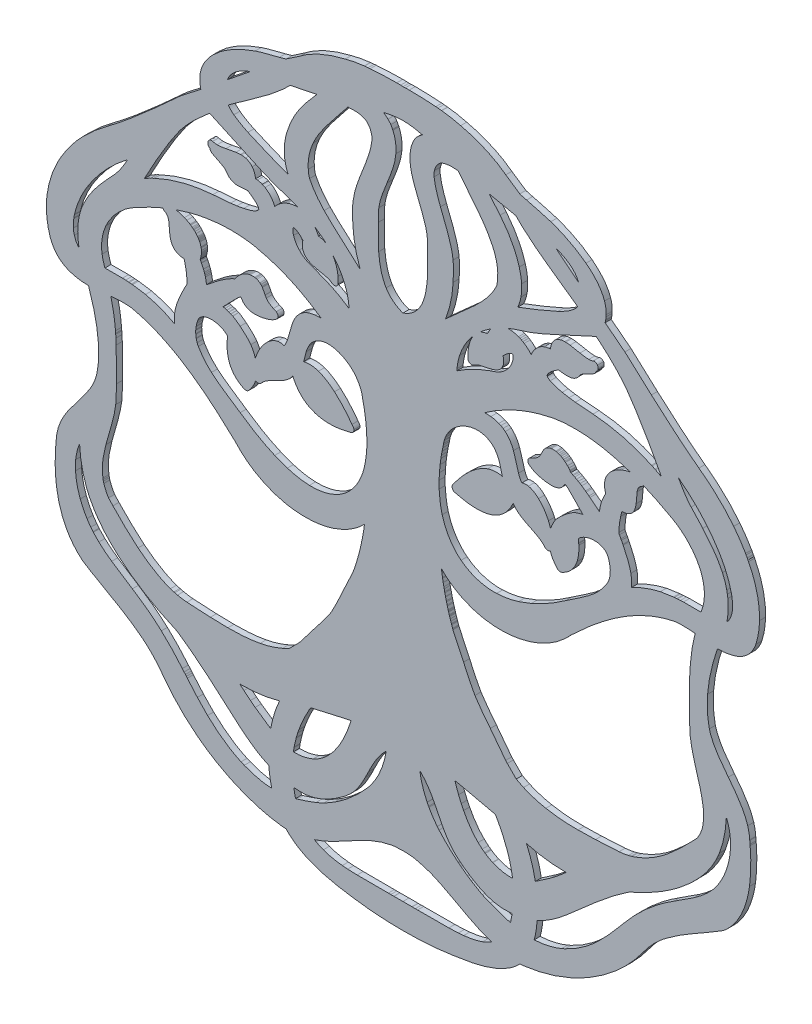
SolidWorks part; units mm, degrees
ref_plane "Front Plane" through (0, 0, 0) normal (0, 0, 1) x (1, 0, 0)
ref_plane "Top Plane" through (0, 0, 0) normal (0, 1, 0) x (1, 0, 0)
ref_plane "Right Plane" through (0, 0, 0) normal (1, 0, 0) x (0, 0, -1)
sketch "Sketch2" plane through (0, 0, 0) normal (0, 0, 1) x (1, 0, 0)
  line L0 (116.2533, 285.5575) -> (115.8788, 285.1187)
  line L1 (188.5467, 285.5575) -> (188.9212, 285.1187)
  spline S0 degree 3 poles (88.1231, 279.7487) (84.9608, 277.1886) (81.7997, 274.6271) (78.6299, 272.0764) knots 0 0 0 0 1 1 1 1
  spline S1 degree 3 poles (78.6299, 272.0764) (79.4073, 274.2558) (81.0865, 275.9862) (82.974, 277.2616) knots 0 0 0 0 1 1 1 1
  spline S2 degree 3 poles (82.974, 277.2616) (84.6197, 278.3775) (86.4387, 279.214) (88.3025, 279.8939) knots 0 0 0 0 1 1 1 1
  spline S3 degree 3 poles (88.3025, 279.8939) (88.2427, 279.8455) (88.1829, 279.7971) (88.1231, 279.7487) knots 0 0 0 0 1 1 1 1
  spline S4 degree 3 poles (216.6769, 279.7487) (219.8391, 277.1886) (223.0003, 274.6271) (226.1701, 272.0764) knots 0 0 0 0 1 1 1 1
  spline S5 degree 3 poles (226.1701, 272.0764) (225.3927, 274.2558) (223.7135, 275.9862) (221.826, 277.2616) knots 0 0 0 0 1 1 1 1
  spline S6 degree 3 poles (221.826, 277.2616) (220.1803, 278.3775) (218.3613, 279.214) (216.4974, 279.8939) knots 0 0 0 0 1 1 1 1
  spline S7 degree 3 poles (216.4974, 279.8939) (216.5573, 279.8455) (216.6171, 279.7971) (216.6769, 279.7487) knots 0 0 0 0 1 1 1 1
  spline S8 degree 3 poles (115.8788, 285.1187) (114.4548, 283.4319) (113.0276, 281.748) (111.5912, 280.072) knots 0 0 0 0 1 1 1 1
  spline S9 degree 3 poles (111.5912, 280.072) (108.0045, 275.7024) (105.111, 270.6899) (103.5525, 265.2348) knots 0 0 0 0 1 1 1 1
  spline S10 degree 3 poles (103.5525, 265.2348) (103.0532, 263.4025) (102.6591, 261.5249) (102.5825, 259.6227) knots 0 0 0 0 1 1 1 1
  spline S11 degree 3 poles (102.5825, 259.6227) (102.5646, 257.9637) (102.4941, 256.286) (102.8388, 254.6515) knots 0 0 0 0 1 1 1 1
  spline S12 degree 3 poles (102.8388, 254.6515) (103.1103, 253.1515) (103.5541, 251.6798) (104.1948, 250.2953) knots 0 0 0 0 1 1 1 1
  spline S13 degree 3 poles (104.1948, 250.2953) (98.5371, 252.5703) (92.7641, 254.5821) (87.2629, 257.2287) knots 0 0 0 0 1 1 1 1
  spline S14 degree 3 poles (87.2629, 257.2287) (85.2303, 258.2218) (83.1393, 259.3049) (81.347, 260.6855) knots 0 0 0 0 1 1 1 1
  spline S15 degree 3 poles (81.347, 260.6855) (80.4715, 261.3843) (79.6094, 262.1445) (79.0149, 263.1049) knots 0 0 0 0 1 1 1 1
  spline S16 degree 3 poles (79.0149, 263.1049) (84.8232, 267.3258) (90.8169, 271.3036) (96.5086, 275.6922) knots 0 0 0 0 1 1 1 1
  spline S17 degree 3 poles (96.5086, 275.6922) (98.4683, 277.2396) (100.4279, 278.7956) (102.2531, 280.5018) knots 0 0 0 0 1 1 1 1
  spline S18 degree 3 poles (102.2531, 280.5018) (103.1761, 281.3846) (104.0742, 282.2928) (104.9832, 283.1898) knots 0 0 0 0 1 1 1 1
  spline S19 degree 3 poles (104.9832, 283.1898) (108.743, 283.9643) (112.5001, 284.7516) (116.2533, 285.5575) knots 0 0 0 0 1 1 1 1
  spline S20 degree 3 poles (188.9212, 285.1187) (190.3452, 283.4319) (191.7724, 281.748) (193.2088, 280.072) knots 0 0 0 0 1 1 1 1
  spline S21 degree 3 poles (193.2088, 280.072) (196.7955, 275.7024) (199.689, 270.6899) (201.2475, 265.2348) knots 0 0 0 0 1 1 1 1
  spline S22 degree 3 poles (201.2475, 265.2348) (201.7468, 263.4025) (202.1409, 261.5249) (202.2175, 259.6227) knots 0 0 0 0 1 1 1 1
  spline S23 degree 3 poles (202.2175, 259.6227) (202.2354, 257.9637) (202.3058, 256.286) (201.9612, 254.6515) knots 0 0 0 0 1 1 1 1
  spline S24 degree 3 poles (201.9612, 254.6515) (201.6897, 253.1515) (201.2459, 251.6798) (200.6052, 250.2953) knots 0 0 0 0 1 1 1 1
  spline S25 degree 3 poles (200.6052, 250.2953) (206.2629, 252.5703) (212.0359, 254.5821) (217.5371, 257.2287) knots 0 0 0 0 1 1 1 1
  spline S26 degree 3 poles (217.5371, 257.2287) (219.5697, 258.2218) (221.6607, 259.3049) (223.453, 260.6855) knots 0 0 0 0 1 1 1 1
  spline S27 degree 3 poles (223.453, 260.6855) (224.3285, 261.3843) (225.1906, 262.1445) (225.785, 263.1049) knots 0 0 0 0 1 1 1 1
  spline S28 degree 3 poles (225.785, 263.1049) (219.9768, 267.3258) (213.9831, 271.3036) (208.2914, 275.6922) knots 0 0 0 0 1 1 1 1
  spline S29 degree 3 poles (208.2914, 275.6922) (206.3316, 277.2396) (204.3721, 278.7956) (202.5469, 280.5018) knots 0 0 0 0 1 1 1 1
  spline S30 degree 3 poles (202.5469, 280.5018) (201.6239, 281.3846) (200.7258, 282.2928) (199.8168, 283.1898) knots 0 0 0 0 1 1 1 1
  spline S31 degree 3 poles (199.8168, 283.1898) (196.057, 283.9643) (192.2999, 284.7516) (188.5467, 285.5575) knots 0 0 0 0 1 1 1 1
  spline S32 degree 3 poles (71.2165, 256.1338) (75.4613, 254.2245) (79.6725, 252.2415) (83.8982, 250.2907) knots 0 0 0 0 1 1 1 1
  spline S33 degree 3 poles (83.8982, 250.2907) (83.962, 250.2576) (84.0288, 250.232) (84.0956, 250.2064) knots 0 0 0 0 1 1 1 1
  spline S34 degree 3 poles (84.0956, 250.2064) (84.2096, 250.1353) (84.3298, 250.0737) (84.4563, 250.0292) knots 0 0 0 0 1 1 1 1
  spline S35 degree 3 poles (84.4563, 250.0292) (84.8525, 249.8709) (85.2332, 249.6334) (85.6382, 249.4887) knots 0 0 0 0 1 1 1 1
  spline S36 degree 3 poles (85.6382, 249.4887) (85.6403, 249.4875) (85.6422, 249.486) (85.6444, 249.485) knots 0 0 0 0 1 1 1 1
  spline S37 degree 3 poles (85.6444, 249.485) (88.1552, 248.3003) (90.6823, 247.1496) (93.2279, 246.0413) knots 0 0 0 0 1 1 1 1
  spline S38 degree 3 poles (93.2279, 246.0413) (96.5753, 244.5846) (99.987, 243.2636) (103.496, 242.2478) knots 0 0 0 0 1 1 1 1
  spline S39 degree 3 poles (103.496, 242.2478) (104.2517, 242.0179) (104.9438, 241.7955) (105.6959, 241.5341) knots 0 0 0 0 1 1 1 1
  spline S40 degree 3 poles (105.6959, 241.5341) (106.5996, 241.2183) (107.4942, 240.8741) (108.3784, 240.5052) knots 0 0 0 0 1 1 1 1
  spline S41 degree 3 poles (108.3784, 240.5052) (106.8416, 240.5686) (105.3076, 240.2823) (103.8732, 239.7301) knots 0 0 0 0 1 1 1 1
  spline S42 degree 3 poles (103.8732, 239.7301) (103.8624, 239.7259) (103.8516, 239.7214) (103.8406, 239.7172) knots 0 0 0 0 1 1 1 1
  spline S43 degree 3 poles (103.8406, 239.7172) (103.6492, 239.6428) (103.4593, 239.5641) (103.2717, 239.4805) knots 0 0 0 0 1 1 1 1
  spline S44 degree 3 poles (103.2717, 239.4805) (103.2549, 239.473) (103.2378, 239.4663) (103.2211, 239.4588) knots 0 0 0 0 1 1 1 1
  spline S45 degree 3 poles (103.2211, 239.4588) (103.0244, 239.3701) (102.8301, 239.2766) (102.6382, 239.1782) knots 0 0 0 0 1 1 1 1
  spline S46 degree 3 poles (102.6382, 239.1782) (102.6253, 239.1716) (102.6128, 239.1642) (102.6, 239.1575) knots 0 0 0 0 1 1 1 1
  spline S47 degree 3 poles (102.6, 239.1575) (102.4249, 239.067) (102.2522, 238.9721) (102.0817, 238.8738) knots 0 0 0 0 1 1 1 1
  spline S48 degree 3 poles (102.0817, 238.8738) (102.0555, 238.8587) (102.0292, 238.8442) (102.0031, 238.8289) knots 0 0 0 0 1 1 1 1
  spline S49 degree 3 poles (102.0031, 238.8289) (101.8171, 238.72) (101.6329, 238.608) (101.4528, 238.4904) knots 0 0 0 0 1 1 1 1
  spline S50 degree 3 poles (101.4528, 238.4904) (100.4218, 237.817) (99.4862, 236.9917) (98.6948, 236.0497) knots 0 0 0 0 1 1 1 1
  spline S51 degree 3 poles (98.6948, 236.0497) (98.6924, 236.0469) (98.6899, 236.0442) (98.6876, 236.0414) knots 0 0 0 0 1 1 1 1
  spline S52 degree 3 poles (98.6876, 236.0414) (98.6852, 236.0385) (98.6828, 236.0356) (98.6804, 236.0326) knots 0 0 0 0 1 1 1 1
  spline S53 degree 3 poles (98.6804, 236.0326) (98.6337, 235.9767) (98.5856, 235.9219) (98.5399, 235.8652) knots 0 0 0 0 1 1 1 1
  spline S54 degree 3 poles (98.5399, 235.8652) (97.7113, 237.8547) (96.326, 239.6541) (94.4636, 240.7719) knots 0 0 0 0 1 1 1 1
  spline S55 degree 3 poles (94.4636, 240.7719) (94.1486, 240.9527) (93.8321, 241.1397) (93.4921, 241.269) knots 0 0 0 0 1 1 1 1
  spline S56 degree 3 poles (93.4921, 241.269) (93.4147, 241.2972) (93.3351, 241.3142) (93.2549, 241.3269) knots 0 0 0 0 1 1 1 1
  spline S57 degree 3 poles (93.2549, 241.3269) (92.6737, 241.6913) (91.9379, 241.7807) (91.2711, 241.8907) knots 0 0 0 0 1 1 1 1
  spline S58 degree 3 poles (91.2711, 241.8907) (91.2399, 241.8932) (91.2088, 241.8931) (91.1775, 241.8943) knots 0 0 0 0 1 1 1 1
  spline S59 degree 3 poles (91.1775, 241.8943) (90.948, 241.9312) (90.7127, 241.9289) (90.4809, 241.9454) knots 0 0 0 0 1 1 1 1
  spline S60 degree 3 poles (90.4809, 241.9454) (90.3028, 243.2485) (89.9006, 244.5628) (89.0676, 245.6026) knots 0 0 0 0 1 1 1 1
  spline S61 degree 3 poles (89.0676, 245.6026) (88.3621, 246.4985) (87.3424, 247.123) (86.2404, 247.3994) knots 0 0 0 0 1 1 1 1
  spline S62 degree 3 poles (86.2404, 247.3994) (85.6697, 247.5458) (85.0814, 247.6272) (84.4916, 247.6179) knots 0 0 0 0 1 1 1 1
  spline S63 degree 3 poles (84.4916, 247.6179) (84.3532, 247.6192) (84.2151, 247.6195) (84.0767, 247.619) knots 0 0 0 0 1 1 1 1
  spline S64 degree 3 poles (84.0767, 247.619) (83.456, 247.6283) (82.8374, 247.5675) (82.2235, 247.4806) knots 0 0 0 0 1 1 1 1
  spline S65 degree 3 poles (82.2235, 247.4806) (80.8162, 247.2821) (79.4107, 246.9554) (78.029, 246.6873) knots 0 0 0 0 1 1 1 1
  spline S66 degree 3 poles (78.029, 246.6873) (76.8015, 246.4494) (75.5592, 246.2239) (74.3041, 246.2424) knots 0 0 0 0 1 1 1 1
  spline S67 degree 3 poles (74.3041, 246.2424) (73.6823, 246.2597) (73.0552, 246.3436) (72.4738, 246.5736) knots 0 0 0 0 1 1 1 1
  spline S68 degree 3 poles (72.4738, 246.5736) (71.8223, 246.7944) (71.0482, 246.5229) (70.6754, 245.9452) knots 0 0 0 0 1 1 1 1
  spline S69 degree 3 poles (70.6754, 245.9452) (70.4393, 245.6079) (70.3766, 245.1834) (70.4155, 244.7805) knots 0 0 0 0 1 1 1 1
  spline S70 degree 3 poles (70.4155, 244.7805) (70.4289, 244.1955) (70.7944, 243.6433) (71.3229, 243.395) knots 0 0 0 0 1 1 1 1
  spline S71 degree 3 poles (71.3229, 243.395) (71.3338, 243.2814) (71.357, 243.1681) (71.3953, 243.057) knots 0 0 0 0 1 1 1 1
  spline S72 degree 3 poles (71.3953, 243.057) (71.565, 242.4595) (72.1221, 242.1232) (72.6283, 241.8354) knots 0 0 0 0 1 1 1 1
  spline S73 degree 3 poles (72.6283, 241.8354) (72.8748, 241.6754) (73.1432, 241.5416) (73.423, 241.4442) knots 0 0 0 0 1 1 1 1
  spline S74 degree 3 poles (73.423, 241.4442) (73.459, 241.4214) (73.493, 241.3957) (73.531, 241.376) knots 0 0 0 0 1 1 1 1
  spline S75 degree 3 poles (73.531, 241.376) (74.8185, 240.6651) (76.2295, 240.1588) (77.4006, 239.2511) knots 0 0 0 0 1 1 1 1
  spline S76 degree 3 poles (77.4006, 239.2511) (77.9369, 238.8552) (78.3151, 238.3025) (78.6878, 237.7607) knots 0 0 0 0 1 1 1 1
  spline S77 degree 3 poles (78.6878, 237.7607) (79.4671, 236.6537) (80.7424, 235.9675) (82.0701, 235.7851) knots 0 0 0 0 1 1 1 1
  spline S78 degree 3 poles (82.0701, 235.7851) (83.7495, 235.5146) (85.4549, 235.8953) (87.109, 236.013) knots 0 0 0 0 1 1 1 1
  spline S79 degree 3 poles (87.109, 236.013) (88.6714, 235.0381) (90.2357, 233.9805) (91.3863, 232.5192) knots 0 0 0 0 1 1 1 1
  spline S80 degree 3 poles (91.3863, 232.5192) (91.5958, 232.2051) (91.8661, 231.8388) (91.7961, 231.4402) knots 0 0 0 0 1 1 1 1
  spline S81 degree 3 poles (91.7961, 231.4402) (91.5718, 230.9091) (91.0333, 230.605) (90.5605, 230.3203) knots 0 0 0 0 1 1 1 1
  spline S82 degree 3 poles (90.5605, 230.3203) (88.9924, 229.4783) (87.2456, 229.0489) (85.5179, 228.6719) knots 0 0 0 0 1 1 1 1
  spline S83 degree 3 poles (85.5179, 228.6719) (84.5438, 228.4681) (83.5756, 228.3025) (82.6137, 228.1598) knots 0 0 0 0 1 1 1 1
  spline S84 degree 3 poles (82.6137, 228.1598) (81.7227, 228.0283) (80.8562, 227.9176) (79.9782, 227.8192) knots 0 0 0 0 1 1 1 1
  spline S85 degree 3 poles (79.9782, 227.8192) (77.5173, 227.5424) (75.0489, 227.3891) (72.5585, 227.2224) knots 0 0 0 0 1 1 1 1
  spline S86 degree 3 poles (72.5585, 227.2224) (64.0805, 226.6018) (55.6963, 224.4988) (47.9905, 220.894) knots 0 0 0 0 1 1 1 1
  spline S87 degree 3 poles (47.9905, 220.894) (47.8907, 220.853) (47.7989, 220.7987) (47.7114, 220.7385) knots 0 0 0 0 1 1 1 1
  spline S88 degree 3 poles (47.7114, 220.7385) (47.3043, 220.5896) (46.922, 220.3583) (46.5317, 220.1763) knots 0 0 0 0 1 1 1 1
  spline S89 degree 3 poles (46.5317, 220.1763) (46.4389, 220.135) (46.3518, 220.083) (46.2681, 220.0259) knots 0 0 0 0 1 1 1 1
  spline S90 degree 3 poles (46.2681, 220.0259) (45.666, 219.7865) (45.1137, 219.4199) (44.5349, 219.1309) knots 0 0 0 0 1 1 1 1
  spline S91 degree 3 poles (44.5349, 219.1309) (44.2791, 218.9894) (44.0241, 218.8463) (43.7706, 218.7009) knots 0 0 0 0 1 1 1 1
  spline S92 degree 3 poles (43.7706, 218.7009) (47.1071, 225.0186) (50.5685, 231.278) (54.373, 237.2776) knots 0 0 0 0 1 1 1 1
  spline S93 degree 3 poles (54.373, 237.2776) (55.7989, 239.4893) (57.2137, 241.7138) (58.7976, 243.8172) knots 0 0 0 0 1 1 1 1
  spline S94 degree 3 poles (58.7976, 243.8172) (62.2032, 248.1431) (66.1569, 251.9418) (70.3757, 255.4428) knots 0 0 0 0 1 1 1 1
  spline S95 degree 3 poles (70.3757, 255.4428) (70.6548, 255.6746) (70.9352, 255.9046) (71.2165, 256.1338) knots 0 0 0 0 1 1 1 1
  spline S96 degree 3 poles (233.5833, 256.1338) (229.3387, 254.2245) (225.1275, 252.2415) (220.9017, 250.2907) knots 0 0 0 0 1 1 1 1
  spline S97 degree 3 poles (220.9017, 250.2907) (220.8381, 250.2576) (220.7711, 250.232) (220.7044, 250.2064) knots 0 0 0 0 1 1 1 1
  spline S98 degree 3 poles (220.7044, 250.2064) (220.5904, 250.1353) (220.4702, 250.0737) (220.3437, 250.0292) knots 0 0 0 0 1 1 1 1
  spline S99 degree 3 poles (220.3437, 250.0292) (219.9475, 249.8709) (219.5668, 249.6334) (219.1618, 249.4887) knots 0 0 0 0 1 1 1 1
  spline S100 degree 3 poles (219.1618, 249.4887) (219.1598, 249.4875) (219.1578, 249.486) (219.1558, 249.485) knots 0 0 0 0 1 1 1 1
  spline S101 degree 3 poles (219.1558, 249.485) (216.645, 248.3003) (214.1179, 247.1496) (211.5723, 246.0413) knots 0 0 0 0 1 1 1 1
  spline S102 degree 3 poles (211.5723, 246.0413) (208.2249, 244.5846) (204.8131, 243.2636) (201.3042, 242.2478) knots 0 0 0 0 1 1 1 1
  spline S103 degree 3 poles (201.3042, 242.2478) (200.5485, 242.0179) (199.8564, 241.7955) (199.1043, 241.5341) knots 0 0 0 0 1 1 1 1
  spline S104 degree 3 poles (199.1043, 241.5341) (198.2006, 241.2183) (197.306, 240.8741) (196.4218, 240.5052) knots 0 0 0 0 1 1 1 1
  spline S105 degree 3 poles (196.4218, 240.5052) (197.9586, 240.5686) (199.4926, 240.2823) (200.927, 239.7301) knots 0 0 0 0 1 1 1 1
  spline S106 degree 3 poles (200.927, 239.7301) (200.9379, 239.7259) (200.9486, 239.7214) (200.9595, 239.7172) knots 0 0 0 0 1 1 1 1
  spline S107 degree 3 poles (200.9595, 239.7172) (201.151, 239.6428) (201.3409, 239.5641) (201.5285, 239.4805) knots 0 0 0 0 1 1 1 1
  spline S108 degree 3 poles (201.5285, 239.4805) (201.5453, 239.473) (201.5624, 239.4663) (201.5791, 239.4588) knots 0 0 0 0 1 1 1 1
  spline S109 degree 3 poles (201.5791, 239.4588) (201.7758, 239.3701) (201.9701, 239.2766) (202.162, 239.1782) knots 0 0 0 0 1 1 1 1
  spline S110 degree 3 poles (202.162, 239.1782) (202.1749, 239.1716) (202.1874, 239.1642) (202.2002, 239.1575) knots 0 0 0 0 1 1 1 1
  spline S111 degree 3 poles (202.2002, 239.1575) (202.3753, 239.067) (202.548, 238.9721) (202.7185, 238.8738) knots 0 0 0 0 1 1 1 1
  spline S112 degree 3 poles (202.7185, 238.8738) (202.7446, 238.8587) (202.771, 238.8442) (202.797, 238.8289) knots 0 0 0 0 1 1 1 1
  spline S113 degree 3 poles (202.797, 238.8289) (202.9831, 238.72) (203.1673, 238.608) (203.3474, 238.4904) knots 0 0 0 0 1 1 1 1
  spline S114 degree 3 poles (203.3474, 238.4904) (204.3784, 237.817) (205.3139, 236.9917) (206.1054, 236.0497) knots 0 0 0 0 1 1 1 1
  spline S115 degree 3 poles (206.1054, 236.0497) (206.1074, 236.0469) (206.1104, 236.0442) (206.1124, 236.0414) knots 0 0 0 0 1 1 1 1
  spline S116 degree 3 poles (206.1124, 236.0414) (206.1144, 236.0385) (206.1174, 236.0356) (206.1194, 236.0326) knots 0 0 0 0 1 1 1 1
  spline S117 degree 3 poles (206.1194, 236.0326) (206.1662, 235.9767) (206.2142, 235.9219) (206.2599, 235.8652) knots 0 0 0 0 1 1 1 1
  spline S118 degree 3 poles (206.2599, 235.8652) (207.0884, 237.8547) (208.4738, 239.6541) (210.3362, 240.7719) knots 0 0 0 0 1 1 1 1
  spline S119 degree 3 poles (210.3362, 240.7719) (210.6512, 240.9527) (210.9677, 241.1397) (211.3077, 241.269) knots 0 0 0 0 1 1 1 1
  spline S120 degree 3 poles (211.3077, 241.269) (211.3851, 241.2972) (211.4647, 241.3142) (211.5449, 241.3269) knots 0 0 0 0 1 1 1 1
  spline S121 degree 3 poles (211.5449, 241.3269) (212.1261, 241.6913) (212.8619, 241.7807) (213.5287, 241.8907) knots 0 0 0 0 1 1 1 1
  spline S122 degree 3 poles (213.5287, 241.8907) (213.5598, 241.8932) (213.591, 241.8931) (213.6222, 241.8943) knots 0 0 0 0 1 1 1 1
  spline S123 degree 3 poles (213.6222, 241.8943) (213.8518, 241.9312) (214.0871, 241.9289) (214.3188, 241.9454) knots 0 0 0 0 1 1 1 1
  spline S124 degree 3 poles (214.3188, 241.9454) (214.497, 243.2485) (214.8992, 244.5628) (215.7322, 245.6026) knots 0 0 0 0 1 1 1 1
  spline S125 degree 3 poles (215.7322, 245.6026) (216.4377, 246.4985) (217.4573, 247.123) (218.5594, 247.3994) knots 0 0 0 0 1 1 1 1
  spline S126 degree 3 poles (218.5594, 247.3994) (219.13, 247.5458) (219.7183, 247.6272) (220.3081, 247.6179) knots 0 0 0 0 1 1 1 1
  spline S127 degree 3 poles (220.3081, 247.6179) (220.4465, 247.6192) (220.5846, 247.6195) (220.7231, 247.619) knots 0 0 0 0 1 1 1 1
  spline S128 degree 3 poles (220.7231, 247.619) (221.3438, 247.6283) (221.9624, 247.5675) (222.5762, 247.4806) knots 0 0 0 0 1 1 1 1
  spline S129 degree 3 poles (222.5762, 247.4806) (223.9836, 247.2821) (225.3891, 246.9554) (226.7708, 246.6873) knots 0 0 0 0 1 1 1 1
  spline S130 degree 3 poles (226.7708, 246.6873) (227.9982, 246.4494) (229.2406, 246.2239) (230.4956, 246.2424) knots 0 0 0 0 1 1 1 1
  spline S131 degree 3 poles (230.4956, 246.2424) (231.1175, 246.2597) (231.7445, 246.3436) (232.326, 246.5736) knots 0 0 0 0 1 1 1 1
  spline S132 degree 3 poles (232.326, 246.5736) (232.9775, 246.7944) (233.7515, 246.5229) (234.1243, 245.9452) knots 0 0 0 0 1 1 1 1
  spline S133 degree 3 poles (234.1243, 245.9452) (234.3605, 245.6079) (234.4232, 245.1834) (234.3843, 244.7805) knots 0 0 0 0 1 1 1 1
  spline S134 degree 3 poles (234.3843, 244.7805) (234.3709, 244.1955) (234.0053, 243.6433) (233.4768, 243.395) knots 0 0 0 0 1 1 1 1
  spline S135 degree 3 poles (233.4768, 243.395) (233.4659, 243.2814) (233.4427, 243.1681) (233.4045, 243.057) knots 0 0 0 0 1 1 1 1
  spline S136 degree 3 poles (233.4045, 243.057) (233.2348, 242.4595) (232.6777, 242.1232) (232.1715, 241.8354) knots 0 0 0 0 1 1 1 1
  spline S137 degree 3 poles (232.1715, 241.8354) (231.925, 241.6754) (231.6566, 241.5416) (231.3768, 241.4442) knots 0 0 0 0 1 1 1 1
  spline S138 degree 3 poles (231.3768, 241.4442) (231.3407, 241.4214) (231.3069, 241.3957) (231.2688, 241.376) knots 0 0 0 0 1 1 1 1
  spline S139 degree 3 poles (231.2688, 241.376) (229.9813, 240.6651) (228.5703, 240.1588) (227.3992, 239.2511) knots 0 0 0 0 1 1 1 1
  spline S140 degree 3 poles (227.3992, 239.2511) (226.8629, 238.8552) (226.4847, 238.3025) (226.1119, 237.7607) knots 0 0 0 0 1 1 1 1
  spline S141 degree 3 poles (226.1119, 237.7607) (225.3326, 236.6537) (224.0574, 235.9675) (222.7297, 235.7851) knots 0 0 0 0 1 1 1 1
  spline S142 degree 3 poles (222.7297, 235.7851) (221.0503, 235.5146) (219.3449, 235.8953) (217.6908, 236.013) knots 0 0 0 0 1 1 1 1
  spline S143 degree 3 poles (217.6908, 236.013) (216.1284, 235.0381) (214.564, 233.9805) (213.4135, 232.5192) knots 0 0 0 0 1 1 1 1
  spline S144 degree 3 poles (213.4135, 232.5192) (213.204, 232.2051) (212.9337, 231.8388) (213.0037, 231.4402) knots 0 0 0 0 1 1 1 1
  spline S145 degree 3 poles (213.0037, 231.4402) (213.228, 230.9091) (213.7665, 230.605) (214.2393, 230.3203) knots 0 0 0 0 1 1 1 1
  spline S146 degree 3 poles (214.2393, 230.3203) (215.8074, 229.4783) (217.5542, 229.0489) (219.2819, 228.6719) knots 0 0 0 0 1 1 1 1
  spline S147 degree 3 poles (219.2819, 228.6719) (220.2559, 228.4681) (221.2242, 228.3025) (222.1861, 228.1598) knots 0 0 0 0 1 1 1 1
  spline S148 degree 3 poles (222.1861, 228.1598) (223.0771, 228.0283) (223.9436, 227.9176) (224.8216, 227.8192) knots 0 0 0 0 1 1 1 1
  spline S149 degree 3 poles (224.8216, 227.8192) (227.2825, 227.5424) (229.7509, 227.3891) (232.2413, 227.2224) knots 0 0 0 0 1 1 1 1
  spline S150 degree 3 poles (232.2413, 227.2224) (240.7193, 226.6018) (249.1035, 224.4988) (256.8093, 220.894) knots 0 0 0 0 1 1 1 1
  spline S151 degree 3 poles (256.8093, 220.894) (256.9091, 220.853) (257.0009, 220.7987) (257.0884, 220.7385) knots 0 0 0 0 1 1 1 1
  spline S152 degree 3 poles (257.0884, 220.7385) (257.4954, 220.5896) (257.8778, 220.3583) (258.2681, 220.1763) knots 0 0 0 0 1 1 1 1
  spline S153 degree 3 poles (258.2681, 220.1763) (258.3609, 220.135) (258.448, 220.083) (258.5317, 220.0259) knots 0 0 0 0 1 1 1 1
  spline S154 degree 3 poles (258.5317, 220.0259) (259.1338, 219.7865) (259.6861, 219.4199) (260.2649, 219.1309) knots 0 0 0 0 1 1 1 1
  spline S155 degree 3 poles (260.2649, 219.1309) (260.5207, 218.9894) (260.7757, 218.8463) (261.0292, 218.7009) knots 0 0 0 0 1 1 1 1
  spline S156 degree 3 poles (261.0292, 218.7009) (257.6927, 225.0186) (254.2313, 231.278) (250.4268, 237.2776) knots 0 0 0 0 1 1 1 1
  spline S157 degree 3 poles (250.4268, 237.2776) (249.0009, 239.4893) (247.5861, 241.7138) (246.0022, 243.8172) knots 0 0 0 0 1 1 1 1
  spline S158 degree 3 poles (246.0022, 243.8172) (242.5966, 248.1431) (238.6429, 251.9418) (234.4241, 255.4428) knots 0 0 0 0 1 1 1 1
  spline S159 degree 3 poles (234.4241, 255.4428) (234.145, 255.6746) (233.8646, 255.9046) (233.5833, 256.1338) knots 0 0 0 0 1 1 1 1
  spline S160 degree 3 poles (115.4363, 236.8052) (116.2139, 236.3015) (116.9757, 235.773) (117.7174, 235.2166) knots 0 0 0 0 1 1 1 1
  spline S161 degree 3 poles (117.7174, 235.2166) (118.1789, 234.8696) (118.6856, 234.471) (119.1493, 234.0844) knots 0 0 0 0 1 1 1 1
  spline S162 degree 3 poles (119.1493, 234.0844) (119.5088, 233.7851) (119.8624, 233.479) (120.2097, 233.1656) knots 0 0 0 0 1 1 1 1
  spline S163 degree 3 poles (120.2097, 233.1656) (119.4325, 233.6522) (118.5692, 234.0125) (117.6714, 234.2002) knots 0 0 0 0 1 1 1 1
  spline S164 degree 3 poles (117.6714, 234.2002) (117.6045, 234.214) (117.5371, 234.2209) (117.4698, 234.225) knots 0 0 0 0 1 1 1 1
  spline S165 degree 3 poles (117.4698, 234.225) (117.2789, 234.2584) (117.0859, 234.2808) (116.8936, 234.3035) knots 0 0 0 0 1 1 1 1
  spline S166 degree 3 poles (116.8936, 234.3035) (116.5077, 235.1878) (116.0222, 236.0357) (115.4363, 236.8052) knots 0 0 0 0 1 1 1 1
  spline S167 degree 3 poles (189.3636, 236.8052) (188.5861, 236.3015) (187.8243, 235.773) (187.0826, 235.2166) knots 0 0 0 0 1 1 1 1
  spline S168 degree 3 poles (187.0826, 235.2166) (186.6211, 234.8696) (186.1144, 234.471) (185.6507, 234.0844) knots 0 0 0 0 1 1 1 1
  spline S169 degree 3 poles (185.6507, 234.0844) (185.2912, 233.7851) (184.9376, 233.479) (184.5903, 233.1656) knots 0 0 0 0 1 1 1 1
  spline S170 degree 3 poles (184.5903, 233.1656) (185.3675, 233.6522) (186.2308, 234.0125) (187.1286, 234.2002) knots 0 0 0 0 1 1 1 1
  spline S171 degree 3 poles (187.1286, 234.2002) (187.1955, 234.214) (187.2629, 234.2209) (187.3302, 234.225) knots 0 0 0 0 1 1 1 1
  spline S172 degree 3 poles (187.3302, 234.225) (187.5211, 234.2584) (187.7141, 234.2808) (187.9064, 234.3035) knots 0 0 0 0 1 1 1 1
  spline S173 degree 3 poles (187.9064, 234.3035) (188.2923, 235.1878) (188.7777, 236.0357) (189.3636, 236.8052) knots 0 0 0 0 1 1 1 1
  spline S174 degree 3 poles (106.3998, 232.193) (106.4827, 232.191) (106.5658, 232.1894) (106.6488, 232.1874) knots 0 0 0 0 1 1 1 1
  spline S175 degree 3 poles (106.6488, 232.1874) (107.6052, 231.9655) (108.3928, 231.3264) (109.1287, 230.7079) knots 0 0 0 0 1 1 1 1
  spline S176 degree 3 poles (109.1287, 230.7079) (109.5568, 230.3356) (109.9643, 229.9403) (110.3586, 229.5327) knots 0 0 0 0 1 1 1 1
  spline S177 degree 3 poles (110.3586, 229.5327) (110.05, 228.2969) (109.9719, 226.9466) (110.4449, 225.7412) knots 0 0 0 0 1 1 1 1
  spline S178 degree 3 poles (110.4449, 225.7412) (110.9341, 224.4291) (112.0566, 223.4537) (113.3135, 222.8954) knots 0 0 0 0 1 1 1 1
  spline S179 degree 3 poles (113.3135, 222.8954) (115.0367, 222.1125) (116.9345, 221.874) (118.7643, 221.4686) knots 0 0 0 0 1 1 1 1
  spline S180 degree 3 poles (118.7643, 221.4686) (119.9056, 221.211) (121.1467, 220.9924) (122.1533, 220.3224) knots 0 0 0 0 1 1 1 1
  spline S181 degree 3 poles (122.1533, 220.3224) (122.5657, 219.9841) (123.0445, 219.6663) (123.6018, 219.6889) knots 0 0 0 0 1 1 1 1
  spline S182 degree 3 poles (123.6018, 219.6889) (124.3761, 219.7024) (125.0676, 220.341) (125.1453, 221.111) knots 0 0 0 0 1 1 1 1
  spline S183 degree 3 poles (125.1453, 221.111) (125.2023, 221.9914) (125.1622, 222.8775) (125.1009, 223.7569) knots 0 0 0 0 1 1 1 1
  spline S184 degree 3 poles (125.1009, 223.7569) (124.839, 226.1348) (124.1697, 228.515) (122.8349, 230.5223) knots 0 0 0 0 1 1 1 1
  spline S185 degree 3 poles (122.8349, 230.5223) (123.7419, 229.4995) (124.5851, 228.4145) (125.3319, 227.2905) knots 0 0 0 0 1 1 1 1
  spline S186 degree 3 poles (125.3319, 227.2905) (126.7268, 225.2009) (127.8558, 222.8858) (128.6077, 220.5126) knots 0 0 0 0 1 1 1 1
  spline S187 degree 3 poles (128.6077, 220.5126) (129.1591, 218.7879) (129.5291, 216.9656) (129.7074, 215.1894) knots 0 0 0 0 1 1 1 1
  spline S188 degree 3 poles (129.7074, 215.1894) (129.7361, 214.9037) (129.7606, 214.6176) (129.7803, 214.3311) knots 0 0 0 0 1 1 1 1
  spline S189 degree 3 poles (129.7803, 214.3311) (125.4909, 217.389) (120.6616, 219.6067) (115.7181, 221.3803) knots 0 0 0 0 1 1 1 1
  spline S190 degree 3 poles (115.7181, 221.3803) (114.5546, 221.8056) (113.3392, 222.1008) (112.2356, 222.6779) knots 0 0 0 0 1 1 1 1
  spline S191 degree 3 poles (112.2356, 222.6779) (110.9671, 223.3057) (109.8175, 224.1662) (108.8586, 225.2074) knots 0 0 0 0 1 1 1 1
  spline S192 degree 3 poles (108.8586, 225.2074) (107.7513, 226.37) (106.9095, 227.7911) (106.4251, 229.3219) knots 0 0 0 0 1 1 1 1
  spline S193 degree 3 poles (106.4251, 229.3219) (106.1806, 230.159) (106.0231, 231.071) (106.2566, 231.9279) knots 0 0 0 0 1 1 1 1
  spline S194 degree 3 poles (106.2566, 231.9279) (106.2917, 232.0206) (106.3255, 232.1238) (106.3998, 232.193) knots 0 0 0 0 1 1 1 1
  spline S195 degree 3 poles (198.4002, 232.193) (198.3173, 232.191) (198.2342, 232.1894) (198.1512, 232.1874) knots 0 0 0 0 1 1 1 1
  spline S196 degree 3 poles (198.1512, 232.1874) (197.1948, 231.9655) (196.4071, 231.3264) (195.6713, 230.7079) knots 0 0 0 0 1 1 1 1
  spline S197 degree 3 poles (195.6713, 230.7079) (195.2432, 230.3356) (194.8357, 229.9403) (194.4413, 229.5327) knots 0 0 0 0 1 1 1 1
  spline S198 degree 3 poles (194.4413, 229.5327) (194.75, 228.2969) (194.8281, 226.9466) (194.3551, 225.7412) knots 0 0 0 0 1 1 1 1
  spline S199 degree 3 poles (194.3551, 225.7412) (193.8659, 224.4291) (192.7433, 223.4537) (191.4865, 222.8954) knots 0 0 0 0 1 1 1 1
  spline S200 degree 3 poles (191.4865, 222.8954) (189.7633, 222.1125) (187.8655, 221.874) (186.0357, 221.4686) knots 0 0 0 0 1 1 1 1
  spline S201 degree 3 poles (186.0357, 221.4686) (184.8944, 221.211) (183.6533, 220.9924) (182.6467, 220.3224) knots 0 0 0 0 1 1 1 1
  spline S202 degree 3 poles (182.6467, 220.3224) (182.2343, 219.9841) (181.7555, 219.6663) (181.1982, 219.6889) knots 0 0 0 0 1 1 1 1
  spline S203 degree 3 poles (181.1982, 219.6889) (180.4239, 219.7024) (179.7324, 220.341) (179.6547, 221.111) knots 0 0 0 0 1 1 1 1
  spline S204 degree 3 poles (179.6547, 221.111) (179.5977, 221.9914) (179.6378, 222.8775) (179.6991, 223.7569) knots 0 0 0 0 1 1 1 1
  spline S205 degree 3 poles (179.6991, 223.7569) (179.961, 226.1348) (180.6303, 228.515) (181.9651, 230.5223) knots 0 0 0 0 1 1 1 1
  spline S206 degree 3 poles (181.9651, 230.5223) (181.0581, 229.4995) (180.2148, 228.4145) (179.4681, 227.2905) knots 0 0 0 0 1 1 1 1
  spline S207 degree 3 poles (179.4681, 227.2905) (178.0732, 225.2009) (176.9442, 222.8858) (176.1923, 220.5126) knots 0 0 0 0 1 1 1 1
  spline S208 degree 3 poles (176.1923, 220.5126) (175.6409, 218.7879) (175.2709, 216.9656) (175.0926, 215.1894) knots 0 0 0 0 1 1 1 1
  spline S209 degree 3 poles (175.0926, 215.1894) (175.0639, 214.9037) (175.0394, 214.6176) (175.0197, 214.3311) knots 0 0 0 0 1 1 1 1
  spline S210 degree 3 poles (175.0197, 214.3311) (179.3091, 217.389) (184.1384, 219.6067) (189.0819, 221.3803) knots 0 0 0 0 1 1 1 1
  spline S211 degree 3 poles (189.0819, 221.3803) (190.2454, 221.8056) (191.4608, 222.1008) (192.5644, 222.6779) knots 0 0 0 0 1 1 1 1
  spline S212 degree 3 poles (192.5644, 222.6779) (193.8328, 223.3057) (194.9825, 224.1662) (195.9414, 225.2074) knots 0 0 0 0 1 1 1 1
  spline S213 degree 3 poles (195.9414, 225.2074) (197.0487, 226.37) (197.8904, 227.7911) (198.3749, 229.3219) knots 0 0 0 0 1 1 1 1
  spline S214 degree 3 poles (198.3749, 229.3219) (198.6194, 230.159) (198.7769, 231.071) (198.5433, 231.9279) knots 0 0 0 0 1 1 1 1
  spline S215 degree 3 poles (198.5433, 231.9279) (198.5083, 232.0206) (198.4745, 232.1238) (198.4002, 232.193) knots 0 0 0 0 1 1 1 1
  spline S216 degree 3 poles (36.697, 222.0257) (35.1836, 219.1893) (33.4923, 216.4138) (31.3376, 214.0138) knots 0 0 0 0 1 1 1 1
  spline S217 degree 3 poles (31.3376, 214.0138) (29.6724, 212.271) (28.0151, 210.5197) (26.4392, 208.6948) knots 0 0 0 0 1 1 1 1
  spline S218 degree 3 poles (26.4392, 208.6948) (23.2398, 205.0439) (20.2049, 201.1622) (18.1849, 196.7172) knots 0 0 0 0 1 1 1 1
  spline S219 degree 3 poles (18.1849, 196.7172) (17.3991, 194.9805) (16.7572, 193.1669) (16.3819, 191.2968) knots 0 0 0 0 1 1 1 1
  spline S220 degree 3 poles (16.3819, 191.2968) (16.3818, 191.2948) (16.3821, 191.2939) (16.3819, 191.2918) knots 0 0 0 0 1 1 1 1
  spline S221 degree 3 poles (16.3819, 191.2918) (16.2789, 190.829) (16.1812, 190.3637) (16.1163, 189.894) knots 0 0 0 0 1 1 1 1
  spline S222 degree 3 poles (16.1163, 189.894) (16.1156, 189.891) (16.1144, 189.888) (16.1137, 189.885) knots 0 0 0 0 1 1 1 1
  spline S223 degree 3 poles (16.1137, 189.885) (16.0238, 189.4091) (15.9712, 188.9257) (15.9132, 188.4448) knots 0 0 0 0 1 1 1 1
  spline S224 degree 3 poles (15.9132, 188.4448) (15.6039, 185.5722) (15.7654, 182.6595) (16.2765, 179.8195) knots 0 0 0 0 1 1 1 1
  spline S225 degree 3 poles (16.2765, 179.8195) (15.2922, 180.7565) (14.71, 182.0301) (14.3454, 183.3205) knots 0 0 0 0 1 1 1 1
  spline S226 degree 3 poles (14.3454, 183.3205) (14.1281, 184.1026) (13.9718, 184.903) (13.8823, 185.7095) knots 0 0 0 0 1 1 1 1
  spline S227 degree 3 poles (13.8823, 185.7095) (13.8541, 186.9022) (13.942, 188.0946) (14.0968, 189.2768) knots 0 0 0 0 1 1 1 1
  spline S228 degree 3 poles (14.0968, 189.2768) (14.1226, 189.3825) (14.1419, 189.4896) (14.1516, 189.5972) knots 0 0 0 0 1 1 1 1
  spline S229 degree 3 poles (14.1516, 189.5972) (14.2015, 189.9752) (14.2874, 190.3486) (14.3371, 190.7263) knots 0 0 0 0 1 1 1 1
  spline S230 degree 3 poles (14.3371, 190.7263) (14.3709, 190.821) (14.3969, 190.9188) (14.4141, 191.0188) knots 0 0 0 0 1 1 1 1
  spline S231 degree 3 poles (14.4141, 191.0188) (15.3502, 195.3526) (17.1885, 199.4446) (19.4706, 203.2294) knots 0 0 0 0 1 1 1 1
  spline S232 degree 3 poles (19.4706, 203.2294) (21.1353, 205.9921) (23.0985, 208.6655) (25.1824, 211.1328) knots 0 0 0 0 1 1 1 1
  spline S233 degree 3 poles (25.1824, 211.1328) (27.2937, 213.6399) (29.6174, 215.9787) (32.0482, 218.1954) knots 0 0 0 0 1 1 1 1
  spline S234 degree 3 poles (32.0482, 218.1954) (33.5405, 219.5441) (35.098, 220.8294) (36.697, 222.0257) knots 0 0 0 0 1 1 1 1
  spline S235 degree 3 poles (268.1034, 222.0257) (269.6163, 219.1893) (271.3077, 216.4138) (273.4624, 214.0138) knots 0 0 0 0 1 1 1 1
  spline S236 degree 3 poles (273.4624, 214.0138) (275.1276, 212.271) (276.7849, 210.5197) (278.3608, 208.6948) knots 0 0 0 0 1 1 1 1
  spline S237 degree 3 poles (278.3608, 208.6948) (281.5601, 205.0439) (284.5951, 201.1622) (286.615, 196.7172) knots 0 0 0 0 1 1 1 1
  spline S238 degree 3 poles (286.615, 196.7172) (287.4009, 194.9805) (288.0428, 193.1669) (288.418, 191.2968) knots 0 0 0 0 1 1 1 1
  spline S239 degree 3 poles (288.418, 191.2968) (288.4182, 191.2948) (288.4179, 191.2939) (288.418, 191.2918) knots 0 0 0 0 1 1 1 1
  spline S240 degree 3 poles (288.418, 191.2918) (288.5211, 190.829) (288.6188, 190.3637) (288.6836, 189.894) knots 0 0 0 0 1 1 1 1
  spline S241 degree 3 poles (288.6836, 189.894) (288.6844, 189.891) (288.6857, 189.888) (288.6867, 189.885) knots 0 0 0 0 1 1 1 1
  spline S242 degree 3 poles (288.6867, 189.885) (288.7767, 189.4091) (288.8291, 188.9257) (288.8872, 188.4448) knots 0 0 0 0 1 1 1 1
  spline S243 degree 3 poles (288.8872, 188.4448) (289.1966, 185.5722) (289.035, 182.6595) (288.5239, 179.8195) knots 0 0 0 0 1 1 1 1
  spline S244 degree 3 poles (288.5239, 179.8195) (289.5081, 180.7565) (290.0904, 182.0301) (290.455, 183.3205) knots 0 0 0 0 1 1 1 1
  spline S245 degree 3 poles (290.455, 183.3205) (290.6722, 184.1026) (290.8286, 184.903) (290.9181, 185.7095) knots 0 0 0 0 1 1 1 1
  spline S246 degree 3 poles (290.9181, 185.7095) (290.9464, 186.9022) (290.8584, 188.0946) (290.7036, 189.2768) knots 0 0 0 0 1 1 1 1
  spline S247 degree 3 poles (290.7036, 189.2768) (290.6778, 189.3825) (290.6585, 189.4896) (290.6488, 189.5972) knots 0 0 0 0 1 1 1 1
  spline S248 degree 3 poles (290.6488, 189.5972) (290.5989, 189.9752) (290.513, 190.3486) (290.4633, 190.7263) knots 0 0 0 0 1 1 1 1
  spline S249 degree 3 poles (290.4633, 190.7263) (290.4295, 190.821) (290.4035, 190.9188) (290.3863, 191.0188) knots 0 0 0 0 1 1 1 1
  spline S250 degree 3 poles (290.3863, 191.0188) (289.4502, 195.3526) (287.6118, 199.4446) (285.3297, 203.2294) knots 0 0 0 0 1 1 1 1
  spline S251 degree 3 poles (285.3297, 203.2294) (283.665, 205.9921) (281.7018, 208.6655) (279.6179, 211.1328) knots 0 0 0 0 1 1 1 1
  spline S252 degree 3 poles (279.6179, 211.1328) (277.5067, 213.6399) (275.183, 215.9787) (272.7522, 218.1954) knots 0 0 0 0 1 1 1 1
  spline S253 degree 3 poles (272.7522, 218.1954) (271.2598, 219.5441) (269.7024, 220.8294) (268.1034, 222.0257) knots 0 0 0 0 1 1 1 1
  spline S254 degree 3 poles (79.6982, 218.1244) (81.1561, 218.1344) (82.6168, 218.0891) (84.0858, 217.9846) knots 0 0 0 0 1 1 1 1
  spline S255 degree 3 poles (84.0858, 217.9846) (84.2933, 217.9682) (84.508, 217.9469) (84.7209, 217.9407) knots 0 0 0 0 1 1 1 1
  spline S256 degree 3 poles (84.7209, 217.9407) (84.7922, 217.9311) (84.8638, 217.9245) (84.9354, 217.9231) knots 0 0 0 0 1 1 1 1
  spline S257 degree 3 poles (84.9354, 217.9231) (85.35, 217.8933) (85.7635, 217.8248) (86.1787, 217.8038) knots 0 0 0 0 1 1 1 1
  spline S258 degree 3 poles (86.1787, 217.8038) (86.2388, 217.793) (86.2996, 217.7843) (86.3606, 217.7805) knots 0 0 0 0 1 1 1 1
  spline S259 degree 3 poles (86.3606, 217.7805) (87.343, 217.6702) (88.3253, 217.5298) (89.3005, 217.3588) knots 0 0 0 0 1 1 1 1
  spline S260 degree 3 poles (89.3005, 217.3588) (89.4772, 217.3278) (89.6956, 217.2887) (89.8974, 217.2508) knots 0 0 0 0 1 1 1 1
  spline S261 degree 3 poles (89.8974, 217.2508) (91.7026, 216.9122) (93.5228, 216.47) (95.2944, 215.9331) knots 0 0 0 0 1 1 1 1
  spline S262 degree 3 poles (95.2944, 215.9331) (95.5828, 215.8461) (95.847, 215.7611) (96.1394, 215.6711) knots 0 0 0 0 1 1 1 1
  spline S263 degree 3 poles (96.1394, 215.6711) (97.1607, 215.3662) (98.1777, 215.0472) (99.1851, 214.699) knots 0 0 0 0 1 1 1 1
  spline S264 degree 3 poles (99.1851, 214.699) (99.5672, 214.5678) (99.9938, 214.4169) (100.3665, 214.2815) knots 0 0 0 0 1 1 1 1
  spline S265 degree 3 poles (100.3665, 214.2815) (101.2319, 213.9675) (102.1168, 213.6274) (102.9653, 213.282) knots 0 0 0 0 1 1 1 1
  spline S266 degree 3 poles (102.9653, 213.282) (103.7196, 212.9779) (104.4841, 212.6425) (105.2391, 212.3131) knots 0 0 0 0 1 1 1 1
  spline S267 degree 3 poles (105.2391, 212.3131) (105.2739, 212.2982) (105.3104, 212.2891) (105.346, 212.2769) knots 0 0 0 0 1 1 1 1
  spline S268 degree 3 poles (105.346, 212.2769) (105.6403, 212.1083) (105.9641, 211.9885) (106.2452, 211.8444) knots 0 0 0 0 1 1 1 1
  spline S269 degree 3 poles (106.2452, 211.8444) (106.3951, 211.7659) (106.5537, 211.697) (106.7155, 211.6398) knots 0 0 0 0 1 1 1 1
  spline S270 degree 3 poles (106.7155, 211.6398) (106.8089, 211.5882) (106.9043, 211.5397) (107.0002, 211.4956) knots 0 0 0 0 1 1 1 1
  spline S271 degree 3 poles (107.0002, 211.4956) (107.5294, 211.2362) (108.0598, 210.9798) (108.5846, 210.7117) knots 0 0 0 0 1 1 1 1
  spline S272 degree 3 poles (108.5846, 210.7117) (108.6969, 210.6545) (108.854, 210.5743) (108.983, 210.5076) knots 0 0 0 0 1 1 1 1
  spline S273 degree 3 poles (108.983, 210.5076) (112.1315, 208.8801) (115.1628, 207.0278) (118.0605, 204.9875) knots 0 0 0 0 1 1 1 1
  spline S274 degree 3 poles (118.0605, 204.9875) (117.1923, 204.9932) (116.3212, 204.9905) (115.4591, 204.8748) knots 0 0 0 0 1 1 1 1
  spline S275 degree 3 poles (115.4591, 204.8748) (114.3211, 204.7384) (113.1914, 204.4787) (112.1306, 204.0397) knots 0 0 0 0 1 1 1 1
  spline S276 degree 3 poles (112.1306, 204.0397) (111.8396, 203.9406) (111.5641, 203.7859) (111.2888, 203.6537) knots 0 0 0 0 1 1 1 1
  spline S277 degree 3 poles (111.2888, 203.6537) (110.9654, 203.4778) (110.6301, 203.3121) (110.3416, 203.0817) knots 0 0 0 0 1 1 1 1
  spline S278 degree 3 poles (110.3416, 203.0817) (110.013, 202.9184) (109.7297, 202.6586) (109.4429, 202.4326) knots 0 0 0 0 1 1 1 1
  spline S279 degree 3 poles (109.4429, 202.4326) (107.8152, 201.0629) (106.7212, 199.169) (105.9832, 197.1967) knots 0 0 0 0 1 1 1 1
  spline S280 degree 3 poles (105.9832, 197.1967) (105.1034, 194.8727) (104.6478, 192.418) (103.8681, 190.0623) knots 0 0 0 0 1 1 1 1
  spline S281 degree 3 poles (103.8681, 190.0623) (103.5231, 189.0623) (103.105, 188.066) (102.4434, 187.2304) knots 0 0 0 0 1 1 1 1
  spline S282 degree 3 poles (102.4434, 187.2304) (101.5716, 187.5913) (100.5942, 187.6231) (99.6761, 187.448) knots 0 0 0 0 1 1 1 1
  spline S283 degree 3 poles (99.6761, 187.448) (98.0532, 187.0994) (96.6351, 186.1358) (95.4402, 185.0156) knots 0 0 0 0 1 1 1 1
  spline S284 degree 3 poles (95.4402, 185.0156) (93.6666, 183.3292) (92.2914, 181.2528) (91.2756, 179.034) knots 0 0 0 0 1 1 1 1
  spline S285 degree 3 poles (91.2756, 179.034) (90.9271, 178.2592) (90.6233, 177.461) (90.3723, 176.6471) knots 0 0 0 0 1 1 1 1
  spline S286 degree 3 poles (90.3723, 176.6471) (89.9202, 178.0425) (89.2713, 179.3777) (88.4768, 180.6024) knots 0 0 0 0 1 1 1 1
  spline S287 degree 3 poles (88.4768, 180.6024) (87.6246, 181.9168) (85.6035, 183.6992) (83.9892, 185.0529) knots 0 0 0 0 1 1 1 1
  spline S288 degree 3 poles (83.9892, 185.0529) (83.0357, 185.8525) (81.1616, 187.099) (80.9387, 187.2049) knots 0 0 0 0 1 1 1 1
  spline S289 degree 3 poles (80.9387, 187.2049) (80.9019, 187.2224) (80.8646, 187.2388) (80.8276, 187.2561) knots 0 0 0 0 1 1 1 1
  spline S290 degree 3 poles (80.8276, 187.2561) (80.6061, 187.3595) (80.383, 187.4591) (80.1574, 187.5532) knots 0 0 0 0 1 1 1 1
  spline S291 degree 3 poles (80.1574, 187.5532) (80.1072, 187.5743) (80.0568, 187.5943) (80.0065, 187.6148) knots 0 0 0 0 1 1 1 1
  spline S292 degree 3 poles (80.0065, 187.6148) (79.7929, 187.7016) (79.5779, 187.785) (79.361, 187.8633) knots 0 0 0 0 1 1 1 1
  spline S293 degree 3 poles (79.361, 187.8633) (79.2941, 187.8875) (79.2267, 187.9102) (79.1595, 187.9336) knots 0 0 0 0 1 1 1 1
  spline S294 degree 3 poles (79.1595, 187.9336) (78.958, 188.0035) (78.7558, 188.0713) (78.5518, 188.1336) knots 0 0 0 0 1 1 1 1
  spline S295 degree 3 poles (78.5518, 188.1336) (78.4678, 188.1593) (78.383, 188.1821) (78.2985, 188.2065) knots 0 0 0 0 1 1 1 1
  spline S296 degree 3 poles (78.2985, 188.2065) (78.0982, 188.2643) (77.8975, 188.3205) (77.695, 188.3708) knots 0 0 0 0 1 1 1 1
  spline S297 degree 3 poles (77.695, 188.3708) (77.638, 188.3849) (77.5806, 188.3971) (77.5234, 188.4106) knots 0 0 0 0 1 1 1 1
  spline S298 degree 3 poles (77.5234, 188.4106) (77.35, 188.4518) (77.1774, 188.4959) (77.0025, 188.5316) knots 0 0 0 0 1 1 1 1
  spline S299 degree 3 poles (77.0025, 188.5316) (76.9815, 188.5313) (76.9672, 188.5326) (76.9508, 188.5336) knots 0 0 0 0 1 1 1 1
  spline S300 degree 3 poles (76.9508, 188.5336) (76.9216, 188.5396) (76.8928, 188.547) (76.8635, 188.5527) knots 0 0 0 0 1 1 1 1
  spline S301 degree 3 poles (76.8635, 188.5527) (76.8078, 188.5894) (76.9056, 188.6694) (77.0072, 188.7521) knots 0 0 0 0 1 1 1 1
  spline S302 degree 3 poles (77.0072, 188.7521) (79.1328, 190.7356) (80.9326, 193.0391) (83.0833, 194.9967) knots 0 0 0 0 1 1 1 1
  spline S303 degree 3 poles (83.0833, 194.9967) (83.4323, 195.2847) (83.7946, 195.5683) (84.2088, 195.7569) knots 0 0 0 0 1 1 1 1
  spline S304 degree 3 poles (84.2088, 195.7569) (84.2211, 195.7563) (84.2329, 195.7489) (84.245, 195.745) knots 0 0 0 0 1 1 1 1
  spline S305 degree 3 poles (84.245, 195.745) (84.4974, 195.6132) (84.6924, 195.3996) (84.8, 195.1357) knots 0 0 0 0 1 1 1 1
  spline S306 degree 3 poles (84.8, 195.1357) (85.1508, 194.4726) (85.688, 193.939) (86.3115, 193.5337) knots 0 0 0 0 1 1 1 1
  spline S307 degree 3 poles (86.3115, 193.5337) (86.3136, 193.5327) (86.3156, 193.5307) (86.3177, 193.5287) knots 0 0 0 0 1 1 1 1
  spline S308 degree 3 poles (86.3177, 193.5287) (86.3201, 193.5267) (86.3226, 193.5257) (86.325, 193.5247) knots 0 0 0 0 1 1 1 1
  spline S309 degree 3 poles (86.325, 193.5247) (86.6141, 193.338) (86.9199, 193.176) (87.2371, 193.0462) knots 0 0 0 0 1 1 1 1
  spline S310 degree 3 poles (87.2371, 193.0462) (87.7931, 192.8072) (88.3719, 192.6659) (88.961, 192.5899) knots 0 0 0 0 1 1 1 1
  spline S311 degree 3 poles (88.961, 192.5899) (89.0108, 192.5829) (89.0604, 192.5733) (89.1104, 192.5672) knots 0 0 0 0 1 1 1 1
  spline S312 degree 3 poles (89.1104, 192.5672) (89.112, 192.567) (89.1135, 192.5669) (89.1151, 192.5667) knots 0 0 0 0 1 1 1 1
  spline S313 degree 3 poles (89.1151, 192.5667) (89.1327, 192.5647) (89.1497, 192.5617) (89.1668, 192.5597) knots 0 0 0 0 1 1 1 1
  spline S314 degree 3 poles (89.1668, 192.5597) (89.201, 192.5577) (89.2353, 192.5567) (89.2696, 192.5547) knots 0 0 0 0 1 1 1 1
  spline S315 degree 3 poles (89.2696, 192.5547) (89.4238, 192.5406) (89.5784, 192.532) (89.7331, 192.5273) knots 0 0 0 0 1 1 1 1
  spline S316 degree 3 poles (89.7331, 192.5273) (90.6381, 192.4925) (91.5552, 192.5819) (92.4436, 192.7014) knots 0 0 0 0 1 1 1 1
  spline S317 degree 3 poles (92.4436, 192.7014) (92.7291, 192.7445) (93.0144, 192.7936) (93.2993, 192.8461) knots 0 0 0 0 1 1 1 1
  spline S318 degree 3 poles (93.2993, 192.8461) (93.3223, 192.8501) (93.3451, 192.8551) (93.368, 192.8595) knots 0 0 0 0 1 1 1 1
  spline S319 degree 3 poles (93.368, 192.8595) (94.6418, 193.0983) (95.9005, 193.4426) (97.0841, 193.9669) knots 0 0 0 0 1 1 1 1
  spline S320 degree 3 poles (97.0841, 193.9669) (97.0897, 193.9689) (97.0956, 193.9709) (97.1011, 193.9739) knots 0 0 0 0 1 1 1 1
  spline S321 degree 3 poles (97.1011, 193.9739) (97.2175, 194.0149) (97.3303, 194.066) (97.4375, 194.1274) knots 0 0 0 0 1 1 1 1
  spline S322 degree 3 poles (97.4375, 194.1274) (97.4541, 194.1354) (97.4701, 194.1446) (97.4866, 194.1527) knots 0 0 0 0 1 1 1 1
  spline S323 degree 3 poles (97.4866, 194.1527) (97.5308, 194.1742) (97.5737, 194.1981) (97.6174, 194.2204) knots 0 0 0 0 1 1 1 1
  spline S324 degree 3 poles (97.6174, 194.2204) (97.7063, 194.265) (97.7967, 194.3058) (97.8845, 194.3527) knots 0 0 0 0 1 1 1 1
  spline S325 degree 3 poles (97.8845, 194.3527) (98.3822, 194.6185) (98.8221, 194.9752) (99.2891, 195.2875) knots 0 0 0 0 1 1 1 1
  spline S326 degree 3 poles (99.2891, 195.2875) (99.3845, 195.3602) (99.4685, 195.4445) (99.5429, 195.5366) knots 0 0 0 0 1 1 1 1
  spline S327 degree 3 poles (99.5429, 195.5366) (99.7137, 195.7378) (99.8389, 195.9764) (99.8891, 196.2389) knots 0 0 0 0 1 1 1 1
  spline S328 degree 3 poles (99.8891, 196.2389) (100.0245, 196.859) (99.7409, 197.5383) (99.2095, 197.8838) knots 0 0 0 0 1 1 1 1
  spline S329 degree 3 poles (99.2095, 197.8838) (99.186, 197.8986) (99.1607, 197.9097) (99.1367, 197.9236) knots 0 0 0 0 1 1 1 1
  spline S330 degree 3 poles (99.1367, 197.9236) (99.132, 197.9265) (99.1269, 197.9285) (99.1222, 197.9314) knots 0 0 0 0 1 1 1 1
  spline S331 degree 3 poles (99.1222, 197.9314) (98.7495, 198.1573) (98.3008, 198.2822) (97.9217, 198.49) knots 0 0 0 0 1 1 1 1
  spline S332 degree 3 poles (97.9217, 198.49) (96.7779, 199.0166) (95.6672, 199.7309) (94.969, 200.8056) knots 0 0 0 0 1 1 1 1
  spline S333 degree 3 poles (94.969, 200.8056) (94.7924, 201.0674) (94.634, 201.3394) (94.4837, 201.6164) knots 0 0 0 0 1 1 1 1
  spline S334 degree 3 poles (94.4837, 201.6164) (94.4724, 201.6374) (94.4614, 201.6584) (94.4501, 201.6795) knots 0 0 0 0 1 1 1 1
  spline S335 degree 3 poles (94.4501, 201.6795) (94.0693, 202.3893) (93.7393, 203.1287) (93.3174, 203.8142) knots 0 0 0 0 1 1 1 1
  spline S336 degree 3 poles (93.3174, 203.8142) (93.2956, 203.8507) (93.2762, 203.8886) (93.2538, 203.9248) knots 0 0 0 0 1 1 1 1
  spline S337 degree 3 poles (93.2538, 203.9248) (93.2241, 203.9697) (93.1918, 204.0125) (93.1603, 204.056) knots 0 0 0 0 1 1 1 1
  spline S338 degree 3 poles (93.1603, 204.056) (93.1317, 204.099) (93.1056, 204.1434) (93.0761, 204.1857) knots 0 0 0 0 1 1 1 1
  spline S339 degree 3 poles (93.0761, 204.1857) (93.0013, 204.2967) (92.9105, 204.392) (92.8115, 204.4762) knots 0 0 0 0 1 1 1 1
  spline S340 degree 3 poles (92.8115, 204.4762) (92.7511, 204.5424) (92.6922, 204.61) (92.6275, 204.672) knots 0 0 0 0 1 1 1 1
  spline S341 degree 3 poles (92.6275, 204.672) (92.5172, 204.7783) (92.4012, 204.8787) (92.2808, 204.9733) knots 0 0 0 0 1 1 1 1
  spline S342 degree 3 poles (92.2808, 204.9733) (91.9046, 205.2688) (91.4822, 205.5041) (91.0333, 205.6704) knots 0 0 0 0 1 1 1 1
  spline S343 degree 3 poles (91.0333, 205.6704) (91.0328, 205.6706) (91.0322, 205.6707) (91.0317, 205.6709) knots 0 0 0 0 1 1 1 1
  spline S344 degree 3 poles (91.0317, 205.6709) (91.0269, 205.6728) (91.022, 205.6738) (91.0172, 205.6756) knots 0 0 0 0 1 1 1 1
  spline S345 degree 3 poles (91.0172, 205.6756) (90.8797, 205.726) (90.74, 205.7705) (90.5981, 205.8074) knots 0 0 0 0 1 1 1 1
  spline S346 degree 3 poles (90.5981, 205.8074) (90.5347, 205.8241) (90.47, 205.8348) (90.4059, 205.8488) knots 0 0 0 0 1 1 1 1
  spline S347 degree 3 poles (90.4059, 205.8488) (90.335, 205.8639) (90.2651, 205.8831) (90.1935, 205.8947) knots 0 0 0 0 1 1 1 1
  spline S348 degree 3 poles (90.1935, 205.8947) (90.178, 205.8974) (90.1625, 205.899) (90.147, 205.9014) knots 0 0 0 0 1 1 1 1
  spline S349 degree 3 poles (90.147, 205.9014) (90.1329, 205.9036) (90.1192, 205.9076) (90.1051, 205.9097) knots 0 0 0 0 1 1 1 1
  spline S350 degree 3 poles (90.1051, 205.9097) (90.0834, 205.9129) (90.0613, 205.9136) (90.0395, 205.9165) knots 0 0 0 0 1 1 1 1
  spline S351 degree 3 poles (90.0395, 205.9165) (89.4474, 205.9993) (88.8511, 205.9837) (88.2655, 205.8885) knots 0 0 0 0 1 1 1 1
  spline S352 degree 3 poles (88.2655, 205.8885) (88.23, 205.8832) (88.1943, 205.8804) (88.159, 205.8746) knots 0 0 0 0 1 1 1 1
  spline S353 degree 3 poles (88.159, 205.8746) (88.1251, 205.8682) (88.0919, 205.8597) (88.0582, 205.8529) knots 0 0 0 0 1 1 1 1
  spline S354 degree 3 poles (88.0582, 205.8529) (88.0146, 205.8444) (87.9715, 205.8338) (87.928, 205.8245) knots 0 0 0 0 1 1 1 1
  spline S355 degree 3 poles (87.928, 205.8245) (87.8695, 205.8115) (87.8104, 205.8006) (87.7523, 205.7862) knots 0 0 0 0 1 1 1 1
  spline S356 degree 3 poles (87.7523, 205.7862) (87.5838, 205.7447) (87.4179, 205.6951) (87.2531, 205.6426) knots 0 0 0 0 1 1 1 1
  spline S357 degree 3 poles (87.2531, 205.6426) (87.191, 205.6228) (87.1292, 205.6024) (87.0676, 205.5811) knots 0 0 0 0 1 1 1 1
  spline S358 degree 3 poles (87.0676, 205.5811) (86.9325, 205.5343) (86.7984, 205.4845) (86.6661, 205.4307) knots 0 0 0 0 1 1 1 1
  spline S359 degree 3 poles (86.6661, 205.4307) (86.6018, 205.4045) (86.5384, 205.3769) (86.4749, 205.3491) knots 0 0 0 0 1 1 1 1
  spline S360 degree 3 poles (86.4749, 205.3491) (86.3524, 205.2957) (86.2314, 205.2397) (86.1116, 205.1806) knots 0 0 0 0 1 1 1 1
  spline S361 degree 3 poles (86.1116, 205.1806) (86.0591, 205.1546) (86.0069, 205.1285) (85.955, 205.1015) knots 0 0 0 0 1 1 1 1
  spline S362 degree 3 poles (85.955, 205.1015) (85.7987, 205.0205) (85.6439, 204.9364) (85.4925, 204.8463) knots 0 0 0 0 1 1 1 1
  spline S363 degree 3 poles (85.4925, 204.8463) (85.4906, 204.8452) (85.4887, 204.8441) (85.4868, 204.8432) knots 0 0 0 0 1 1 1 1
  spline S364 degree 3 poles (85.4868, 204.8432) (85.4789, 204.8385) (85.4714, 204.8329) (85.4635, 204.8282) knots 0 0 0 0 1 1 1 1
  spline S365 degree 3 poles (85.4635, 204.8282) (85.3171, 204.7403) (85.1737, 204.6475) (85.032, 204.5517) knots 0 0 0 0 1 1 1 1
  spline S366 degree 3 poles (85.032, 204.5517) (84.9803, 204.5169) (84.9286, 204.4821) (84.8775, 204.4463) knots 0 0 0 0 1 1 1 1
  spline S367 degree 3 poles (84.8775, 204.4463) (84.7494, 204.356) (84.6226, 204.2631) (84.4987, 204.1667) knots 0 0 0 0 1 1 1 1
  spline S368 degree 3 poles (84.4987, 204.1667) (84.4165, 204.1027) (84.3381, 204.0377) (84.2594, 203.9729) knots 0 0 0 0 1 1 1 1
  spline S369 degree 3 poles (84.2594, 203.9729) (84.2105, 203.9324) (84.1619, 203.8918) (84.1137, 203.8504) knots 0 0 0 0 1 1 1 1
  spline S370 degree 3 poles (84.1137, 203.8504) (83.8282, 203.6065) (83.5561, 203.3475) (83.2977, 203.0748) knots 0 0 0 0 1 1 1 1
  spline S371 degree 3 poles (83.2977, 203.0748) (83.2913, 203.068) (83.285, 203.0613) (83.2786, 203.0546) knots 0 0 0 0 1 1 1 1
  spline S372 degree 3 poles (83.2786, 203.0546) (83.0981, 202.8631) (82.9242, 202.6656) (82.7577, 202.4619) knots 0 0 0 0 1 1 1 1
  spline S373 degree 3 poles (82.7577, 202.4619) (82.7564, 202.4603) (82.7553, 202.4588) (82.7541, 202.4572) knots 0 0 0 0 1 1 1 1
  spline S374 degree 3 poles (82.7541, 202.4572) (82.7538, 202.4569) (82.7533, 202.4566) (82.753, 202.4561) knots 0 0 0 0 1 1 1 1
  spline S375 degree 3 poles (82.753, 202.4561) (82.6014, 202.2704) (82.4553, 202.0807) (82.3158, 201.8861) knots 0 0 0 0 1 1 1 1
  spline S376 degree 3 poles (82.3158, 201.8861) (82.3065, 201.8732) (82.2966, 201.8608) (82.2874, 201.8478) knots 0 0 0 0 1 1 1 1
  spline S377 degree 3 poles (82.2874, 201.8478) (82.2409, 201.7825) (82.196, 201.7162) (82.151, 201.6499) knots 0 0 0 0 1 1 1 1
  spline S378 degree 3 poles (82.151, 201.6499) (82.0907, 201.5614) (82.0318, 201.472) (81.9742, 201.3817) knots 0 0 0 0 1 1 1 1
  spline S379 degree 3 poles (81.9742, 201.3817) (81.9425, 201.3321) (81.9081, 201.284) (81.8771, 201.2339) knots 0 0 0 0 1 1 1 1
  spline S380 degree 3 poles (81.8771, 201.2339) (81.6085, 201.1218) (81.343, 201.0038) (81.0797, 200.881) knots 0 0 0 0 1 1 1 1
  spline S381 degree 3 poles (81.0797, 200.881) (80.9819, 200.8353) (80.8859, 200.7859) (80.7888, 200.7389) knots 0 0 0 0 1 1 1 1
  spline S382 degree 3 poles (80.7888, 200.7389) (80.6149, 200.655) (80.4406, 200.5717) (80.2689, 200.4836) knots 0 0 0 0 1 1 1 1
  spline S383 degree 3 poles (80.2689, 200.4836) (80.0054, 200.3483) (79.7443, 200.2083) (79.4855, 200.064) knots 0 0 0 0 1 1 1 1
  spline S384 degree 3 poles (79.4855, 200.064) (79.2382, 199.9261) (78.993, 199.7847) (78.7496, 199.6397) knots 0 0 0 0 1 1 1 1
  spline S385 degree 3 poles (78.7496, 199.6397) (78.5113, 199.498) (78.275, 199.3525) (78.0401, 199.2051) knots 0 0 0 0 1 1 1 1
  spline S386 degree 3 poles (78.0401, 199.2051) (77.7948, 199.0512) (77.5515, 198.894) (77.3094, 198.7349) knots 0 0 0 0 1 1 1 1
  spline S387 degree 3 poles (77.3094, 198.7349) (76.7803, 198.387) (76.2578, 198.0294) (75.7415, 197.6651) knots 0 0 0 0 1 1 1 1
  spline S388 degree 3 poles (75.7415, 197.6651) (75.6341, 197.5885) (75.5296, 197.5079) (75.4227, 197.4305) knots 0 0 0 0 1 1 1 1
  spline S389 degree 3 poles (75.4227, 197.4305) (75.036, 197.1522) (74.6521, 196.8703) (74.2714, 196.5841) knots 0 0 0 0 1 1 1 1
  spline S390 degree 3 poles (74.2714, 196.5841) (74.1243, 196.4732) (73.9795, 196.3595) (73.8331, 196.2477) knots 0 0 0 0 1 1 1 1
  spline S391 degree 3 poles (73.8331, 196.2477) (72.6694, 195.3603) (71.5261, 194.4461) (70.3894, 193.5243) knots 0 0 0 0 1 1 1 1
  spline S392 degree 3 poles (70.3894, 193.5243) (70.2045, 193.3747) (70.0192, 193.2254) (69.8344, 193.0758) knots 0 0 0 0 1 1 1 1
  spline S393 degree 3 poles (69.8344, 193.0758) (69.7675, 193.9498) (69.6209, 194.8121) (69.4086, 195.6585) knots 0 0 0 0 1 1 1 1
  spline S394 degree 3 poles (69.4086, 195.6585) (69.3667, 195.8255) (69.3231, 195.9893) (69.2768, 196.153) knots 0 0 0 0 1 1 1 1
  spline S395 degree 3 poles (69.2768, 196.153) (69.2767, 196.1533) (69.2763, 196.1538) (69.2763, 196.154) knots 0 0 0 0 1 1 1 1
  spline S396 degree 3 poles (69.2763, 196.154) (69.2302, 196.3173) (69.1819, 196.4799) (69.1311, 196.6418) knots 0 0 0 0 1 1 1 1
  spline S397 degree 3 poles (69.1311, 196.6418) (69.1298, 196.6459) (69.1287, 196.6498) (69.1275, 196.6533) knots 0 0 0 0 1 1 1 1
  spline S398 degree 3 poles (69.1275, 196.6533) (69.0753, 196.8195) (69.02, 196.9846) (68.9631, 197.1489) knots 0 0 0 0 1 1 1 1
  spline S399 degree 3 poles (68.9631, 197.1489) (68.8491, 197.478) (68.7259, 197.8042) (68.5942, 198.1271) knots 0 0 0 0 1 1 1 1
  spline S400 degree 3 poles (68.5942, 198.1271) (68.3477, 198.7311) (68.0694, 199.3223) (67.7694, 199.9011) knots 0 0 0 0 1 1 1 1
  spline S401 degree 3 poles (67.7694, 199.9011) (67.7489, 199.9407) (67.7307, 199.9816) (67.71, 200.021) knots 0 0 0 0 1 1 1 1
  spline S402 degree 3 poles (67.71, 200.021) (67.7089, 200.0229) (67.7079, 200.0248) (67.7069, 200.0267) knots 0 0 0 0 1 1 1 1
  spline S403 degree 3 poles (67.7069, 200.0267) (67.6047, 200.221) (67.4959, 200.4108) (67.3885, 200.6019) knots 0 0 0 0 1 1 1 1
  spline S404 degree 3 poles (67.3885, 200.6019) (67.3266, 200.7122) (67.2681, 200.8249) (67.2046, 200.9342) knots 0 0 0 0 1 1 1 1
  spline S405 degree 3 poles (67.2046, 200.9342) (67.1924, 200.9891) (67.2113, 201.0467) (67.2356, 201.1052) knots 0 0 0 0 1 1 1 1
  spline S406 degree 3 poles (67.2356, 201.1052) (67.2599, 201.1637) (67.2894, 201.2231) (67.2992, 201.2809) knots 0 0 0 0 1 1 1 1
  spline S407 degree 3 poles (67.2992, 201.2809) (67.3038, 201.2944) (67.3075, 201.3082) (67.3121, 201.3217) knots 0 0 0 0 1 1 1 1
  spline S408 degree 3 poles (67.3121, 201.3217) (67.3252, 201.3612) (67.3373, 201.4009) (67.3498, 201.4406) knots 0 0 0 0 1 1 1 1
  spline S409 degree 3 poles (67.3498, 201.4406) (67.3816, 201.5399) (67.4118, 201.6398) (67.4397, 201.7403) knots 0 0 0 0 1 1 1 1
  spline S410 degree 3 poles (67.4397, 201.7403) (67.4448, 201.7589) (67.4497, 201.7775) (67.4547, 201.7961) knots 0 0 0 0 1 1 1 1
  spline S411 degree 3 poles (67.4547, 201.7961) (67.484, 201.9048) (67.5111, 202.0139) (67.5358, 202.1238) knots 0 0 0 0 1 1 1 1
  spline S412 degree 3 poles (67.5358, 202.1238) (67.5428, 202.1549) (67.5493, 202.1861) (67.556, 202.2173) knots 0 0 0 0 1 1 1 1
  spline S413 degree 3 poles (67.556, 202.2173) (67.5765, 202.3139) (67.5958, 202.4109) (67.6128, 202.5082) knots 0 0 0 0 1 1 1 1
  spline S414 degree 3 poles (67.6128, 202.5082) (67.6204, 202.5511) (67.6277, 202.594) (67.6345, 202.6369) knots 0 0 0 0 1 1 1 1
  spline S415 degree 3 poles (67.6345, 202.6369) (67.6479, 202.7213) (67.6594, 202.8058) (67.6702, 202.8906) knots 0 0 0 0 1 1 1 1
  spline S416 degree 3 poles (67.6702, 202.8906) (67.6768, 202.9423) (67.6832, 202.9939) (67.6888, 203.0457) knots 0 0 0 0 1 1 1 1
  spline S417 degree 3 poles (67.6888, 203.0457) (67.6969, 203.1217) (67.7034, 203.1978) (67.7094, 203.2741) knots 0 0 0 0 1 1 1 1
  spline S418 degree 3 poles (67.7094, 203.2741) (67.7141, 203.3333) (67.7195, 203.3925) (67.7229, 203.4518) knots 0 0 0 0 1 1 1 1
  spline S419 degree 3 poles (67.7229, 203.4518) (67.7275, 203.5331) (67.7295, 203.6144) (67.7317, 203.6958) knots 0 0 0 0 1 1 1 1
  spline S420 degree 3 poles (67.7317, 203.6958) (67.733, 203.744) (67.735, 203.7922) (67.7353, 203.8404) knots 0 0 0 0 1 1 1 1
  spline S421 degree 3 poles (67.7353, 203.8404) (67.7372, 204.0383) (67.7305, 204.2363) (67.7177, 204.4337) knots 0 0 0 0 1 1 1 1
  spline S422 degree 3 poles (67.7177, 204.4337) (67.6998, 204.7481) (67.6616, 205.0598) (67.603, 205.3675) knots 0 0 0 0 1 1 1 1
  spline S423 degree 3 poles (67.603, 205.3675) (67.5978, 205.3953) (67.5914, 205.4229) (67.5859, 205.4507) knots 0 0 0 0 1 1 1 1
  spline S424 degree 3 poles (67.5859, 205.4507) (67.5689, 205.5346) (67.5521, 205.6185) (67.5322, 205.7018) knots 0 0 0 0 1 1 1 1
  spline S425 degree 3 poles (67.5322, 205.7018) (67.4152, 206.2051) (67.2483, 206.6968) (67.0283, 207.1668) knots 0 0 0 0 1 1 1 1
  spline S426 degree 3 poles (67.0283, 207.1668) (66.9965, 207.2365) (66.9622, 207.3049) (66.9286, 207.3736) knots 0 0 0 0 1 1 1 1
  spline S427 degree 3 poles (66.9286, 207.3736) (66.9257, 207.3796) (66.9232, 207.3857) (66.9203, 207.3917) knots 0 0 0 0 1 1 1 1
  spline S428 degree 3 poles (66.9203, 207.3917) (66.9187, 207.3947) (66.9171, 207.3975) (66.9156, 207.4005) knots 0 0 0 0 1 1 1 1
  spline S429 degree 3 poles (66.9156, 207.4005) (66.8693, 207.4943) (66.821, 207.587) (66.7714, 207.679) knots 0 0 0 0 1 1 1 1
  spline S430 degree 3 poles (66.7714, 207.679) (66.7612, 207.6981) (66.7513, 207.7173) (66.7409, 207.7364) knots 0 0 0 0 1 1 1 1
  spline S431 degree 3 poles (66.7409, 207.7364) (66.7024, 207.8065) (66.6624, 207.8756) (66.6221, 207.9446) knots 0 0 0 0 1 1 1 1
  spline S432 degree 3 poles (66.6221, 207.9446) (66.5953, 207.9905) (66.569, 208.0366) (66.5414, 208.0821) knots 0 0 0 0 1 1 1 1
  spline S433 degree 3 poles (66.5414, 208.0821) (66.5156, 208.1247) (66.4885, 208.1665) (66.4619, 208.2087) knots 0 0 0 0 1 1 1 1
  spline S434 degree 3 poles (66.4619, 208.2087) (66.4191, 208.2768) (66.3762, 208.3448) (66.3316, 208.4118) knots 0 0 0 0 1 1 1 1
  spline S435 degree 3 poles (66.3316, 208.4118) (66.3203, 208.4288) (66.3085, 208.4455) (66.297, 208.4624) knots 0 0 0 0 1 1 1 1
  spline S436 degree 3 poles (66.297, 208.4624) (66.2371, 208.5511) (66.1759, 208.6389) (66.1131, 208.7254) knots 0 0 0 0 1 1 1 1
  spline S437 degree 3 poles (66.1131, 208.7254) (65.9177, 208.9945) (65.71, 209.2537) (65.4888, 209.4996) knots 0 0 0 0 1 1 1 1
  spline S438 degree 3 poles (65.4888, 209.4996) (65.4797, 209.5097) (65.4695, 209.5189) (65.4604, 209.529) knots 0 0 0 0 1 1 1 1
  spline S439 degree 3 poles (65.4604, 209.529) (65.3079, 209.6991) (65.1495, 209.8638) (64.9865, 210.0241) knots 0 0 0 0 1 1 1 1
  spline S440 degree 3 poles (64.9865, 210.0241) (64.9822, 210.0283) (64.9784, 210.0328) (64.9741, 210.037) knots 0 0 0 0 1 1 1 1
  spline S441 degree 3 poles (64.9741, 210.037) (64.8408, 210.1677) (64.7031, 210.2917) (64.5648, 210.4148) knots 0 0 0 0 1 1 1 1
  spline S442 degree 3 poles (64.5648, 210.4148) (64.5115, 210.4625) (64.4603, 210.5123) (64.4061, 210.559) knots 0 0 0 0 1 1 1 1
  spline S443 degree 3 poles (64.4061, 210.559) (64.3191, 210.6336) (64.2285, 210.7034) (64.1395, 210.7755) knots 0 0 0 0 1 1 1 1
  spline S444 degree 3 poles (64.1395, 210.7755) (64.0359, 210.8596) (63.9342, 210.9462) (63.8279, 211.0267) knots 0 0 0 0 1 1 1 1
  spline S445 degree 3 poles (63.8279, 211.0267) (63.8263, 211.0278) (63.8248, 211.0291) (63.8232, 211.0303) knots 0 0 0 0 1 1 1 1
  spline S446 degree 3 poles (63.8232, 211.0303) (63.6307, 211.176) (63.4341, 211.3157) (63.2346, 211.4499) knots 0 0 0 0 1 1 1 1
  spline S447 degree 3 poles (63.2346, 211.4499) (63.2009, 211.4699) (63.1646, 211.4827) (63.1297, 211.4995) knots 0 0 0 0 1 1 1 1
  spline S448 degree 3 poles (63.1297, 211.4995) (63.0614, 211.5567) (62.9903, 211.6105) (62.9147, 211.6571) knots 0 0 0 0 1 1 1 1
  spline S449 degree 3 poles (62.9147, 211.6571) (62.4873, 211.9287) (62.0518, 212.1923) (61.5912, 212.4043) knots 0 0 0 0 1 1 1 1
  spline S450 degree 3 poles (61.5912, 212.4043) (61.2692, 212.5883) (60.9231, 212.7298) (60.5841, 212.8798) knots 0 0 0 0 1 1 1 1
  spline S451 degree 3 poles (60.5841, 212.8798) (59.403, 213.3718) (58.1639, 213.7325) (56.9001, 213.9355) knots 0 0 0 0 1 1 1 1
  spline S452 degree 3 poles (56.9001, 213.9355) (58.8913, 214.6249) (60.9075, 215.2415) (62.9452, 215.7788) knots 0 0 0 0 1 1 1 1
  spline S453 degree 3 poles (62.9452, 215.7788) (66.9805, 216.8423) (71.1484, 217.6053) (75.3284, 217.9347) knots 0 0 0 0 1 1 1 1
  spline S454 degree 3 poles (75.3284, 217.9347) (76.7856, 218.0502) (78.2405, 218.1147) (79.6982, 218.1244) knots 0 0 0 0 1 1 1 1
  spline S455 degree 3 poles (225.1033, 218.1244) (223.6439, 218.1344) (222.1832, 218.0891) (220.7142, 217.9846) knots 0 0 0 0 1 1 1 1
  spline S456 degree 3 poles (220.7142, 217.9846) (220.5067, 217.9682) (220.292, 217.9469) (220.0791, 217.9407) knots 0 0 0 0 1 1 1 1
  spline S457 degree 3 poles (220.0791, 217.9407) (220.0079, 217.9311) (219.9362, 217.9245) (219.8646, 217.9231) knots 0 0 0 0 1 1 1 1
  spline S458 degree 3 poles (219.8646, 217.9231) (219.4499, 217.8933) (219.0365, 217.8248) (218.6213, 217.8038) knots 0 0 0 0 1 1 1 1
  spline S459 degree 3 poles (218.6213, 217.8038) (218.5612, 217.793) (218.5004, 217.7843) (218.4394, 217.7805) knots 0 0 0 0 1 1 1 1
  spline S460 degree 3 poles (218.4394, 217.7805) (217.457, 217.6702) (216.4747, 217.5298) (215.4995, 217.3588) knots 0 0 0 0 1 1 1 1
  spline S461 degree 3 poles (215.4995, 217.3588) (215.3228, 217.3278) (215.1044, 217.2887) (214.9026, 217.2508) knots 0 0 0 0 1 1 1 1
  spline S462 degree 3 poles (214.9026, 217.2508) (213.0974, 216.9122) (211.2772, 216.47) (209.5055, 215.9331) knots 0 0 0 0 1 1 1 1
  spline S463 degree 3 poles (209.5055, 215.9331) (209.2171, 215.8461) (208.953, 215.7611) (208.6606, 215.6711) knots 0 0 0 0 1 1 1 1
  spline S464 degree 3 poles (208.6606, 215.6711) (207.6393, 215.3662) (206.6223, 215.0472) (205.6148, 214.699) knots 0 0 0 0 1 1 1 1
  spline S465 degree 3 poles (205.6148, 214.699) (205.2328, 214.5678) (204.8062, 214.4169) (204.4335, 214.2815) knots 0 0 0 0 1 1 1 1
  spline S466 degree 3 poles (204.4335, 214.2815) (203.5681, 213.9675) (202.6832, 213.6274) (201.8347, 213.282) knots 0 0 0 0 1 1 1 1
  spline S467 degree 3 poles (201.8347, 213.282) (201.0804, 212.9779) (200.3159, 212.6425) (199.5609, 212.3131) knots 0 0 0 0 1 1 1 1
  spline S468 degree 3 poles (199.5609, 212.3131) (199.5261, 212.2982) (199.4896, 212.2891) (199.454, 212.2769) knots 0 0 0 0 1 1 1 1
  spline S469 degree 3 poles (199.454, 212.2769) (199.1596, 212.1083) (198.8359, 211.9885) (198.5548, 211.8444) knots 0 0 0 0 1 1 1 1
  spline S470 degree 3 poles (198.5548, 211.8444) (198.4049, 211.7659) (198.2463, 211.697) (198.0845, 211.6398) knots 0 0 0 0 1 1 1 1
  spline S471 degree 3 poles (198.0845, 211.6398) (197.9911, 211.5882) (197.8957, 211.5397) (197.7998, 211.4956) knots 0 0 0 0 1 1 1 1
  spline S472 degree 3 poles (197.7998, 211.4956) (197.2706, 211.2362) (196.7402, 210.9798) (196.2154, 210.7117) knots 0 0 0 0 1 1 1 1
  spline S473 degree 3 poles (196.2154, 210.7117) (196.1031, 210.6545) (195.946, 210.5743) (195.817, 210.5076) knots 0 0 0 0 1 1 1 1
  spline S474 degree 3 poles (195.817, 210.5076) (192.6685, 208.8801) (189.6372, 207.0278) (186.7395, 204.9875) knots 0 0 0 0 1 1 1 1
  spline S475 degree 3 poles (186.7395, 204.9875) (187.6077, 204.9932) (188.4787, 204.9905) (189.3409, 204.8748) knots 0 0 0 0 1 1 1 1
  spline S476 degree 3 poles (189.3409, 204.8748) (190.4789, 204.7384) (191.6086, 204.4787) (192.6694, 204.0397) knots 0 0 0 0 1 1 1 1
  spline S477 degree 3 poles (192.6694, 204.0397) (192.9603, 203.9406) (193.2359, 203.7859) (193.5112, 203.6537) knots 0 0 0 0 1 1 1 1
  spline S478 degree 3 poles (193.5112, 203.6537) (193.8345, 203.4778) (194.1699, 203.3121) (194.4584, 203.0817) knots 0 0 0 0 1 1 1 1
  spline S479 degree 3 poles (194.4584, 203.0817) (194.787, 202.9184) (195.0703, 202.6586) (195.3571, 202.4326) knots 0 0 0 0 1 1 1 1
  spline S480 degree 3 poles (195.3571, 202.4326) (196.9847, 201.0629) (198.0788, 199.169) (198.8168, 197.1967) knots 0 0 0 0 1 1 1 1
  spline S481 degree 3 poles (198.8168, 197.1967) (199.6966, 194.8727) (200.1522, 192.418) (200.9319, 190.0623) knots 0 0 0 0 1 1 1 1
  spline S482 degree 3 poles (200.9319, 190.0623) (201.2769, 189.0623) (201.695, 188.066) (202.3566, 187.2304) knots 0 0 0 0 1 1 1 1
  spline S483 degree 3 poles (202.3566, 187.2304) (203.2284, 187.5913) (204.2058, 187.6231) (205.1239, 187.448) knots 0 0 0 0 1 1 1 1
  spline S484 degree 3 poles (205.1239, 187.448) (206.7468, 187.0994) (208.1649, 186.1358) (209.3598, 185.0156) knots 0 0 0 0 1 1 1 1
  spline S485 degree 3 poles (209.3598, 185.0156) (211.1334, 183.3292) (212.5086, 181.2528) (213.5244, 179.034) knots 0 0 0 0 1 1 1 1
  spline S486 degree 3 poles (213.5244, 179.034) (213.8729, 178.2592) (214.1767, 177.461) (214.4277, 176.6471) knots 0 0 0 0 1 1 1 1
  spline S487 degree 3 poles (214.4277, 176.6471) (214.8798, 178.0425) (215.5287, 179.3777) (216.3232, 180.6024) knots 0 0 0 0 1 1 1 1
  spline S488 degree 3 poles (216.3232, 180.6024) (217.1753, 181.9168) (219.1965, 183.6992) (220.8108, 185.0529) knots 0 0 0 0 1 1 1 1
  spline S489 degree 3 poles (220.8108, 185.0529) (221.7643, 185.8525) (223.6384, 187.099) (223.8613, 187.2049) knots 0 0 0 0 1 1 1 1
  spline S490 degree 3 poles (223.8613, 187.2049) (223.8981, 187.2224) (223.9355, 187.2388) (223.9724, 187.2561) knots 0 0 0 0 1 1 1 1
  spline S491 degree 3 poles (223.9724, 187.2561) (224.1939, 187.3595) (224.417, 187.4591) (224.6426, 187.5532) knots 0 0 0 0 1 1 1 1
  spline S492 degree 3 poles (224.6426, 187.5532) (224.6927, 187.5743) (224.7432, 187.5943) (224.7935, 187.6148) knots 0 0 0 0 1 1 1 1
  spline S493 degree 3 poles (224.7935, 187.6148) (225.0071, 187.7016) (225.222, 187.785) (225.439, 187.8633) knots 0 0 0 0 1 1 1 1
  spline S494 degree 3 poles (225.439, 187.8633) (225.5059, 187.8875) (225.5733, 187.9102) (225.6405, 187.9336) knots 0 0 0 0 1 1 1 1
  spline S495 degree 3 poles (225.6405, 187.9336) (225.842, 188.0035) (226.0442, 188.0713) (226.2482, 188.1336) knots 0 0 0 0 1 1 1 1
  spline S496 degree 3 poles (226.2482, 188.1336) (226.3322, 188.1593) (226.417, 188.1821) (226.5014, 188.2065) knots 0 0 0 0 1 1 1 1
  spline S497 degree 3 poles (226.5014, 188.2065) (226.7018, 188.2643) (226.9025, 188.3205) (227.105, 188.3708) knots 0 0 0 0 1 1 1 1
  spline S498 degree 3 poles (227.105, 188.3708) (227.162, 188.3849) (227.2194, 188.3971) (227.2766, 188.4106) knots 0 0 0 0 1 1 1 1
  spline S499 degree 3 poles (227.2766, 188.4106) (227.45, 188.4518) (227.6226, 188.4959) (227.7975, 188.5316) knots 0 0 0 0 1 1 1 1
  spline S500 degree 3 poles (227.7975, 188.5316) (227.8185, 188.5313) (227.8328, 188.5326) (227.8492, 188.5336) knots 0 0 0 0 1 1 1 1
  spline S501 degree 3 poles (227.8492, 188.5336) (227.8785, 188.5396) (227.9072, 188.547) (227.9365, 188.5527) knots 0 0 0 0 1 1 1 1
  spline S502 degree 3 poles (227.9365, 188.5527) (227.9922, 188.5894) (227.8944, 188.6694) (227.7928, 188.7521) knots 0 0 0 0 1 1 1 1
  spline S503 degree 3 poles (227.7928, 188.7521) (225.6672, 190.7356) (223.8674, 193.0391) (221.7167, 194.9967) knots 0 0 0 0 1 1 1 1
  spline S504 degree 3 poles (221.7167, 194.9967) (221.3677, 195.2847) (221.0054, 195.5683) (220.5912, 195.7569) knots 0 0 0 0 1 1 1 1
  spline S505 degree 3 poles (220.5912, 195.7569) (220.5789, 195.7563) (220.5671, 195.7489) (220.555, 195.745) knots 0 0 0 0 1 1 1 1
  spline S506 degree 3 poles (220.555, 195.745) (220.3025, 195.6132) (220.1075, 195.3996) (220, 195.1357) knots 0 0 0 0 1 1 1 1
  spline S507 degree 3 poles (220, 195.1357) (219.6492, 194.4726) (219.1119, 193.939) (218.4884, 193.5337) knots 0 0 0 0 1 1 1 1
  spline S508 degree 3 poles (218.4884, 193.5337) (218.4864, 193.5327) (218.4844, 193.5307) (218.4824, 193.5287) knots 0 0 0 0 1 1 1 1
  spline S509 degree 3 poles (218.4824, 193.5287) (218.4804, 193.5267) (218.4774, 193.5257) (218.4754, 193.5247) knots 0 0 0 0 1 1 1 1
  spline S510 degree 3 poles (218.4754, 193.5247) (218.1863, 193.338) (217.8806, 193.176) (217.5634, 193.0462) knots 0 0 0 0 1 1 1 1
  spline S511 degree 3 poles (217.5634, 193.0462) (217.0074, 192.8072) (216.4286, 192.6659) (215.8394, 192.5899) knots 0 0 0 0 1 1 1 1
  spline S512 degree 3 poles (215.8394, 192.5899) (215.7896, 192.5829) (215.74, 192.5733) (215.6901, 192.5672) knots 0 0 0 0 1 1 1 1
  spline S513 degree 3 poles (215.6901, 192.5672) (215.6881, 192.567) (215.6871, 192.5669) (215.6851, 192.5667) knots 0 0 0 0 1 1 1 1
  spline S514 degree 3 poles (215.6851, 192.5667) (215.6675, 192.5647) (215.6505, 192.5617) (215.6334, 192.5597) knots 0 0 0 0 1 1 1 1
  spline S515 degree 3 poles (215.6334, 192.5597) (215.5992, 192.5577) (215.5648, 192.5567) (215.5305, 192.5547) knots 0 0 0 0 1 1 1 1
  spline S516 degree 3 poles (215.5305, 192.5547) (215.3764, 192.5406) (215.2217, 192.532) (215.067, 192.5273) knots 0 0 0 0 1 1 1 1
  spline S517 degree 3 poles (215.067, 192.5273) (214.162, 192.4925) (213.2449, 192.5819) (212.3565, 192.7014) knots 0 0 0 0 1 1 1 1
  spline S518 degree 3 poles (212.3565, 192.7014) (212.071, 192.7445) (211.7857, 192.7936) (211.5008, 192.8461) knots 0 0 0 0 1 1 1 1
  spline S519 degree 3 poles (211.5008, 192.8461) (211.4778, 192.8501) (211.455, 192.8551) (211.4321, 192.8595) knots 0 0 0 0 1 1 1 1
  spline S520 degree 3 poles (211.4321, 192.8595) (210.1583, 193.0983) (208.8997, 193.4426) (207.716, 193.9669) knots 0 0 0 0 1 1 1 1
  spline S521 degree 3 poles (207.716, 193.9669) (207.71, 193.9689) (207.7045, 193.9709) (207.6991, 193.9739) knots 0 0 0 0 1 1 1 1
  spline S522 degree 3 poles (207.6991, 193.9739) (207.5827, 194.0149) (207.4698, 194.066) (207.3626, 194.1274) knots 0 0 0 0 1 1 1 1
  spline S523 degree 3 poles (207.3626, 194.1274) (207.346, 194.1354) (207.33, 194.1446) (207.3135, 194.1527) knots 0 0 0 0 1 1 1 1
  spline S524 degree 3 poles (207.3135, 194.1527) (207.2693, 194.1742) (207.2265, 194.1981) (207.1828, 194.2204) knots 0 0 0 0 1 1 1 1
  spline S525 degree 3 poles (207.1828, 194.2204) (207.0939, 194.265) (207.0034, 194.3058) (206.9156, 194.3527) knots 0 0 0 0 1 1 1 1
  spline S526 degree 3 poles (206.9156, 194.3527) (206.418, 194.6185) (205.978, 194.9752) (205.511, 195.2875) knots 0 0 0 0 1 1 1 1
  spline S527 degree 3 poles (205.511, 195.2875) (205.4156, 195.3602) (205.3317, 195.4445) (205.2573, 195.5366) knots 0 0 0 0 1 1 1 1
  spline S528 degree 3 poles (205.2573, 195.5366) (205.0865, 195.7378) (204.9613, 195.9764) (204.9111, 196.2389) knots 0 0 0 0 1 1 1 1
  spline S529 degree 3 poles (204.9111, 196.2389) (204.7757, 196.859) (205.0592, 197.5383) (205.5906, 197.8838) knots 0 0 0 0 1 1 1 1
  spline S530 degree 3 poles (205.5906, 197.8838) (205.6141, 197.8986) (205.6395, 197.9097) (205.6635, 197.9236) knots 0 0 0 0 1 1 1 1
  spline S531 degree 3 poles (205.6635, 197.9236) (205.6685, 197.9265) (205.6735, 197.9285) (205.678, 197.9314) knots 0 0 0 0 1 1 1 1
  spline S532 degree 3 poles (205.678, 197.9314) (206.0508, 198.1573) (206.4994, 198.2822) (206.8785, 198.49) knots 0 0 0 0 1 1 1 1
  spline S533 degree 3 poles (206.8785, 198.49) (208.0224, 199.0166) (209.1331, 199.7309) (209.8313, 200.8056) knots 0 0 0 0 1 1 1 1
  spline S534 degree 3 poles (209.8313, 200.8056) (210.0079, 201.0674) (210.1663, 201.3394) (210.3165, 201.6164) knots 0 0 0 0 1 1 1 1
  spline S535 degree 3 poles (210.3165, 201.6164) (210.3278, 201.6374) (210.3389, 201.6584) (210.3501, 201.6795) knots 0 0 0 0 1 1 1 1
  spline S536 degree 3 poles (210.3501, 201.6795) (210.7309, 202.3893) (211.0609, 203.1287) (211.4829, 203.8142) knots 0 0 0 0 1 1 1 1
  spline S537 degree 3 poles (211.4829, 203.8142) (211.5047, 203.8507) (211.5241, 203.8886) (211.5465, 203.9248) knots 0 0 0 0 1 1 1 1
  spline S538 degree 3 poles (211.5465, 203.9248) (211.5762, 203.9697) (211.6084, 204.0125) (211.64, 204.056) knots 0 0 0 0 1 1 1 1
  spline S539 degree 3 poles (211.64, 204.056) (211.6686, 204.099) (211.6946, 204.1434) (211.7242, 204.1857) knots 0 0 0 0 1 1 1 1
  spline S540 degree 3 poles (211.7242, 204.1857) (211.7989, 204.2967) (211.8897, 204.392) (211.9888, 204.4762) knots 0 0 0 0 1 1 1 1
  spline S541 degree 3 poles (211.9888, 204.4762) (212.0491, 204.5424) (212.108, 204.61) (212.1727, 204.672) knots 0 0 0 0 1 1 1 1
  spline S542 degree 3 poles (212.1727, 204.672) (212.283, 204.7783) (212.399, 204.8787) (212.5195, 204.9733) knots 0 0 0 0 1 1 1 1
  spline S543 degree 3 poles (212.5195, 204.9733) (212.8957, 205.2688) (213.3181, 205.5041) (213.7669, 205.6704) knots 0 0 0 0 1 1 1 1
  spline S544 degree 3 poles (213.7669, 205.6704) (213.7674, 205.6706) (213.7679, 205.6707) (213.7689, 205.6709) knots 0 0 0 0 1 1 1 1
  spline S545 degree 3 poles (213.7689, 205.6709) (213.7739, 205.6728) (213.7789, 205.6738) (213.7834, 205.6756) knots 0 0 0 0 1 1 1 1
  spline S546 degree 3 poles (213.7834, 205.6756) (213.9209, 205.726) (214.0607, 205.7705) (214.2025, 205.8074) knots 0 0 0 0 1 1 1 1
  spline S547 degree 3 poles (214.2025, 205.8074) (214.2659, 205.8241) (214.3307, 205.8348) (214.3947, 205.8488) knots 0 0 0 0 1 1 1 1
  spline S548 degree 3 poles (214.3947, 205.8488) (214.4657, 205.8639) (214.5355, 205.8831) (214.6072, 205.8947) knots 0 0 0 0 1 1 1 1
  spline S549 degree 3 poles (214.6072, 205.8947) (214.6227, 205.8974) (214.6382, 205.899) (214.6536, 205.9014) knots 0 0 0 0 1 1 1 1
  spline S550 degree 3 poles (214.6536, 205.9014) (214.6677, 205.9036) (214.6815, 205.9076) (214.6956, 205.9097) knots 0 0 0 0 1 1 1 1
  spline S551 degree 3 poles (214.6956, 205.9097) (214.7172, 205.9129) (214.7393, 205.9136) (214.7612, 205.9165) knots 0 0 0 0 1 1 1 1
  spline S552 degree 3 poles (214.7612, 205.9165) (215.3533, 205.9993) (215.9495, 205.9837) (216.5352, 205.8885) knots 0 0 0 0 1 1 1 1
  spline S553 degree 3 poles (216.5352, 205.8885) (216.5706, 205.8832) (216.6064, 205.8804) (216.6417, 205.8746) knots 0 0 0 0 1 1 1 1
  spline S554 degree 3 poles (216.6417, 205.8746) (216.6755, 205.8682) (216.7088, 205.8597) (216.7424, 205.8529) knots 0 0 0 0 1 1 1 1
  spline S555 degree 3 poles (216.7424, 205.8529) (216.786, 205.8444) (216.8292, 205.8338) (216.8726, 205.8245) knots 0 0 0 0 1 1 1 1
  spline S556 degree 3 poles (216.8726, 205.8245) (216.9312, 205.8115) (216.9903, 205.8006) (217.0483, 205.7862) knots 0 0 0 0 1 1 1 1
  spline S557 degree 3 poles (217.0483, 205.7862) (217.2168, 205.7447) (217.3828, 205.6951) (217.5475, 205.6426) knots 0 0 0 0 1 1 1 1
  spline S558 degree 3 poles (217.5475, 205.6426) (217.6098, 205.6228) (217.6714, 205.6024) (217.7331, 205.5811) knots 0 0 0 0 1 1 1 1
  spline S559 degree 3 poles (217.7331, 205.5811) (217.8682, 205.5343) (218.0022, 205.4845) (218.1346, 205.4307) knots 0 0 0 0 1 1 1 1
  spline S560 degree 3 poles (218.1346, 205.4307) (218.1989, 205.4045) (218.2622, 205.3769) (218.3258, 205.3491) knots 0 0 0 0 1 1 1 1
  spline S561 degree 3 poles (218.3258, 205.3491) (218.4482, 205.2957) (218.5692, 205.2397) (218.6891, 205.1806) knots 0 0 0 0 1 1 1 1
  spline S562 degree 3 poles (218.6891, 205.1806) (218.7416, 205.1546) (218.7937, 205.1285) (218.8457, 205.1015) knots 0 0 0 0 1 1 1 1
  spline S563 degree 3 poles (218.8457, 205.1015) (219.0019, 205.0205) (219.1567, 204.9364) (219.3082, 204.8463) knots 0 0 0 0 1 1 1 1
  spline S564 degree 3 poles (219.3082, 204.8463) (219.3102, 204.8452) (219.3122, 204.8441) (219.3142, 204.8432) knots 0 0 0 0 1 1 1 1
  spline S565 degree 3 poles (219.3142, 204.8432) (219.3222, 204.8385) (219.3296, 204.8329) (219.3375, 204.8282) knots 0 0 0 0 1 1 1 1
  spline S566 degree 3 poles (219.3375, 204.8282) (219.484, 204.7403) (219.6272, 204.6475) (219.769, 204.5517) knots 0 0 0 0 1 1 1 1
  spline S567 degree 3 poles (219.769, 204.5517) (219.8206, 204.5169) (219.8724, 204.4821) (219.9235, 204.4463) knots 0 0 0 0 1 1 1 1
  spline S568 degree 3 poles (219.9235, 204.4463) (220.0516, 204.356) (220.1784, 204.2631) (220.3023, 204.1667) knots 0 0 0 0 1 1 1 1
  spline S569 degree 3 poles (220.3023, 204.1667) (220.3849, 204.1027) (220.4633, 204.0377) (220.542, 203.9729) knots 0 0 0 0 1 1 1 1
  spline S570 degree 3 poles (220.542, 203.9729) (220.5909, 203.9324) (220.6395, 203.8918) (220.6877, 203.8504) knots 0 0 0 0 1 1 1 1
  spline S571 degree 3 poles (220.6877, 203.8504) (220.9732, 203.6065) (221.2452, 203.3475) (221.5037, 203.0748) knots 0 0 0 0 1 1 1 1
  spline S572 degree 3 poles (221.5037, 203.0748) (221.5097, 203.068) (221.5164, 203.0613) (221.5228, 203.0546) knots 0 0 0 0 1 1 1 1
  spline S573 degree 3 poles (221.5228, 203.0546) (221.7032, 202.8631) (221.8772, 202.6656) (222.0437, 202.4619) knots 0 0 0 0 1 1 1 1
  spline S574 degree 3 poles (222.0437, 202.4619) (222.0447, 202.4603) (222.0457, 202.4588) (222.0477, 202.4572) knots 0 0 0 0 1 1 1 1
  spline S575 degree 3 poles (222.0477, 202.4572) (222.0479, 202.4569) (222.0485, 202.4566) (222.0487, 202.4561) knots 0 0 0 0 1 1 1 1
  spline S576 degree 3 poles (222.0487, 202.4561) (222.2002, 202.2704) (222.3463, 202.0807) (222.4859, 201.8861) knots 0 0 0 0 1 1 1 1
  spline S577 degree 3 poles (222.4859, 201.8861) (222.4949, 201.8732) (222.505, 201.8608) (222.5143, 201.8478) knots 0 0 0 0 1 1 1 1
  spline S578 degree 3 poles (222.5143, 201.8478) (222.5607, 201.7825) (222.6057, 201.7162) (222.6507, 201.6499) knots 0 0 0 0 1 1 1 1
  spline S579 degree 3 poles (222.6507, 201.6499) (222.7109, 201.5614) (222.7699, 201.472) (222.8274, 201.3817) knots 0 0 0 0 1 1 1 1
  spline S580 degree 3 poles (222.8274, 201.3817) (222.8592, 201.3321) (222.8935, 201.284) (222.9245, 201.2339) knots 0 0 0 0 1 1 1 1
  spline S581 degree 3 poles (222.9245, 201.2339) (223.1931, 201.1218) (223.4586, 201.0038) (223.7219, 200.881) knots 0 0 0 0 1 1 1 1
  spline S582 degree 3 poles (223.7219, 200.881) (223.8197, 200.8353) (223.9157, 200.7859) (224.0128, 200.7389) knots 0 0 0 0 1 1 1 1
  spline S583 degree 3 poles (224.0128, 200.7389) (224.1867, 200.655) (224.361, 200.5717) (224.5327, 200.4836) knots 0 0 0 0 1 1 1 1
  spline S584 degree 3 poles (224.5327, 200.4836) (224.7962, 200.3483) (225.0573, 200.2083) (225.3161, 200.064) knots 0 0 0 0 1 1 1 1
  spline S585 degree 3 poles (225.3161, 200.064) (225.5634, 199.9261) (225.8086, 199.7847) (226.052, 199.6397) knots 0 0 0 0 1 1 1 1
  spline S586 degree 3 poles (226.052, 199.6397) (226.2903, 199.498) (226.5265, 199.3525) (226.7615, 199.2051) knots 0 0 0 0 1 1 1 1
  spline S587 degree 3 poles (226.7615, 199.2051) (227.0068, 199.0512) (227.2501, 198.894) (227.4922, 198.7349) knots 0 0 0 0 1 1 1 1
  spline S588 degree 3 poles (227.4922, 198.7349) (228.0213, 198.387) (228.5438, 198.0294) (229.06, 197.6651) knots 0 0 0 0 1 1 1 1
  spline S589 degree 3 poles (229.06, 197.6651) (229.1675, 197.5885) (229.272, 197.5079) (229.3789, 197.4305) knots 0 0 0 0 1 1 1 1
  spline S590 degree 3 poles (229.3789, 197.4305) (229.7656, 197.1522) (230.1495, 196.8703) (230.5302, 196.5841) knots 0 0 0 0 1 1 1 1
  spline S591 degree 3 poles (230.5302, 196.5841) (230.6773, 196.4732) (230.8221, 196.3595) (230.9685, 196.2477) knots 0 0 0 0 1 1 1 1
  spline S592 degree 3 poles (230.9685, 196.2477) (232.1322, 195.3603) (233.2755, 194.4461) (234.4122, 193.5243) knots 0 0 0 0 1 1 1 1
  spline S593 degree 3 poles (234.4122, 193.5243) (234.5971, 193.3747) (234.7824, 193.2254) (234.9672, 193.0758) knots 0 0 0 0 1 1 1 1
  spline S594 degree 3 poles (234.9672, 193.0758) (235.0341, 193.9498) (235.1806, 194.8121) (235.393, 195.6585) knots 0 0 0 0 1 1 1 1
  spline S595 degree 3 poles (235.393, 195.6585) (235.4348, 195.8255) (235.4785, 195.9893) (235.5248, 196.153) knots 0 0 0 0 1 1 1 1
  spline S596 degree 3 poles (235.5248, 196.153) (235.5249, 196.1533) (235.5253, 196.1538) (235.5253, 196.154) knots 0 0 0 0 1 1 1 1
  spline S597 degree 3 poles (235.5253, 196.154) (235.5714, 196.3173) (235.6197, 196.4799) (235.6705, 196.6418) knots 0 0 0 0 1 1 1 1
  spline S598 degree 3 poles (235.6705, 196.6418) (235.6715, 196.6459) (235.6725, 196.6498) (235.6745, 196.6533) knots 0 0 0 0 1 1 1 1
  spline S599 degree 3 poles (235.6745, 196.6533) (235.7267, 196.8195) (235.782, 196.9846) (235.8389, 197.1489) knots 0 0 0 0 1 1 1 1
  spline S600 degree 3 poles (235.8389, 197.1489) (235.9528, 197.478) (236.0761, 197.8042) (236.2078, 198.1271) knots 0 0 0 0 1 1 1 1
  spline S601 degree 3 poles (236.2078, 198.1271) (236.4542, 198.7311) (236.7326, 199.3223) (237.0326, 199.9011) knots 0 0 0 0 1 1 1 1
  spline S602 degree 3 poles (237.0326, 199.9011) (237.0531, 199.9407) (237.0713, 199.9816) (237.092, 200.021) knots 0 0 0 0 1 1 1 1
  spline S603 degree 3 poles (237.092, 200.021) (237.093, 200.0229) (237.094, 200.0248) (237.095, 200.0267) knots 0 0 0 0 1 1 1 1
  spline S604 degree 3 poles (237.095, 200.0267) (237.1972, 200.221) (237.306, 200.4108) (237.4133, 200.6019) knots 0 0 0 0 1 1 1 1
  spline S605 degree 3 poles (237.4133, 200.6019) (237.4752, 200.7122) (237.5338, 200.8249) (237.5973, 200.9342) knots 0 0 0 0 1 1 1 1
  spline S606 degree 3 poles (237.5973, 200.9342) (237.6095, 200.9891) (237.5903, 201.0467) (237.5663, 201.1052) knots 0 0 0 0 1 1 1 1
  spline S607 degree 3 poles (237.5663, 201.1052) (237.542, 201.1637) (237.5125, 201.2231) (237.5027, 201.2809) knots 0 0 0 0 1 1 1 1
  spline S608 degree 3 poles (237.5027, 201.2809) (237.4977, 201.2944) (237.4947, 201.3082) (237.4898, 201.3217) knots 0 0 0 0 1 1 1 1
  spline S609 degree 3 poles (237.4898, 201.3217) (237.4767, 201.3612) (237.4646, 201.4009) (237.4521, 201.4406) knots 0 0 0 0 1 1 1 1
  spline S610 degree 3 poles (237.4521, 201.4406) (237.4203, 201.5399) (237.3901, 201.6398) (237.3622, 201.7403) knots 0 0 0 0 1 1 1 1
  spline S611 degree 3 poles (237.3622, 201.7403) (237.3572, 201.7589) (237.3522, 201.7775) (237.3472, 201.7961) knots 0 0 0 0 1 1 1 1
  spline S612 degree 3 poles (237.3472, 201.7961) (237.3179, 201.9048) (237.2908, 202.0139) (237.2661, 202.1238) knots 0 0 0 0 1 1 1 1
  spline S613 degree 3 poles (237.2661, 202.1238) (237.2591, 202.1549) (237.2526, 202.1861) (237.2459, 202.2173) knots 0 0 0 0 1 1 1 1
  spline S614 degree 3 poles (237.2459, 202.2173) (237.2253, 202.3139) (237.2061, 202.4109) (237.1891, 202.5082) knots 0 0 0 0 1 1 1 1
  spline S615 degree 3 poles (237.1891, 202.5082) (237.1811, 202.5511) (237.1743, 202.594) (237.1674, 202.6369) knots 0 0 0 0 1 1 1 1
  spline S616 degree 3 poles (237.1674, 202.6369) (237.154, 202.7213) (237.1425, 202.8058) (237.1317, 202.8906) knots 0 0 0 0 1 1 1 1
  spline S617 degree 3 poles (237.1317, 202.8906) (237.1247, 202.9423) (237.1187, 202.9939) (237.1131, 203.0457) knots 0 0 0 0 1 1 1 1
  spline S618 degree 3 poles (237.1131, 203.0457) (237.1051, 203.1217) (237.0984, 203.1978) (237.0924, 203.2741) knots 0 0 0 0 1 1 1 1
  spline S619 degree 3 poles (237.0924, 203.2741) (237.0874, 203.3333) (237.0823, 203.3925) (237.079, 203.4518) knots 0 0 0 0 1 1 1 1
  spline S620 degree 3 poles (237.079, 203.4518) (237.074, 203.5331) (237.072, 203.6144) (237.07, 203.6958) knots 0 0 0 0 1 1 1 1
  spline S621 degree 3 poles (237.07, 203.6958) (237.069, 203.744) (237.067, 203.7922) (237.066, 203.8404) knots 0 0 0 0 1 1 1 1
  spline S622 degree 3 poles (237.066, 203.8404) (237.064, 204.0383) (237.071, 204.2363) (237.0836, 204.4337) knots 0 0 0 0 1 1 1 1
  spline S623 degree 3 poles (237.0836, 204.4337) (237.1015, 204.7481) (237.1396, 205.0598) (237.1983, 205.3675) knots 0 0 0 0 1 1 1 1
  spline S624 degree 3 poles (237.1983, 205.3675) (237.2033, 205.3953) (237.2099, 205.4229) (237.2153, 205.4507) knots 0 0 0 0 1 1 1 1
  spline S625 degree 3 poles (237.2153, 205.4507) (237.2323, 205.5346) (237.2492, 205.6185) (237.2691, 205.7018) knots 0 0 0 0 1 1 1 1
  spline S626 degree 3 poles (237.2691, 205.7018) (237.3861, 206.2051) (237.553, 206.6968) (237.773, 207.1668) knots 0 0 0 0 1 1 1 1
  spline S627 degree 3 poles (237.773, 207.1668) (237.8048, 207.2365) (237.839, 207.3049) (237.8727, 207.3736) knots 0 0 0 0 1 1 1 1
  spline S628 degree 3 poles (237.8727, 207.3736) (237.8756, 207.3796) (237.8777, 207.3857) (237.8807, 207.3917) knots 0 0 0 0 1 1 1 1
  spline S629 degree 3 poles (237.8807, 207.3917) (237.8827, 207.3947) (237.8836, 207.3975) (237.8857, 207.4005) knots 0 0 0 0 1 1 1 1
  spline S630 degree 3 poles (237.8857, 207.4005) (237.932, 207.4943) (237.9802, 207.587) (238.0298, 207.679) knots 0 0 0 0 1 1 1 1
  spline S631 degree 3 poles (238.0298, 207.679) (238.04, 207.6981) (238.0499, 207.7173) (238.0603, 207.7364) knots 0 0 0 0 1 1 1 1
  spline S632 degree 3 poles (238.0603, 207.7364) (238.0988, 207.8065) (238.1388, 207.8756) (238.1792, 207.9446) knots 0 0 0 0 1 1 1 1
  spline S633 degree 3 poles (238.1792, 207.9446) (238.2059, 207.9905) (238.2323, 208.0366) (238.2598, 208.0821) knots 0 0 0 0 1 1 1 1
  spline S634 degree 3 poles (238.2598, 208.0821) (238.2857, 208.1247) (238.3128, 208.1665) (238.3394, 208.2087) knots 0 0 0 0 1 1 1 1
  spline S635 degree 3 poles (238.3394, 208.2087) (238.3822, 208.2768) (238.4251, 208.3448) (238.4696, 208.4118) knots 0 0 0 0 1 1 1 1
  spline S636 degree 3 poles (238.4696, 208.4118) (238.481, 208.4288) (238.4928, 208.4455) (238.5042, 208.4624) knots 0 0 0 0 1 1 1 1
  spline S637 degree 3 poles (238.5042, 208.4624) (238.5641, 208.5511) (238.6253, 208.6389) (238.6882, 208.7254) knots 0 0 0 0 1 1 1 1
  spline S638 degree 3 poles (238.6882, 208.7254) (238.8835, 208.9945) (239.0913, 209.2537) (239.3124, 209.4996) knots 0 0 0 0 1 1 1 1
  spline S639 degree 3 poles (239.3124, 209.4996) (239.3214, 209.5097) (239.3317, 209.5189) (239.3408, 209.529) knots 0 0 0 0 1 1 1 1
  spline S640 degree 3 poles (239.3408, 209.529) (239.4933, 209.6991) (239.6517, 209.8638) (239.8147, 210.0241) knots 0 0 0 0 1 1 1 1
  spline S641 degree 3 poles (239.8147, 210.0241) (239.8187, 210.0283) (239.8227, 210.0328) (239.8271, 210.037) knots 0 0 0 0 1 1 1 1
  spline S642 degree 3 poles (239.8271, 210.037) (239.9603, 210.1677) (240.098, 210.2917) (240.2363, 210.4148) knots 0 0 0 0 1 1 1 1
  spline S643 degree 3 poles (240.2363, 210.4148) (240.2896, 210.4625) (240.3408, 210.5123) (240.395, 210.559) knots 0 0 0 0 1 1 1 1
  spline S644 degree 3 poles (240.395, 210.559) (240.482, 210.6336) (240.5726, 210.7034) (240.6616, 210.7755) knots 0 0 0 0 1 1 1 1
  spline S645 degree 3 poles (240.6616, 210.7755) (240.7652, 210.8596) (240.8669, 210.9462) (240.9733, 211.0267) knots 0 0 0 0 1 1 1 1
  spline S646 degree 3 poles (240.9733, 211.0267) (240.9753, 211.0278) (240.9763, 211.0291) (240.9783, 211.0303) knots 0 0 0 0 1 1 1 1
  spline S647 degree 3 poles (240.9783, 211.0303) (241.1707, 211.176) (241.3673, 211.3157) (241.5669, 211.4499) knots 0 0 0 0 1 1 1 1
  spline S648 degree 3 poles (241.5669, 211.4499) (241.6005, 211.4699) (241.6369, 211.4827) (241.6718, 211.4995) knots 0 0 0 0 1 1 1 1
  spline S649 degree 3 poles (241.6718, 211.4995) (241.7401, 211.5567) (241.811, 211.6105) (241.8867, 211.6571) knots 0 0 0 0 1 1 1 1
  spline S650 degree 3 poles (241.8867, 211.6571) (242.3141, 211.9287) (242.7497, 212.1923) (243.2102, 212.4043) knots 0 0 0 0 1 1 1 1
  spline S651 degree 3 poles (243.2102, 212.4043) (243.5323, 212.5883) (243.8784, 212.7298) (244.2173, 212.8798) knots 0 0 0 0 1 1 1 1
  spline S652 degree 3 poles (244.2173, 212.8798) (245.3984, 213.3718) (246.6375, 213.7325) (247.9013, 213.9355) knots 0 0 0 0 1 1 1 1
  spline S653 degree 3 poles (247.9013, 213.9355) (245.9101, 214.6249) (243.8939, 215.2415) (241.8562, 215.7788) knots 0 0 0 0 1 1 1 1
  spline S654 degree 3 poles (241.8562, 215.7788) (237.8209, 216.8423) (233.6531, 217.6053) (229.473, 217.9347) knots 0 0 0 0 1 1 1 1
  spline S655 degree 3 poles (229.473, 217.9347) (228.0158, 218.0502) (226.5609, 218.1147) (225.1033, 218.1244) knots 0 0 0 0 1 1 1 1
  spline S656 degree 3 poles (51.5214, 211.8779) (51.6422, 211.5335) (51.8751, 211.2272) (52.1896, 211.0362) knots 0 0 0 0 1 1 1 1
  spline S657 degree 3 poles (52.1896, 211.0362) (52.5066, 210.8471) (52.8532, 210.6911) (53.1053, 210.4119) knots 0 0 0 0 1 1 1 1
  spline S658 degree 3 poles (53.1053, 210.4119) (53.3769, 210.1425) (53.5463, 209.798) (53.7042, 209.4544) knots 0 0 0 0 1 1 1 1
  spline S659 degree 3 poles (53.7042, 209.4544) (53.8307, 209.0597) (53.946, 208.661) (54.0163, 208.2519) knots 0 0 0 0 1 1 1 1
  spline S660 degree 3 poles (54.0163, 208.2519) (54.0144, 208.265) (54.0254, 208.2161) (54.0277, 208.2059) knots 0 0 0 0 1 1 1 1
  spline S661 degree 3 poles (54.0277, 208.2059) (54.2209, 206.6979) (54.2664, 205.1751) (54.438, 203.6646) knots 0 0 0 0 1 1 1 1
  spline S662 degree 3 poles (54.438, 203.6646) (54.6189, 202.1727) (55.0468, 200.6286) (56.1067, 199.5118) knots 0 0 0 0 1 1 1 1
  spline S663 degree 3 poles (56.1067, 199.5118) (57.1793, 198.3512) (58.7998, 197.8398) (60.3509, 197.8685) knots 0 0 0 0 1 1 1 1
  spline S664 degree 3 poles (60.3509, 197.8685) (60.5219, 197.8515) (60.4729, 197.549) (60.5503, 197.4122) knots 0 0 0 0 1 1 1 1
  spline S665 degree 3 poles (60.5503, 197.4122) (60.6984, 196.8486) (60.8191, 196.3572) (60.9472, 195.7819) knots 0 0 0 0 1 1 1 1
  spline S666 degree 3 poles (60.9472, 195.7819) (61.3951, 193.7849) (61.6716, 191.7393) (61.6045, 189.6892) knots 0 0 0 0 1 1 1 1
  spline S667 degree 3 poles (61.6045, 189.6892) (61.5903, 189.3977) (61.6577, 189.0854) (61.4598, 188.8401) knots 0 0 0 0 1 1 1 1
  spline S668 degree 3 poles (61.4598, 188.8401) (61.2636, 188.44) (61.0326, 188.0541) (60.8454, 187.6495) knots 0 0 0 0 1 1 1 1
  spline S669 degree 3 poles (60.8454, 187.6495) (60.7587, 187.5294) (60.6852, 187.3993) (60.6284, 187.2625) knots 0 0 0 0 1 1 1 1
  spline S670 degree 3 poles (60.6284, 187.2625) (60.4495, 186.8743) (60.206, 186.5071) (60.046, 186.1101) knots 0 0 0 0 1 1 1 1
  spline S671 degree 3 poles (60.046, 186.1101) (59.9926, 186.0256) (59.9439, 185.938) (59.9064, 185.845) knots 0 0 0 0 1 1 1 1
  spline S672 degree 3 poles (59.9064, 185.845) (58.5501, 183.0948) (57.2664, 180.2647) (56.6591, 177.2419) knots 0 0 0 0 1 1 1 1
  spline S673 degree 3 poles (56.6591, 177.2419) (56.3195, 175.5586) (56.2024, 173.8133) (56.4839, 172.1125) knots 0 0 0 0 1 1 1 1
  spline S674 degree 3 poles (56.4839, 172.1125) (52.6483, 174.2066) (48.5321, 175.808) (44.2588, 176.7396) knots 0 0 0 0 1 1 1 1
  spline S675 degree 3 poles (44.2588, 176.7396) (42.4479, 177.1294) (40.6114, 177.3925) (38.7677, 177.57) knots 0 0 0 0 1 1 1 1
  spline S676 degree 3 poles (38.7677, 177.57) (38.7671, 177.5701) (38.7666, 177.57) (38.7661, 177.57) knots 0 0 0 0 1 1 1 1
  spline S677 degree 3 poles (38.7661, 177.57) (38.6467, 177.5807) (38.5269, 177.5888) (38.4079, 177.602) knots 0 0 0 0 1 1 1 1
  spline S678 degree 3 poles (38.4079, 177.602) (38.3647, 177.606) (38.3213, 177.609) (38.2777, 177.6128) knots 0 0 0 0 1 1 1 1
  spline S679 degree 3 poles (38.2777, 177.6128) (37.9823, 177.6388) (37.6871, 177.6687) (37.3915, 177.6903) knots 0 0 0 0 1 1 1 1
  spline S680 degree 3 poles (37.3915, 177.6903) (37.3808, 177.6909) (37.3701, 177.6904) (37.3594, 177.6909) knots 0 0 0 0 1 1 1 1
  spline S681 degree 3 poles (37.3594, 177.6909) (37.2447, 177.7075) (37.129, 177.7159) (37.0142, 177.7178) knots 0 0 0 0 1 1 1 1
  spline S682 degree 3 poles (37.0142, 177.7178) (36.6277, 177.7351) (36.2392, 177.7807) (35.852, 177.7705) knots 0 0 0 0 1 1 1 1
  spline S683 degree 3 poles (35.852, 177.7705) (35.4331, 177.8463) (34.9852, 177.8151) (34.5648, 177.8418) knots 0 0 0 0 1 1 1 1
  spline S684 degree 3 poles (34.5648, 177.8418) (32.1035, 177.8883) (29.6406, 177.897) (27.1797, 177.8237) knots 0 0 0 0 1 1 1 1
  spline S685 degree 3 poles (27.1797, 177.8237) (26.6846, 179.287) (26.1882, 180.7668) (25.9803, 182.3066) knots 0 0 0 0 1 1 1 1
  spline S686 degree 3 poles (25.9803, 182.3066) (25.3951, 186.0914) (26.0463, 190.0171) (27.6319, 193.4889) knots 0 0 0 0 1 1 1 1
  spline S687 degree 3 poles (27.6319, 193.4889) (28.9504, 196.3885) (30.8549, 199.0105) (33.1463, 201.2186) knots 0 0 0 0 1 1 1 1
  spline S688 degree 3 poles (33.1463, 201.2186) (33.8983, 201.9866) (34.722, 202.6787) (35.5502, 203.3611) knots 0 0 0 0 1 1 1 1
  spline S689 degree 3 poles (35.5502, 203.3611) (35.561, 203.3702) (35.5703, 203.3806) (35.5807, 203.3901) knots 0 0 0 0 1 1 1 1
  spline S690 degree 3 poles (35.5807, 203.3901) (35.8777, 203.6117) (36.1693, 203.8406) (36.4716, 204.0551) knots 0 0 0 0 1 1 1 1
  spline S691 degree 3 poles (36.4716, 204.0551) (36.5437, 204.1047) (36.6142, 204.158) (36.682, 204.2143) knots 0 0 0 0 1 1 1 1
  spline S692 degree 3 poles (36.682, 204.2143) (37.0191, 204.4054) (37.3277, 204.6557) (37.6592, 204.8535) knots 0 0 0 0 1 1 1 1
  spline S693 degree 3 poles (37.6592, 204.8535) (38.1319, 205.1692) (38.6185, 205.4636) (39.1138, 205.7424) knots 0 0 0 0 1 1 1 1
  spline S694 degree 3 poles (39.1138, 205.7424) (39.4913, 205.9555) (39.9384, 206.2024) (40.3448, 206.425) knots 0 0 0 0 1 1 1 1
  spline S695 degree 3 poles (40.3448, 206.425) (43.9725, 208.4346) (47.6926, 210.282) (51.5214, 211.8779) knots 0 0 0 0 1 1 1 1
  spline S696 degree 3 poles (253.279, 211.8779) (253.1578, 211.5335) (252.9249, 211.2272) (252.6104, 211.0362) knots 0 0 0 0 1 1 1 1
  spline S697 degree 3 poles (252.6104, 211.0362) (252.2934, 210.8471) (251.9468, 210.6911) (251.6947, 210.4119) knots 0 0 0 0 1 1 1 1
  spline S698 degree 3 poles (251.6947, 210.4119) (251.4231, 210.1425) (251.2537, 209.798) (251.0958, 209.4544) knots 0 0 0 0 1 1 1 1
  spline S699 degree 3 poles (251.0958, 209.4544) (250.9693, 209.0597) (250.8539, 208.661) (250.7836, 208.2519) knots 0 0 0 0 1 1 1 1
  spline S700 degree 3 poles (250.7836, 208.2519) (250.7857, 208.265) (250.7747, 208.2161) (250.7722, 208.2059) knots 0 0 0 0 1 1 1 1
  spline S701 degree 3 poles (250.7722, 208.2059) (250.5791, 206.6979) (250.5335, 205.1751) (250.3619, 203.6646) knots 0 0 0 0 1 1 1 1
  spline S702 degree 3 poles (250.3619, 203.6646) (250.1811, 202.1727) (249.7531, 200.6286) (248.6933, 199.5118) knots 0 0 0 0 1 1 1 1
  spline S703 degree 3 poles (248.6933, 199.5118) (247.6206, 198.3512) (246.0001, 197.8398) (244.4491, 197.8685) knots 0 0 0 0 1 1 1 1
  spline S704 degree 3 poles (244.4491, 197.8685) (244.2781, 197.8515) (244.3271, 197.549) (244.2497, 197.4122) knots 0 0 0 0 1 1 1 1
  spline S705 degree 3 poles (244.2497, 197.4122) (244.1015, 196.8486) (243.9809, 196.3572) (243.8528, 195.7819) knots 0 0 0 0 1 1 1 1
  spline S706 degree 3 poles (243.8528, 195.7819) (243.4049, 193.7849) (243.1284, 191.7393) (243.1954, 189.6892) knots 0 0 0 0 1 1 1 1
  spline S707 degree 3 poles (243.1954, 189.6892) (243.2096, 189.3977) (243.1423, 189.0854) (243.3402, 188.8401) knots 0 0 0 0 1 1 1 1
  spline S708 degree 3 poles (243.3402, 188.8401) (243.5364, 188.44) (243.7674, 188.0541) (243.9546, 187.6495) knots 0 0 0 0 1 1 1 1
  spline S709 degree 3 poles (243.9546, 187.6495) (244.0413, 187.5294) (244.1148, 187.3993) (244.1716, 187.2625) knots 0 0 0 0 1 1 1 1
  spline S710 degree 3 poles (244.1716, 187.2625) (244.3505, 186.8743) (244.594, 186.5071) (244.754, 186.1101) knots 0 0 0 0 1 1 1 1
  spline S711 degree 3 poles (244.754, 186.1101) (244.8073, 186.0256) (244.8561, 185.938) (244.8935, 185.845) knots 0 0 0 0 1 1 1 1
  spline S712 degree 3 poles (244.8935, 185.845) (246.2499, 183.0948) (247.5335, 180.2647) (248.1409, 177.2419) knots 0 0 0 0 1 1 1 1
  spline S713 degree 3 poles (248.1409, 177.2419) (248.4805, 175.5586) (248.5976, 173.8133) (248.3161, 172.1125) knots 0 0 0 0 1 1 1 1
  spline S714 degree 3 poles (248.3161, 172.1125) (252.1517, 174.2066) (256.2678, 175.808) (260.5412, 176.7396) knots 0 0 0 0 1 1 1 1
  spline S715 degree 3 poles (260.5412, 176.7396) (262.3521, 177.1294) (264.1886, 177.3925) (266.0323, 177.57) knots 0 0 0 0 1 1 1 1
  spline S716 degree 3 poles (266.0323, 177.57) (266.0328, 177.5701) (266.0333, 177.57) (266.0343, 177.57) knots 0 0 0 0 1 1 1 1
  spline S717 degree 3 poles (266.0343, 177.57) (266.1537, 177.5807) (266.2734, 177.5888) (266.3924, 177.602) knots 0 0 0 0 1 1 1 1
  spline S718 degree 3 poles (266.3924, 177.602) (266.4356, 177.606) (266.4791, 177.609) (266.5226, 177.6128) knots 0 0 0 0 1 1 1 1
  spline S719 degree 3 poles (266.5226, 177.6128) (266.8181, 177.6388) (267.1132, 177.6687) (267.4089, 177.6903) knots 0 0 0 0 1 1 1 1
  spline S720 degree 3 poles (267.4089, 177.6903) (267.4196, 177.6909) (267.4302, 177.6904) (267.4409, 177.6909) knots 0 0 0 0 1 1 1 1
  spline S721 degree 3 poles (267.4409, 177.6909) (267.5556, 177.7075) (267.6713, 177.7159) (267.7861, 177.7178) knots 0 0 0 0 1 1 1 1
  spline S722 degree 3 poles (267.7861, 177.7178) (268.1726, 177.7351) (268.5611, 177.7807) (268.9483, 177.7705) knots 0 0 0 0 1 1 1 1
  spline S723 degree 3 poles (268.9483, 177.7705) (269.3673, 177.8463) (269.8151, 177.8151) (270.2356, 177.8418) knots 0 0 0 0 1 1 1 1
  spline S724 degree 3 poles (270.2356, 177.8418) (272.6968, 177.8883) (275.1598, 177.897) (277.6206, 177.8237) knots 0 0 0 0 1 1 1 1
  spline S725 degree 3 poles (277.6206, 177.8237) (278.1157, 179.287) (278.6121, 180.7668) (278.82, 182.3066) knots 0 0 0 0 1 1 1 1
  spline S726 degree 3 poles (278.82, 182.3066) (279.4052, 186.0914) (278.7541, 190.0171) (277.1685, 193.4889) knots 0 0 0 0 1 1 1 1
  spline S727 degree 3 poles (277.1685, 193.4889) (275.8499, 196.3885) (273.9454, 199.0105) (271.6541, 201.2186) knots 0 0 0 0 1 1 1 1
  spline S728 degree 3 poles (271.6541, 201.2186) (270.902, 201.9866) (270.0784, 202.6787) (269.2501, 203.3611) knots 0 0 0 0 1 1 1 1
  spline S729 degree 3 poles (269.2501, 203.3611) (269.2393, 203.3702) (269.2301, 203.3806) (269.2196, 203.3901) knots 0 0 0 0 1 1 1 1
  spline S730 degree 3 poles (269.2196, 203.3901) (268.9226, 203.6117) (268.631, 203.8406) (268.3287, 204.0551) knots 0 0 0 0 1 1 1 1
  spline S731 degree 3 poles (268.3287, 204.0551) (268.2566, 204.1047) (268.1861, 204.158) (268.1184, 204.2143) knots 0 0 0 0 1 1 1 1
  spline S732 degree 3 poles (268.1184, 204.2143) (267.7813, 204.4054) (267.4726, 204.6557) (267.1412, 204.8535) knots 0 0 0 0 1 1 1 1
  spline S733 degree 3 poles (267.1412, 204.8535) (266.6684, 205.1692) (266.1818, 205.4636) (265.6865, 205.7424) knots 0 0 0 0 1 1 1 1
  spline S734 degree 3 poles (265.6865, 205.7424) (265.309, 205.9555) (264.862, 206.2024) (264.4555, 206.425) knots 0 0 0 0 1 1 1 1
  spline S735 degree 3 poles (264.4555, 206.425) (260.8278, 208.4346) (257.1077, 210.282) (253.279, 211.8779) knots 0 0 0 0 1 1 1 1
  spline S736 degree 3 poles (120.9706, 197.0983) (121.4476, 197.1027) (121.9248, 197.0758) (122.3956, 197.019) knots 0 0 0 0 1 1 1 1
  spline S737 degree 3 poles (122.3956, 197.019) (124.638, 196.7489) (126.805, 195.9231) (128.6955, 194.694) knots 0 0 0 0 1 1 1 1
  spline S738 degree 3 poles (128.6955, 194.694) (130.0982, 193.8018) (131.3432, 192.6704) (132.0432, 191.8289) knots 0 0 0 0 1 1 1 1
  spline S739 degree 3 poles (132.0432, 191.8289) (132.7432, 190.9874) (133.0121, 190.5849) (133.4035, 189.9887) knots 0 0 0 0 1 1 1 1
  spline S740 degree 3 poles (133.4035, 189.9887) (133.7949, 189.3926) (133.8635, 189.2563) (133.9398, 189.1249) knots 0 0 0 0 1 1 1 1
  spline S741 degree 3 poles (133.9398, 189.1249) (133.9545, 189.0952) (133.9682, 189.0652) (133.9848, 189.0365) knots 0 0 0 0 1 1 1 1
  spline S742 degree 3 poles (133.9848, 189.0365) (134.1983, 188.6378) (134.3812, 188.2239) (134.5631, 187.8102) knots 0 0 0 0 1 1 1 1
  spline S743 degree 3 poles (134.5631, 187.8102) (134.5738, 187.7811) (134.5816, 187.7509) (134.5936, 187.7223) knots 0 0 0 0 1 1 1 1
  spline S744 degree 3 poles (134.5936, 187.7223) (134.7593, 187.3069) (134.9044, 186.8835) (134.9792, 186.6324) knots 0 0 0 0 1 1 1 1
  spline S745 degree 3 poles (134.9792, 186.6324) (135.054, 186.3814) (135.0659, 186.3226) (135.0828, 186.2656) knots 0 0 0 0 1 1 1 1
  spline S746 degree 3 poles (135.0828, 186.2656) (135.1834, 185.902) (135.2653, 185.5336) (135.3365, 185.1633) knots 0 0 0 0 1 1 1 1
  spline S747 degree 3 poles (135.3365, 185.1633) (135.376, 184.9577) (135.3953, 184.7487) (135.4326, 184.5427) knots 0 0 0 0 1 1 1 1
  spline S748 degree 3 poles (135.4326, 184.5427) (135.501, 184.1655) (135.5882, 183.7919) (135.6667, 183.4166) knots 0 0 0 0 1 1 1 1
  spline S749 degree 3 poles (135.6667, 183.4166) (135.7675, 182.9347) (135.8423, 182.4465) (135.9711, 181.9713) knots 0 0 0 0 1 1 1 1
  spline S750 degree 3 poles (135.9711, 181.9713) (135.9717, 181.9693) (136.2526, 180.4356) (136.2536, 180.429) knots 0 0 0 0 1 1 1 1
  spline S751 degree 3 poles (136.2536, 180.429) (136.2983, 180.1531) (136.3473, 179.8757) (136.4577, 179.1713) knots 0 0 0 0 1 1 1 1
  spline S752 degree 3 poles (136.4577, 179.1713) (136.5682, 178.4669) (136.6315, 178.0425) (136.7931, 176.7262) knots 0 0 0 0 1 1 1 1
  spline S753 degree 3 poles (136.7931, 176.7262) (136.9548, 175.4099) (136.9987, 174.936) (137.0958, 173.6316) knots 0 0 0 0 1 1 1 1
  spline S754 degree 3 poles (137.0958, 173.6316) (137.1929, 172.3272) (137.2164, 171.8487) (137.2057, 170.8583) knots 0 0 0 0 1 1 1 1
  spline S755 degree 3 poles (137.2057, 170.8583) (137.1951, 169.8679) (137.298, 168.7345) (137.2147, 167.6076) knots 0 0 0 0 1 1 1 1
  spline S756 degree 3 poles (137.2147, 167.6076) (136.9981, 164.6845) (136.7248, 161.7733) (135.9357, 158.9078) knots 0 0 0 0 1 1 1 1
  spline S757 degree 3 poles (135.9357, 158.9078) (134.6217, 154.05) (131.9759, 149.4541) (127.9941, 146.3065) knots 0 0 0 0 1 1 1 1
  spline S758 degree 3 poles (127.9941, 146.3065) (123.8175, 142.9977) (118.3805, 141.4926) (113.0932, 141.7032) knots 0 0 0 0 1 1 1 1
  spline S759 degree 3 poles (113.0932, 141.7032) (109.9324, 141.8116) (106.8152, 142.4287) (103.8245, 143.3574) knots 0 0 0 0 1 1 1 1
  spline S760 degree 3 poles (103.8245, 143.3574) (102.0544, 143.9025) (100.1818, 144.6081) (98.5178, 145.3262) knots 0 0 0 0 1 1 1 1
  spline S761 degree 3 poles (98.5178, 145.3262) (93.375, 147.5446) (88.6005, 150.4006) (84.0143, 153.6281) knots 0 0 0 0 1 1 1 1
  spline S762 degree 3 poles (84.0143, 153.6281) (79.9538, 156.4494) (75.6783, 158.9918) (71.92, 162.2244) knots 0 0 0 0 1 1 1 1
  spline S763 degree 3 poles (71.92, 162.2244) (69.725, 164.1212) (67.9259, 166.4613) (66.4128, 168.9248) knots 0 0 0 0 1 1 1 1
  spline S764 degree 3 poles (66.4128, 168.9248) (66.2031, 169.2662) (66.0638, 169.6479) (65.9297, 170.0255) knots 0 0 0 0 1 1 1 1
  spline S765 degree 3 poles (65.9297, 170.0255) (65.7798, 170.4474) (65.6649, 170.8818) (65.5726, 171.3205) knots 0 0 0 0 1 1 1 1
  spline S766 degree 3 poles (65.5726, 171.3205) (65.5608, 171.3992) (65.5426, 171.4772) (65.5209, 171.5541) knots 0 0 0 0 1 1 1 1
  spline S767 degree 3 poles (65.5209, 171.5541) (65.5201, 171.5581) (65.5198, 171.5631) (65.5188, 171.5675) knots 0 0 0 0 1 1 1 1
  spline S768 degree 3 poles (65.5188, 171.5675) (65.4389, 171.9571) (65.3967, 172.3524) (65.3498, 172.7467) knots 0 0 0 0 1 1 1 1
  spline S769 degree 3 poles (65.3498, 172.7467) (65.3517, 172.8473) (65.3451, 172.9477) (65.3312, 173.047) knots 0 0 0 0 1 1 1 1
  spline S770 degree 3 poles (65.3312, 173.047) (65.3168, 173.4263) (65.3206, 173.7993) (65.3116, 174.1761) knots 0 0 0 0 1 1 1 1
  spline S771 degree 3 poles (65.3116, 174.1761) (65.3298, 174.2984) (65.3426, 174.4219) (65.3472, 174.5441) knots 0 0 0 0 1 1 1 1
  spline S772 degree 3 poles (65.3472, 174.5441) (65.3741, 174.9009) (65.4262, 175.2551) (65.4718, 175.6096) knots 0 0 0 0 1 1 1 1
  spline S773 degree 3 poles (65.4718, 175.6096) (65.4977, 175.7177) (65.5201, 175.827) (65.5369, 175.9357) knots 0 0 0 0 1 1 1 1
  spline S774 degree 3 poles (65.5369, 175.9357) (65.6029, 176.2965) (65.6982, 176.6508) (65.7772, 177.0085) knots 0 0 0 0 1 1 1 1
  spline S775 degree 3 poles (65.7772, 177.0085) (65.8979, 177.3699) (66.005, 177.7375) (66.1317, 178.0916) knots 0 0 0 0 1 1 1 1
  spline S776 degree 3 poles (66.1317, 178.0916) (66.1556, 178.1564) (66.1767, 178.223) (66.1973, 178.2896) knots 0 0 0 0 1 1 1 1
  spline S777 degree 3 poles (66.1973, 178.2896) (66.2173, 178.3333) (66.2374, 178.3771) (66.2536, 178.4224) knots 0 0 0 0 1 1 1 1
  spline S778 degree 3 poles (66.2536, 178.4224) (66.3816, 178.7553) (66.5671, 179.0604) (66.7596, 179.3593) knots 0 0 0 0 1 1 1 1
  spline S779 degree 3 poles (66.7596, 179.3593) (66.9889, 179.656) (67.2551, 179.9203) (67.5332, 180.1711) knots 0 0 0 0 1 1 1 1
  spline S780 degree 3 poles (67.5332, 180.1711) (67.5384, 180.1751) (67.5445, 180.1781) (67.5497, 180.1819) knots 0 0 0 0 1 1 1 1
  spline S781 degree 3 poles (67.5497, 180.1819) (67.858, 180.4239) (68.1977, 180.6193) (68.5434, 180.802) knots 0 0 0 0 1 1 1 1
  spline S782 degree 3 poles (68.5434, 180.802) (68.5837, 180.8185) (68.6245, 180.8337) (68.6633, 180.8532) knots 0 0 0 0 1 1 1 1
  spline S783 degree 3 poles (68.6633, 180.8532) (68.9782, 181.0012) (69.311, 181.102) (69.6416, 181.2077) knots 0 0 0 0 1 1 1 1
  spline S784 degree 3 poles (69.6416, 181.2077) (69.7095, 181.2195) (69.7766, 181.2355) (69.8426, 181.2563) knots 0 0 0 0 1 1 1 1
  spline S785 degree 3 poles (69.8426, 181.2563) (70.2425, 181.3575) (70.6518, 181.4116) (71.0606, 181.462) knots 0 0 0 0 1 1 1 1
  spline S786 degree 3 poles (71.0606, 181.462) (71.0647, 181.4626) (71.0689, 181.462) (71.073, 181.4626) knots 0 0 0 0 1 1 1 1
  spline S787 degree 3 poles (71.073, 181.4626) (71.4843, 181.4987) (71.8979, 181.5017) (72.3101, 181.4997) knots 0 0 0 0 1 1 1 1
  spline S788 degree 3 poles (72.3101, 181.4997) (72.333, 181.5008) (72.3551, 181.5058) (72.3778, 181.5077) knots 0 0 0 0 1 1 1 1
  spline S789 degree 3 poles (72.3778, 181.5077) (72.9935, 181.4244) (73.6168, 181.3839) (74.2227, 181.2354) knots 0 0 0 0 1 1 1 1
  spline S790 degree 3 poles (74.2227, 181.2354) (75.5344, 180.9408) (76.8066, 180.4027) (77.8865, 179.5962) knots 0 0 0 0 1 1 1 1
  spline S791 degree 3 poles (77.8865, 179.5962) (78.188, 179.3606) (78.4658, 179.0955) (78.7278, 178.817) knots 0 0 0 0 1 1 1 1
  spline S792 degree 3 poles (78.7278, 178.817) (78.6657, 178.3441) (78.6188, 177.8678) (78.58, 177.3902) knots 0 0 0 0 1 1 1 1
  spline S793 degree 3 poles (78.58, 177.3902) (78.5713, 177.2869) (78.5646, 177.1835) (78.5573, 177.0801) knots 0 0 0 0 1 1 1 1
  spline S794 degree 3 poles (78.5573, 177.0801) (78.5439, 176.8865) (78.5306, 176.6932) (78.5217, 176.4993) knots 0 0 0 0 1 1 1 1
  spline S795 degree 3 poles (78.5217, 176.4993) (78.5214, 176.4913) (78.5208, 176.4824) (78.5205, 176.474) knots 0 0 0 0 1 1 1 1
  spline S796 degree 3 poles (78.5205, 176.474) (78.4261, 174.3671) (78.6031, 172.2461) (79.2461, 170.232) knots 0 0 0 0 1 1 1 1
  spline S797 degree 3 poles (79.2461, 170.232) (79.8923, 168.1747) (81.1, 166.2894) (82.7544, 164.8985) knots 0 0 0 0 1 1 1 1
  spline S798 degree 3 poles (82.7544, 164.8985) (83.6771, 164.1075) (84.7352, 163.4743) (85.8571, 163.0107) knots 0 0 0 0 1 1 1 1
  spline S799 degree 3 poles (85.8571, 163.0107) (86.0505, 162.9456) (86.2508, 162.9273) (86.4487, 162.9409) knots 0 0 0 0 1 1 1 1
  spline S800 degree 3 poles (86.4487, 162.9409) (86.4588, 162.9415) (86.4687, 162.9429) (86.4787, 162.9439) knots 0 0 0 0 1 1 1 1
  spline S801 degree 3 poles (86.4787, 162.9439) (86.538, 162.9489) (86.5966, 162.9561) (86.6549, 162.9677) knots 0 0 0 0 1 1 1 1
  spline S802 degree 3 poles (86.6549, 162.9677) (86.6963, 162.9757) (86.7367, 162.9864) (86.7774, 162.9971) knots 0 0 0 0 1 1 1 1
  spline S803 degree 3 poles (86.7774, 162.9971) (86.8071, 163.0051) (86.8371, 163.0117) (86.8663, 163.0214) knots 0 0 0 0 1 1 1 1
  spline S804 degree 3 poles (86.8663, 163.0214) (86.929, 163.0418) (86.9899, 163.067) (87.0497, 163.0948) knots 0 0 0 0 1 1 1 1
  spline S805 degree 3 poles (87.0497, 163.0948) (87.0626, 163.1008) (87.0758, 163.1056) (87.0885, 163.1118) knots 0 0 0 0 1 1 1 1
  spline S806 degree 3 poles (87.0885, 163.1118) (87.129, 163.1319) (87.1671, 163.1555) (87.2058, 163.179) knots 0 0 0 0 1 1 1 1
  spline S807 degree 3 poles (87.2058, 163.179) (87.3823, 163.2827) (87.544, 163.4129) (87.6755, 163.5707) knots 0 0 0 0 1 1 1 1
  spline S808 degree 3 poles (87.6755, 163.5707) (88.9549, 164.9821) (89.9362, 166.671) (90.509, 168.4877) knots 0 0 0 0 1 1 1 1
  spline S809 degree 3 poles (90.509, 168.4877) (90.995, 168.069) (91.7437, 167.9783) (92.3063, 168.3017) knots 0 0 0 0 1 1 1 1
  spline S810 degree 3 poles (92.3063, 168.3017) (92.7683, 168.5546) (93.0261, 169.0388) (93.4101, 169.3838) knots 0 0 0 0 1 1 1 1
  spline S811 degree 3 poles (93.4101, 169.3838) (94.7846, 170.7219) (96.5371, 171.5624) (98.2408, 172.396) knots 0 0 0 0 1 1 1 1
  spline S812 degree 3 poles (98.2408, 172.396) (100.183, 173.3509) (102.1874, 174.2437) (103.8921, 175.6005) knots 0 0 0 0 1 1 1 1
  spline S813 degree 3 poles (103.8921, 175.6005) (104.7424, 176.2748) (105.5108, 177.0603) (106.1173, 177.9626) knots 0 0 0 0 1 1 1 1
  spline S814 degree 3 poles (106.1173, 177.9626) (107.1447, 175.6437) (108.602, 173.4758) (110.5651, 171.8477) knots 0 0 0 0 1 1 1 1
  spline S815 degree 3 poles (110.5651, 171.8477) (112.5433, 170.1977) (114.9743, 169.1339) (117.5001, 168.6681) knots 0 0 0 0 1 1 1 1
  spline S816 degree 3 poles (117.5001, 168.6681) (118.8137, 168.4248) (120.1499, 168.2976) (121.4864, 168.3229) knots 0 0 0 0 1 1 1 1
  spline S817 degree 3 poles (121.4864, 168.3229) (122.2629, 168.3355) (123.0432, 168.3356) (123.8154, 168.4232) knots 0 0 0 0 1 1 1 1
  spline S818 degree 3 poles (123.8154, 168.4232) (123.8624, 168.4221) (123.9089, 168.4171) (123.956, 168.4212) knots 0 0 0 0 1 1 1 1
  spline S819 degree 3 poles (123.956, 168.4212) (124.4471, 168.4726) (124.9266, 168.5256) (125.406, 168.587) knots 0 0 0 0 1 1 1 1
  spline S820 degree 3 poles (125.406, 168.587) (125.4556, 168.594) (125.5043, 168.6032) (125.5523, 168.6149) knots 0 0 0 0 1 1 1 1
  spline S821 degree 3 poles (125.5523, 168.6149) (125.6775, 168.6209) (125.802, 168.6375) (125.9233, 168.663) knots 0 0 0 0 1 1 1 1
  spline S822 degree 3 poles (125.9233, 168.663) (127.5309, 168.9157) (129.1262, 169.2547) (130.6946, 169.6883) knots 0 0 0 0 1 1 1 1
  spline S823 degree 3 poles (130.6946, 169.6883) (131.3719, 169.9073) (131.8489, 170.6164) (131.7773, 171.3275) knots 0 0 0 0 1 1 1 1
  spline S824 degree 3 poles (131.7773, 171.3275) (131.7519, 171.9278) (131.3094, 172.3764) (130.982, 172.8395) knots 0 0 0 0 1 1 1 1
  spline S825 degree 3 poles (130.982, 172.8395) (128.7929, 175.7888) (126.3977, 178.6095) (123.6227, 181.0266) knots 0 0 0 0 1 1 1 1
  spline S826 degree 3 poles (123.6227, 181.0266) (121.6254, 182.7504) (119.3954, 184.2705) (116.8867, 185.1385) knots 0 0 0 0 1 1 1 1
  spline S827 degree 3 poles (116.8867, 185.1385) (115.0341, 185.7819) (113.0096, 185.9952) (111.0793, 185.6036) knots 0 0 0 0 1 1 1 1
  spline S828 degree 3 poles (111.0793, 185.6036) (110.9382, 185.5744) (110.7974, 185.5422) (110.6576, 185.507) knots 0 0 0 0 1 1 1 1
  spline S829 degree 3 poles (110.6576, 185.507) (111.005, 186.9242) (111.3782, 188.2984) (111.7676, 189.7047) knots 0 0 0 0 1 1 1 1
  spline S830 degree 3 poles (111.7676, 189.7047) (112.0302, 190.6087) (112.3961, 191.4802) (112.8129, 192.2372) knots 0 0 0 0 1 1 1 1
  spline S831 degree 3 poles (112.8129, 192.2372) (113.2298, 192.9942) (113.3835, 193.2057) (113.5824, 193.4833) knots 0 0 0 0 1 1 1 1
  spline S832 degree 3 poles (113.5824, 193.4833) (113.7813, 193.7609) (114.0406, 194.0684) (114.3172, 194.359) knots 0 0 0 0 1 1 1 1
  spline S833 degree 3 poles (114.3172, 194.359) (114.622, 194.6072) (114.8821, 194.9272) (115.1993, 195.1569) knots 0 0 0 0 1 1 1 1
  spline S834 degree 3 poles (115.1993, 195.1569) (116.8192, 196.4676) (118.9003, 197.0782) (120.9706, 197.0983) knots 0 0 0 0 1 1 1 1
  spline S835 degree 3 poles (183.8292, 197.0983) (183.3524, 197.1027) (182.8751, 197.0758) (182.4044, 197.019) knots 0 0 0 0 1 1 1 1
  spline S836 degree 3 poles (182.4044, 197.019) (180.162, 196.7489) (177.995, 195.9231) (176.1045, 194.694) knots 0 0 0 0 1 1 1 1
  spline S837 degree 3 poles (176.1045, 194.694) (174.7018, 193.8018) (173.4568, 192.6704) (172.7568, 191.8289) knots 0 0 0 0 1 1 1 1
  spline S838 degree 3 poles (172.7568, 191.8289) (172.0568, 190.9874) (171.7879, 190.5849) (171.3965, 189.9887) knots 0 0 0 0 1 1 1 1
  spline S839 degree 3 poles (171.3965, 189.9887) (171.0051, 189.3926) (170.9365, 189.2563) (170.8601, 189.1249) knots 0 0 0 0 1 1 1 1
  spline S840 degree 3 poles (170.8601, 189.1249) (170.8455, 189.0952) (170.8317, 189.0652) (170.8152, 189.0365) knots 0 0 0 0 1 1 1 1
  spline S841 degree 3 poles (170.8152, 189.0365) (170.6017, 188.6378) (170.4188, 188.2239) (170.2369, 187.8102) knots 0 0 0 0 1 1 1 1
  spline S842 degree 3 poles (170.2369, 187.8102) (170.2262, 187.7811) (170.2184, 187.7509) (170.2064, 187.7223) knots 0 0 0 0 1 1 1 1
  spline S843 degree 3 poles (170.2064, 187.7223) (170.0407, 187.3069) (169.8956, 186.8835) (169.8208, 186.6324) knots 0 0 0 0 1 1 1 1
  spline S844 degree 3 poles (169.8208, 186.6324) (169.746, 186.3814) (169.7341, 186.3226) (169.7172, 186.2656) knots 0 0 0 0 1 1 1 1
  spline S845 degree 3 poles (169.7172, 186.2656) (169.6166, 185.902) (169.5347, 185.5336) (169.4635, 185.1633) knots 0 0 0 0 1 1 1 1
  spline S846 degree 3 poles (169.4635, 185.1633) (169.424, 184.9577) (169.4047, 184.7487) (169.3674, 184.5427) knots 0 0 0 0 1 1 1 1
  spline S847 degree 3 poles (169.3674, 184.5427) (169.299, 184.1655) (169.2118, 183.7919) (169.1333, 183.4166) knots 0 0 0 0 1 1 1 1
  spline S848 degree 3 poles (169.1333, 183.4166) (169.0324, 182.9347) (168.9577, 182.4465) (168.8289, 181.9713) knots 0 0 0 0 1 1 1 1
  spline S849 degree 3 poles (168.8289, 181.9713) (168.8283, 181.9693) (168.5474, 180.4356) (168.5464, 180.429) knots 0 0 0 0 1 1 1 1
  spline S850 degree 3 poles (168.5464, 180.429) (168.5017, 180.1531) (168.4527, 179.8757) (168.3423, 179.1713) knots 0 0 0 0 1 1 1 1
  spline S851 degree 3 poles (168.3423, 179.1713) (168.2318, 178.4669) (168.1685, 178.0425) (168.0069, 176.7262) knots 0 0 0 0 1 1 1 1
  spline S852 degree 3 poles (168.0069, 176.7262) (167.8452, 175.4099) (167.8013, 174.936) (167.7042, 173.6316) knots 0 0 0 0 1 1 1 1
  spline S853 degree 3 poles (167.7042, 173.6316) (167.6071, 172.3272) (167.5836, 171.8487) (167.5943, 170.8583) knots 0 0 0 0 1 1 1 1
  spline S854 degree 3 poles (167.5943, 170.8583) (167.6049, 169.8679) (167.502, 168.7345) (167.5853, 167.6076) knots 0 0 0 0 1 1 1 1
  spline S855 degree 3 poles (167.5853, 167.6076) (167.8019, 164.6845) (168.0752, 161.7733) (168.8643, 158.9078) knots 0 0 0 0 1 1 1 1
  spline S856 degree 3 poles (168.8643, 158.9078) (170.1783, 154.05) (172.824, 149.4541) (176.8059, 146.3065) knots 0 0 0 0 1 1 1 1
  spline S857 degree 3 poles (176.8059, 146.3065) (180.9824, 142.9977) (186.4195, 141.4926) (191.7068, 141.7032) knots 0 0 0 0 1 1 1 1
  spline S858 degree 3 poles (191.7068, 141.7032) (194.8676, 141.8116) (197.9848, 142.4287) (200.9755, 143.3574) knots 0 0 0 0 1 1 1 1
  spline S859 degree 3 poles (200.9755, 143.3574) (202.7456, 143.9025) (204.6182, 144.6081) (206.2821, 145.3262) knots 0 0 0 0 1 1 1 1
  spline S860 degree 3 poles (206.2821, 145.3262) (211.425, 147.5446) (216.1995, 150.4006) (220.7857, 153.6281) knots 0 0 0 0 1 1 1 1
  spline S861 degree 3 poles (220.7857, 153.6281) (224.8462, 156.4494) (229.1217, 158.9918) (232.88, 162.2244) knots 0 0 0 0 1 1 1 1
  spline S862 degree 3 poles (232.88, 162.2244) (235.075, 164.1212) (236.874, 166.4613) (238.3872, 168.9248) knots 0 0 0 0 1 1 1 1
  spline S863 degree 3 poles (238.3872, 168.9248) (238.5969, 169.2662) (238.7362, 169.6479) (238.8703, 170.0255) knots 0 0 0 0 1 1 1 1
  spline S864 degree 3 poles (238.8703, 170.0255) (239.0202, 170.4474) (239.1351, 170.8818) (239.2274, 171.3205) knots 0 0 0 0 1 1 1 1
  spline S865 degree 3 poles (239.2274, 171.3205) (239.2392, 171.3992) (239.2574, 171.4772) (239.2791, 171.5541) knots 0 0 0 0 1 1 1 1
  spline S866 degree 3 poles (239.2791, 171.5541) (239.2799, 171.5581) (239.2801, 171.5631) (239.2811, 171.5675) knots 0 0 0 0 1 1 1 1
  spline S867 degree 3 poles (239.2811, 171.5675) (239.361, 171.9571) (239.4032, 172.3524) (239.4501, 172.7467) knots 0 0 0 0 1 1 1 1
  spline S868 degree 3 poles (239.4501, 172.7467) (239.4481, 172.8473) (239.4551, 172.9477) (239.4687, 173.047) knots 0 0 0 0 1 1 1 1
  spline S869 degree 3 poles (239.4687, 173.047) (239.4831, 173.4263) (239.4793, 173.7993) (239.4883, 174.1761) knots 0 0 0 0 1 1 1 1
  spline S870 degree 3 poles (239.4883, 174.1761) (239.4701, 174.2984) (239.4573, 174.4219) (239.4526, 174.5441) knots 0 0 0 0 1 1 1 1
  spline S871 degree 3 poles (239.4526, 174.5441) (239.4257, 174.9009) (239.3736, 175.2551) (239.3281, 175.6096) knots 0 0 0 0 1 1 1 1
  spline S872 degree 3 poles (239.3281, 175.6096) (239.3022, 175.7177) (239.2797, 175.827) (239.263, 175.9357) knots 0 0 0 0 1 1 1 1
  spline S873 degree 3 poles (239.263, 175.9357) (239.197, 176.2965) (239.1016, 176.6508) (239.0227, 177.0085) knots 0 0 0 0 1 1 1 1
  spline S874 degree 3 poles (239.0227, 177.0085) (238.902, 177.3699) (238.7948, 177.7375) (238.6682, 178.0916) knots 0 0 0 0 1 1 1 1
  spline S875 degree 3 poles (238.6682, 178.0916) (238.6442, 178.1564) (238.6232, 178.223) (238.6026, 178.2896) knots 0 0 0 0 1 1 1 1
  spline S876 degree 3 poles (238.6026, 178.2896) (238.5826, 178.3333) (238.5625, 178.3771) (238.5463, 178.4224) knots 0 0 0 0 1 1 1 1
  spline S877 degree 3 poles (238.5463, 178.4224) (238.4183, 178.7553) (238.2328, 179.0604) (238.0403, 179.3593) knots 0 0 0 0 1 1 1 1
  spline S878 degree 3 poles (238.0403, 179.3593) (237.811, 179.656) (237.5449, 179.9203) (237.2668, 180.1711) knots 0 0 0 0 1 1 1 1
  spline S879 degree 3 poles (237.2668, 180.1711) (237.2618, 180.1751) (237.2555, 180.1781) (237.2502, 180.1819) knots 0 0 0 0 1 1 1 1
  spline S880 degree 3 poles (237.2502, 180.1819) (236.9419, 180.4239) (236.6022, 180.6193) (236.2565, 180.802) knots 0 0 0 0 1 1 1 1
  spline S881 degree 3 poles (236.2565, 180.802) (236.2162, 180.8185) (236.1755, 180.8337) (236.1366, 180.8532) knots 0 0 0 0 1 1 1 1
  spline S882 degree 3 poles (236.1366, 180.8532) (235.8218, 181.0012) (235.4889, 181.102) (235.1584, 181.2077) knots 0 0 0 0 1 1 1 1
  spline S883 degree 3 poles (235.1584, 181.2077) (235.0904, 181.2195) (235.0233, 181.2355) (234.9574, 181.2563) knots 0 0 0 0 1 1 1 1
  spline S884 degree 3 poles (234.9574, 181.2563) (234.5574, 181.3575) (234.1481, 181.4116) (233.7394, 181.462) knots 0 0 0 0 1 1 1 1
  spline S885 degree 3 poles (233.7394, 181.462) (233.7354, 181.4626) (233.7314, 181.462) (233.727, 181.4626) knots 0 0 0 0 1 1 1 1
  spline S886 degree 3 poles (233.727, 181.4626) (233.3157, 181.4987) (232.9021, 181.5017) (232.4898, 181.4997) knots 0 0 0 0 1 1 1 1
  spline S887 degree 3 poles (232.4898, 181.4997) (232.467, 181.5008) (232.4448, 181.5058) (232.4221, 181.5077) knots 0 0 0 0 1 1 1 1
  spline S888 degree 3 poles (232.4221, 181.5077) (231.8065, 181.4244) (231.1832, 181.3839) (230.5773, 181.2354) knots 0 0 0 0 1 1 1 1
  spline S889 degree 3 poles (230.5773, 181.2354) (229.2656, 180.9408) (227.9934, 180.4027) (226.9134, 179.5962) knots 0 0 0 0 1 1 1 1
  spline S890 degree 3 poles (226.9134, 179.5962) (226.6119, 179.3606) (226.3341, 179.0955) (226.0721, 178.817) knots 0 0 0 0 1 1 1 1
  spline S891 degree 3 poles (226.0721, 178.817) (226.1342, 178.3441) (226.1812, 177.8678) (226.2199, 177.3902) knots 0 0 0 0 1 1 1 1
  spline S892 degree 3 poles (226.2199, 177.3902) (226.2289, 177.2869) (226.2354, 177.1835) (226.2426, 177.0801) knots 0 0 0 0 1 1 1 1
  spline S893 degree 3 poles (226.2426, 177.0801) (226.256, 176.8865) (226.2693, 176.6932) (226.2783, 176.4993) knots 0 0 0 0 1 1 1 1
  spline S894 degree 3 poles (226.2783, 176.4993) (226.2786, 176.4913) (226.2791, 176.4824) (226.2793, 176.474) knots 0 0 0 0 1 1 1 1
  spline S895 degree 3 poles (226.2793, 176.474) (226.3738, 174.3671) (226.1968, 172.2461) (225.5538, 170.232) knots 0 0 0 0 1 1 1 1
  spline S896 degree 3 poles (225.5538, 170.232) (224.9076, 168.1747) (223.6999, 166.2894) (222.0455, 164.8985) knots 0 0 0 0 1 1 1 1
  spline S897 degree 3 poles (222.0455, 164.8985) (221.1228, 164.1075) (220.0647, 163.4743) (218.9428, 163.0107) knots 0 0 0 0 1 1 1 1
  spline S898 degree 3 poles (218.9428, 163.0107) (218.7494, 162.9456) (218.5491, 162.9273) (218.3511, 162.9409) knots 0 0 0 0 1 1 1 1
  spline S899 degree 3 poles (218.3511, 162.9409) (218.3411, 162.9415) (218.3312, 162.9429) (218.3211, 162.9439) knots 0 0 0 0 1 1 1 1
  spline S900 degree 3 poles (218.3211, 162.9439) (218.2618, 162.9489) (218.2033, 162.9561) (218.1449, 162.9677) knots 0 0 0 0 1 1 1 1
  spline S901 degree 3 poles (218.1449, 162.9677) (218.1035, 162.9757) (218.0632, 162.9864) (218.0224, 162.9971) knots 0 0 0 0 1 1 1 1
  spline S902 degree 3 poles (218.0224, 162.9971) (217.9927, 163.0051) (217.9627, 163.0117) (217.9335, 163.0214) knots 0 0 0 0 1 1 1 1
  spline S903 degree 3 poles (217.9335, 163.0214) (217.8708, 163.0418) (217.8099, 163.067) (217.7501, 163.0948) knots 0 0 0 0 1 1 1 1
  spline S904 degree 3 poles (217.7501, 163.0948) (217.7372, 163.1008) (217.7241, 163.1056) (217.7113, 163.1118) knots 0 0 0 0 1 1 1 1
  spline S905 degree 3 poles (217.7113, 163.1118) (217.6708, 163.1319) (217.6327, 163.1555) (217.594, 163.179) knots 0 0 0 0 1 1 1 1
  spline S906 degree 3 poles (217.594, 163.179) (217.4174, 163.2827) (217.2557, 163.4129) (217.1242, 163.5707) knots 0 0 0 0 1 1 1 1
  spline S907 degree 3 poles (217.1242, 163.5707) (215.8448, 164.9821) (214.8636, 166.671) (214.2908, 168.4877) knots 0 0 0 0 1 1 1 1
  spline S908 degree 3 poles (214.2908, 168.4877) (213.8048, 168.069) (213.0561, 167.9783) (212.4935, 168.3017) knots 0 0 0 0 1 1 1 1
  spline S909 degree 3 poles (212.4935, 168.3017) (212.0315, 168.5546) (211.7737, 169.0388) (211.3897, 169.3838) knots 0 0 0 0 1 1 1 1
  spline S910 degree 3 poles (211.3897, 169.3838) (210.0152, 170.7219) (208.2627, 171.5624) (206.559, 172.396) knots 0 0 0 0 1 1 1 1
  spline S911 degree 3 poles (206.559, 172.396) (204.6168, 173.3509) (202.6124, 174.2437) (200.9076, 175.6005) knots 0 0 0 0 1 1 1 1
  spline S912 degree 3 poles (200.9076, 175.6005) (200.0574, 176.2748) (199.289, 177.0603) (198.6825, 177.9626) knots 0 0 0 0 1 1 1 1
  spline S913 degree 3 poles (198.6825, 177.9626) (197.6551, 175.6437) (196.1978, 173.4758) (194.2347, 171.8477) knots 0 0 0 0 1 1 1 1
  spline S914 degree 3 poles (194.2347, 171.8477) (192.2565, 170.1977) (189.8255, 169.1339) (187.2997, 168.6681) knots 0 0 0 0 1 1 1 1
  spline S915 degree 3 poles (187.2997, 168.6681) (185.9861, 168.4248) (184.6499, 168.2976) (183.3134, 168.3229) knots 0 0 0 0 1 1 1 1
  spline S916 degree 3 poles (183.3134, 168.3229) (182.5369, 168.3355) (181.7566, 168.3356) (180.9843, 168.4232) knots 0 0 0 0 1 1 1 1
  spline S917 degree 3 poles (180.9843, 168.4232) (180.9374, 168.4221) (180.8908, 168.4171) (180.8438, 168.4212) knots 0 0 0 0 1 1 1 1
  spline S918 degree 3 poles (180.8438, 168.4212) (180.3526, 168.4726) (179.8732, 168.5256) (179.3937, 168.587) knots 0 0 0 0 1 1 1 1
  spline S919 degree 3 poles (179.3937, 168.587) (179.3442, 168.594) (179.2954, 168.6032) (179.2475, 168.6149) knots 0 0 0 0 1 1 1 1
  spline S920 degree 3 poles (179.2475, 168.6149) (179.1223, 168.6209) (178.9978, 168.6375) (178.8765, 168.663) knots 0 0 0 0 1 1 1 1
  spline S921 degree 3 poles (178.8765, 168.663) (177.2689, 168.9157) (175.6736, 169.2547) (174.1052, 169.6883) knots 0 0 0 0 1 1 1 1
  spline S922 degree 3 poles (174.1052, 169.6883) (173.4279, 169.9073) (172.9509, 170.6164) (173.0225, 171.3275) knots 0 0 0 0 1 1 1 1
  spline S923 degree 3 poles (173.0225, 171.3275) (173.0479, 171.9278) (173.4904, 172.3764) (173.8178, 172.8395) knots 0 0 0 0 1 1 1 1
  spline S924 degree 3 poles (173.8178, 172.8395) (176.0069, 175.7888) (178.4021, 178.6095) (181.1771, 181.0266) knots 0 0 0 0 1 1 1 1
  spline S925 degree 3 poles (181.1771, 181.0266) (183.1744, 182.7504) (185.4044, 184.2705) (187.9131, 185.1385) knots 0 0 0 0 1 1 1 1
  spline S926 degree 3 poles (187.9131, 185.1385) (189.7657, 185.7819) (191.7902, 185.9952) (193.7205, 185.6036) knots 0 0 0 0 1 1 1 1
  spline S927 degree 3 poles (193.7205, 185.6036) (193.8616, 185.5744) (194.0024, 185.5422) (194.1422, 185.507) knots 0 0 0 0 1 1 1 1
  spline S928 degree 3 poles (194.1422, 185.507) (193.7948, 186.9242) (193.4216, 188.2984) (193.0322, 189.7047) knots 0 0 0 0 1 1 1 1
  spline S929 degree 3 poles (193.0322, 189.7047) (192.7696, 190.6087) (192.4037, 191.4802) (191.9869, 192.2372) knots 0 0 0 0 1 1 1 1
  spline S930 degree 3 poles (191.9869, 192.2372) (191.57, 192.9942) (191.4163, 193.2057) (191.2174, 193.4833) knots 0 0 0 0 1 1 1 1
  spline S931 degree 3 poles (191.2174, 193.4833) (191.0185, 193.7609) (190.7592, 194.0684) (190.4826, 194.359) knots 0 0 0 0 1 1 1 1
  spline S932 degree 3 poles (190.4826, 194.359) (190.1778, 194.6072) (189.9177, 194.9272) (189.6004, 195.1569) knots 0 0 0 0 1 1 1 1
  spline S933 degree 3 poles (189.6004, 195.1569) (187.9805, 196.4676) (185.8995, 197.0782) (183.8292, 197.0983) knots 0 0 0 0 1 1 1 1
  spline S934 degree 3 poles (131.8587, 287.5349) (133.0699, 287.5246) (134.2769, 287.3991) (135.4336, 287.0207) knots 0 0 0 0 1 1 1 1
  spline S935 degree 3 poles (135.4336, 287.0207) (135.5536, 286.9698) (135.6788, 286.927) (135.8056, 286.8905) knots 0 0 0 0 1 1 1 1
  spline S936 degree 3 poles (135.8056, 286.8905) (135.8361, 286.8757) (135.8655, 286.8592) (135.8967, 286.8461) knots 0 0 0 0 1 1 1 1
  spline S937 degree 3 poles (135.8967, 286.8461) (136.1961, 286.7115) (136.4805, 286.5481) (136.7643, 286.3846) knots 0 0 0 0 1 1 1 1
  spline S938 degree 3 poles (136.7643, 286.3846) (136.8693, 286.2837) (136.9815, 286.1905) (137.1054, 286.1159) knots 0 0 0 0 1 1 1 1
  spline S939 degree 3 poles (137.1054, 286.1159) (138.195, 285.2143) (138.8804, 283.9206) (139.1771, 282.5512) knots 0 0 0 0 1 1 1 1
  spline S940 degree 3 poles (139.1771, 282.5512) (139.3745, 281.7704) (139.5001, 280.9626) (139.3254, 280.1643) knots 0 0 0 0 1 1 1 1
  spline S941 degree 3 poles (139.3254, 280.1643) (138.9424, 276.8633) (137.8309, 273.6757) (136.6615, 270.5923) knots 0 0 0 0 1 1 1 1
  spline S942 degree 3 poles (136.6615, 270.5923) (134.5906, 265.1539) (132.0361, 259.7325) (131.3589, 253.8687) knots 0 0 0 0 1 1 1 1
  spline S943 degree 3 poles (131.3589, 253.8687) (131.0508, 251.1851) (131.2589, 248.4781) (131.332, 245.7871) knots 0 0 0 0 1 1 1 1
  spline S944 degree 3 poles (131.332, 245.7871) (131.5521, 240.7046) (132.6588, 235.6755) (134.4466, 230.9182) knots 0 0 0 0 1 1 1 1
  spline S945 degree 3 poles (134.4466, 230.9182) (129.5344, 235.703) (123.9956, 239.8129) (119.2759, 244.7995) knots 0 0 0 0 1 1 1 1
  spline S946 degree 3 poles (119.2759, 244.7995) (116.864, 247.3574) (114.6851, 250.1853) (113.1668, 253.3701) knots 0 0 0 0 1 1 1 1
  spline S947 degree 3 poles (113.1668, 253.3701) (112.7555, 254.3498) (112.7242, 255.4388) (112.6112, 256.4836) knots 0 0 0 0 1 1 1 1
  spline S948 degree 3 poles (112.6112, 256.4836) (112.3269, 260.1134) (113.1858, 263.8152) (114.7036, 267.1367) knots 0 0 0 0 1 1 1 1
  spline S949 degree 3 poles (114.7036, 267.1367) (117.0976, 272.4413) (120.865, 276.9711) (124.4684, 281.4453) knots 0 0 0 0 1 1 1 1
  spline S950 degree 3 poles (124.4684, 281.4453) (125.8794, 283.2055) (127.3514, 284.9203) (128.6966, 286.7313) knots 0 0 0 0 1 1 1 1
  spline S951 degree 3 poles (128.6966, 286.7313) (128.7079, 286.7489) (128.7161, 286.7677) (128.7266, 286.7856) knots 0 0 0 0 1 1 1 1
  spline S952 degree 3 poles (128.7266, 286.7856) (128.7567, 286.8246) (128.7909, 286.8611) (128.8186, 286.9013) knots 0 0 0 0 1 1 1 1
  spline S953 degree 3 poles (128.8186, 286.9013) (128.9497, 287.0809) (129.0875, 287.2552) (129.2294, 287.4259) knots 0 0 0 0 1 1 1 1
  spline S954 degree 3 poles (129.2294, 287.4259) (129.38, 287.441) (129.5342, 287.4409) (129.6841, 287.4584) knots 0 0 0 0 1 1 1 1
  spline S955 degree 3 poles (129.6841, 287.4584) (130.4039, 287.5054) (131.1319, 287.5411) (131.8587, 287.5349) knots 0 0 0 0 1 1 1 1
  spline S956 degree 3 poles (172.9413, 287.5349) (171.7301, 287.5246) (170.5231, 287.3991) (169.3664, 287.0207) knots 0 0 0 0 1 1 1 1
  spline S957 degree 3 poles (169.3664, 287.0207) (169.2464, 286.9698) (169.1212, 286.927) (168.9943, 286.8905) knots 0 0 0 0 1 1 1 1
  spline S958 degree 3 poles (168.9943, 286.8905) (168.9639, 286.8757) (168.9345, 286.8592) (168.9033, 286.8461) knots 0 0 0 0 1 1 1 1
  spline S959 degree 3 poles (168.9033, 286.8461) (168.6039, 286.7115) (168.3195, 286.5481) (168.0357, 286.3846) knots 0 0 0 0 1 1 1 1
  spline S960 degree 3 poles (168.0357, 286.3846) (167.9307, 286.2837) (167.8185, 286.1905) (167.6946, 286.1159) knots 0 0 0 0 1 1 1 1
  spline S961 degree 3 poles (167.6946, 286.1159) (166.605, 285.2143) (165.9196, 283.9206) (165.6229, 282.5512) knots 0 0 0 0 1 1 1 1
  spline S962 degree 3 poles (165.6229, 282.5512) (165.4255, 281.7704) (165.2999, 280.9626) (165.4746, 280.1643) knots 0 0 0 0 1 1 1 1
  spline S963 degree 3 poles (165.4746, 280.1643) (165.8575, 276.8633) (166.9691, 273.6757) (168.1385, 270.5923) knots 0 0 0 0 1 1 1 1
  spline S964 degree 3 poles (168.1385, 270.5923) (170.2094, 265.1539) (172.7639, 259.7325) (173.441, 253.8687) knots 0 0 0 0 1 1 1 1
  spline S965 degree 3 poles (173.441, 253.8687) (173.7491, 251.1851) (173.541, 248.4781) (173.4679, 245.7871) knots 0 0 0 0 1 1 1 1
  spline S966 degree 3 poles (173.4679, 245.7871) (173.2479, 240.7046) (172.1412, 235.6755) (170.3534, 230.9182) knots 0 0 0 0 1 1 1 1
  spline S967 degree 3 poles (170.3534, 230.9182) (175.2656, 235.703) (180.8043, 239.8129) (185.524, 244.7995) knots 0 0 0 0 1 1 1 1
  spline S968 degree 3 poles (185.524, 244.7995) (187.936, 247.3574) (190.1149, 250.1853) (191.6332, 253.3701) knots 0 0 0 0 1 1 1 1
  spline S969 degree 3 poles (191.6332, 253.3701) (192.0445, 254.3498) (192.0758, 255.4388) (192.1887, 256.4836) knots 0 0 0 0 1 1 1 1
  spline S970 degree 3 poles (192.1887, 256.4836) (192.4731, 260.1134) (191.6142, 263.8152) (190.0964, 267.1367) knots 0 0 0 0 1 1 1 1
  spline S971 degree 3 poles (190.0964, 267.1367) (187.7024, 272.4413) (183.935, 276.9711) (180.3316, 281.4453) knots 0 0 0 0 1 1 1 1
  spline S972 degree 3 poles (180.3316, 281.4453) (178.9206, 283.2055) (177.4486, 284.9203) (176.1034, 286.7313) knots 0 0 0 0 1 1 1 1
  spline S973 degree 3 poles (176.1034, 286.7313) (176.0921, 286.7489) (176.0839, 286.7677) (176.0734, 286.7856) knots 0 0 0 0 1 1 1 1
  spline S974 degree 3 poles (176.0734, 286.7856) (176.0433, 286.8246) (176.0091, 286.8611) (175.9814, 286.9013) knots 0 0 0 0 1 1 1 1
  spline S975 degree 3 poles (175.9814, 286.9013) (175.8503, 287.0809) (175.7125, 287.2552) (175.5706, 287.4259) knots 0 0 0 0 1 1 1 1
  spline S976 degree 3 poles (175.5706, 287.4259) (175.42, 287.441) (175.2658, 287.4409) (175.1159, 287.4584) knots 0 0 0 0 1 1 1 1
  spline S977 degree 3 poles (175.1159, 287.4584) (174.3961, 287.5054) (173.6681, 287.5411) (172.9413, 287.5349) knots 0 0 0 0 1 1 1 1
  spline S978 degree 3 poles (34.9402, 169.1146) (36.114, 169.1137) (37.2875, 169.0591) (38.4499, 168.8915) knots 0 0 0 0 1 1 1 1
  spline S979 degree 3 poles (38.4499, 168.8915) (41.104, 168.3388) (43.7095, 167.5607) (46.2556, 166.6317) knots 0 0 0 0 1 1 1 1
  spline S980 degree 3 poles (46.2556, 166.6317) (46.9493, 166.3773) (47.7274, 166.0759) (48.4482, 165.7795) knots 0 0 0 0 1 1 1 1
  spline S981 degree 3 poles (48.4482, 165.7795) (51.2293, 164.6379) (53.907, 163.3119) (56.5154, 161.8346) knots 0 0 0 0 1 1 1 1
  spline S982 degree 3 poles (56.5154, 161.8346) (57.4744, 161.2917) (58.4904, 160.6887) (59.4542, 160.0894) knots 0 0 0 0 1 1 1 1
  spline S983 degree 3 poles (59.4542, 160.0894) (62.5876, 158.1429) (65.5784, 156.0204) (68.4904, 153.7575) knots 0 0 0 0 1 1 1 1
  spline S984 degree 3 poles (68.4904, 153.7575) (69.9116, 152.6584) (71.3437, 151.4785) (72.7454, 150.3159) knots 0 0 0 0 1 1 1 1
  spline S985 degree 3 poles (72.7454, 150.3159) (72.7473, 150.3139) (72.7492, 150.3129) (72.7511, 150.3119) knots 0 0 0 0 1 1 1 1
  spline S986 degree 3 poles (72.7511, 150.3119) (73.0007, 150.0715) (73.2961, 149.8665) (73.5433, 149.6328) knots 0 0 0 0 1 1 1 1
  spline S987 degree 3 poles (73.5433, 149.6328) (73.6714, 149.5128) (73.8121, 149.4) (73.9614, 149.3021) knots 0 0 0 0 1 1 1 1
  spline S988 degree 3 poles (73.9614, 149.3021) (74.1464, 149.1081) (74.3554, 148.9328) (74.5546, 148.7668) knots 0 0 0 0 1 1 1 1
  spline S989 degree 3 poles (74.5546, 148.7668) (77.0714, 146.5919) (79.535, 144.3308) (81.9645, 142.0411) knots 0 0 0 0 1 1 1 1
  spline S990 degree 3 poles (81.9645, 142.0411) (82.7826, 141.2459) (83.5183, 140.3694) (84.3649, 139.6025) knots 0 0 0 0 1 1 1 1
  spline S991 degree 3 poles (84.3649, 139.6025) (89.5882, 134.7015) (96.2711, 131.4645) (103.2764, 130.0744) knots 0 0 0 0 1 1 1 1
  spline S992 degree 3 poles (103.2764, 130.0744) (105.5525, 129.622) (107.8669, 129.3508) (110.1871, 129.2935) knots 0 0 0 0 1 1 1 1
  spline S993 degree 3 poles (110.1871, 129.2935) (111.5369, 129.3046) (112.8896, 129.2829) (114.237, 129.3746) knots 0 0 0 0 1 1 1 1
  spline S994 degree 3 poles (114.237, 129.3746) (116.6969, 129.5718) (119.1436, 129.9952) (120.4912, 130.364) knots 0 0 0 0 1 1 1 1
  spline S995 degree 3 poles (120.4912, 130.364) (121.8388, 130.7327) (121.6117, 130.6457) (122.1667, 130.8056) knots 0 0 0 0 1 1 1 1
  spline S996 degree 3 poles (122.1667, 130.8056) (122.5023, 130.9022) (122.8409, 130.9949) (123.1667, 131.1182) knots 0 0 0 0 1 1 1 1
  spline S997 degree 3 poles (123.1667, 131.1182) (123.2533, 131.1379) (123.3389, 131.1631) (123.4214, 131.1978) knots 0 0 0 0 1 1 1 1
  spline S998 degree 3 poles (123.4214, 131.1978) (124.6272, 131.605) (125.8114, 132.0794) (126.9659, 132.6169) knots 0 0 0 0 1 1 1 1
  spline S999 degree 3 poles (126.9659, 132.6169) (127.1796, 132.7163) (127.3921, 132.8178) (127.6036, 132.9217) knots 0 0 0 0 1 1 1 1
  spline S1000 degree 3 poles (127.6036, 132.9217) (129.5595, 133.8828) (131.4215, 135.0335) (133.1386, 136.3773) knots 0 0 0 0 1 1 1 1
  spline S1001 degree 3 poles (133.1386, 136.3773) (133.2229, 136.4431) (133.3046, 136.5122) (133.3883, 136.5789) knots 0 0 0 0 1 1 1 1
  spline S1002 degree 3 poles (133.3883, 136.5789) (133.4949, 136.6638) (133.6011, 136.7494) (133.7066, 136.8357) knots 0 0 0 0 1 1 1 1
  spline S1003 degree 3 poles (133.7066, 136.8357) (133.8303, 136.937) (133.9539, 137.0384) (134.0761, 137.1416) knots 0 0 0 0 1 1 1 1
  spline S1004 degree 3 poles (134.0761, 137.1416) (134.2635, 137.3001) (134.4495, 137.4603) (134.6331, 137.6233) knots 0 0 0 0 1 1 1 1
  spline S1005 degree 3 poles (134.6331, 137.6233) (134.6351, 137.6253) (134.6371, 137.6263) (134.6391, 137.6282) knots 0 0 0 0 1 1 1 1
  spline S1006 degree 3 poles (134.6391, 137.6282) (134.7196, 137.6996) (134.7992, 137.772) (134.8789, 137.8443) knots 0 0 0 0 1 1 1 1
  spline S1007 degree 3 poles (134.8789, 137.8443) (134.9977, 137.9519) (135.1154, 138.0607) (135.2319, 138.1709) knots 0 0 0 0 1 1 1 1
  spline S1008 degree 3 poles (135.2319, 138.1709) (135.5734, 138.4903) (135.9099, 138.8149) (136.2365, 139.1496) knots 0 0 0 0 1 1 1 1
  spline S1009 degree 3 poles (136.2365, 139.1496) (136.1876, 138.7648) (136.1381, 138.3931) (136.085, 138.0246) knots 0 0 0 0 1 1 1 1
  spline S1010 degree 3 poles (136.085, 138.0246) (136.0573, 137.8551) (136.0307, 137.6802) (136.0163, 137.5048) knots 0 0 0 0 1 1 1 1
  spline S1011 degree 3 poles (136.0163, 137.5048) (135.9282, 137.0596) (135.8777, 136.6057) (135.8014, 136.1575) knots 0 0 0 0 1 1 1 1
  spline S1012 degree 3 poles (135.8014, 136.1575) (135.7849, 136.0816) (135.7745, 136.0041) (135.7668, 135.9266) knots 0 0 0 0 1 1 1 1
  spline S1013 degree 3 poles (135.7668, 135.9266) (135.7628, 135.9068) (135.7547, 135.8882) (135.7513, 135.8682) knots 0 0 0 0 1 1 1 1
  spline S1014 degree 3 poles (135.7513, 135.8682) (135.6772, 135.4003) (135.579, 134.9354) (135.5141, 134.4662) knots 0 0 0 0 1 1 1 1
  spline S1015 degree 3 poles (135.5141, 134.4662) (135.5121, 134.4582) (135.5081, 134.4503) (135.5061, 134.4419) knots 0 0 0 0 1 1 1 1
  spline S1016 degree 3 poles (135.5061, 134.4419) (135.3987, 133.9441) (135.3129, 133.4331) (135.227, 133.0656) knots 0 0 0 0 1 1 1 1
  spline S1017 degree 3 poles (135.227, 133.0656) (135.1412, 132.6981) (135.0937, 132.5321) (135.072, 132.3639) knots 0 0 0 0 1 1 1 1
  spline S1018 degree 3 poles (135.072, 132.3639) (134.997, 132.0484) (134.9217, 131.7065) (134.8963, 131.3681) knots 0 0 0 0 1 1 1 1
  spline S1019 degree 3 poles (134.8963, 131.3681) (134.8543, 131.2569) (134.8194, 131.1436) (134.7986, 131.0271) knots 0 0 0 0 1 1 1 1
  spline S1020 degree 3 poles (134.7986, 131.0271) (134.7138, 130.6489) (134.5872, 130.2438) (134.5428, 129.8437) knots 0 0 0 0 1 1 1 1
  spline S1021 degree 3 poles (134.5428, 129.8437) (134.5278, 129.7916) (134.5104, 129.7403) (134.5009, 129.6866) knots 0 0 0 0 1 1 1 1
  spline S1022 degree 3 poles (134.5009, 129.6866) (134.4196, 129.2806) (134.2766, 128.874) (134.2089, 128.4618) knots 0 0 0 0 1 1 1 1
  spline S1023 degree 3 poles (134.2089, 128.4618) (134.1658, 128.35) (134.1306, 128.2348) (134.1112, 128.1161) knots 0 0 0 0 1 1 1 1
  spline S1024 degree 3 poles (134.1112, 128.1161) (134.0162, 127.7509) (133.9233, 127.381) (133.8472, 127.0973) knots 0 0 0 0 1 1 1 1
  spline S1025 degree 3 poles (133.8472, 127.0973) (133.7712, 126.8136) (133.7572, 126.7798) (133.7495, 126.7441) knots 0 0 0 0 1 1 1 1
  spline S1026 degree 3 poles (133.7495, 126.7441) (133.6633, 126.3466) (133.5193, 125.9592) (133.4291, 125.5623) knots 0 0 0 0 1 1 1 1
  spline S1027 degree 3 poles (133.4291, 125.5623) (133.4119, 125.5019) (133.3937, 125.4418) (133.3764, 125.3814) knots 0 0 0 0 1 1 1 1
  spline S1028 degree 3 poles (133.3764, 125.3814) (133.3466, 125.3027) (133.3198, 125.223) (133.3025, 125.1406) knots 0 0 0 0 1 1 1 1
  spline S1029 degree 3 poles (133.3025, 125.1406) (133.2778, 125.0412) (133.2497, 124.9424) (133.2198, 124.844) knots 0 0 0 0 1 1 1 1
  spline S1030 degree 3 poles (133.2198, 124.844) (133.1346, 124.5637) (133.0372, 124.2855) (132.9697, 124.0017) knots 0 0 0 0 1 1 1 1
  spline S1031 degree 3 poles (132.9697, 124.0017) (132.955, 123.9532) (132.94, 123.9049) (132.9253, 123.8564) knots 0 0 0 0 1 1 1 1
  spline S1032 degree 3 poles (132.9253, 123.8564) (132.9135, 123.8217) (132.8993, 123.7878) (132.8907, 123.7521) knots 0 0 0 0 1 1 1 1
  spline S1033 degree 3 poles (132.8907, 123.7521) (132.8702, 123.6747) (132.8455, 123.5977) (132.8215, 123.5206) knots 0 0 0 0 1 1 1 1
  spline S1034 degree 3 poles (132.8215, 123.5206) (132.8083, 123.4779) (132.7955, 123.4351) (132.7822, 123.3924) knots 0 0 0 0 1 1 1 1
  spline S1035 degree 3 poles (132.7822, 123.3924) (132.7055, 123.1582) (132.6247, 122.9238) (132.5616, 122.6865) knots 0 0 0 0 1 1 1 1
  spline S1036 degree 3 poles (132.5616, 122.6865) (132.4829, 122.4398) (132.4022, 122.1941) (132.3218, 121.948) knots 0 0 0 0 1 1 1 1
  spline S1037 degree 3 poles (132.3218, 121.948) (132.2395, 121.713) (132.1573, 121.4774) (132.0887, 121.2385) knots 0 0 0 0 1 1 1 1
  spline S1038 degree 3 poles (132.0887, 121.2385) (132.0617, 121.1579) (132.0337, 121.0777) (132.0065, 120.9972) knots 0 0 0 0 1 1 1 1
  spline S1039 degree 3 poles (132.0065, 120.9972) (131.9826, 120.9394) (131.9604, 120.8807) (131.944, 120.82) knots 0 0 0 0 1 1 1 1
  spline S1040 degree 3 poles (131.944, 120.82) (131.8321, 120.4579) (131.6874, 120.1034) (131.5756, 119.7409) knots 0 0 0 0 1 1 1 1
  spline S1041 degree 3 poles (131.5756, 119.7409) (131.5554, 119.6834) (131.5339, 119.625) (131.5136, 119.5673) knots 0 0 0 0 1 1 1 1
  spline S1042 degree 3 poles (131.5136, 119.5673) (131.4755, 119.4829) (131.4411, 119.3968) (131.417, 119.3074) knots 0 0 0 0 1 1 1 1
  spline S1043 degree 3 poles (131.417, 119.3074) (131.312, 118.9687) (128.4849, 112.9872) (126.9459, 109.7732) knots 0 0 0 0 1 1 1 1
  spline S1044 degree 3 poles (126.9459, 109.7732) (125.4069, 106.5593) (124.0601, 103.1158) (122.1811, 100.0255) knots 0 0 0 0 1 1 1 1
  spline S1045 degree 3 poles (122.1811, 100.0255) (120.2949, 96.9234) (117.8293, 94.1082) (115.6945, 91.2762) knots 0 0 0 0 1 1 1 1
  spline S1046 degree 3 poles (115.6945, 91.2762) (113.5596, 88.4441) (109.4807, 83.141) (109.2587, 82.8532) knots 0 0 0 0 1 1 1 1
  spline S1047 degree 3 poles (109.2587, 82.8532) (109.0143, 82.6178) (108.7989, 82.3416) (108.5615, 82.1081) knots 0 0 0 0 1 1 1 1
  spline S1048 degree 3 poles (108.5615, 82.1081) (107.3388, 80.8147) (106.1124, 79.5224) (104.8181, 78.3) knots 0 0 0 0 1 1 1 1
  spline S1049 degree 3 poles (104.8181, 78.3) (103.8169, 77.7403) (102.8104, 77.2253) (101.7754, 76.7611) knots 0 0 0 0 1 1 1 1
  spline S1050 degree 3 poles (101.7754, 76.7611) (98.8048, 75.4187) (95.6177, 74.4762) (92.3971, 73.8672) knots 0 0 0 0 1 1 1 1
  spline S1051 degree 3 poles (92.3971, 73.8672) (87.9535, 73.0318) (83.3995, 72.7368) (78.8512, 72.7639) knots 0 0 0 0 1 1 1 1
  spline S1052 degree 3 poles (78.8512, 72.7639) (76.4075, 72.7647) (73.9516, 72.8077) (71.5038, 72.9308) knots 0 0 0 0 1 1 1 1
  spline S1053 degree 3 poles (71.5038, 72.9308) (68.2031, 73.0868) (64.9017, 73.2769) (61.6052, 73.4657) knots 0 0 0 0 1 1 1 1
  spline S1054 degree 3 poles (61.6052, 73.4657) (60.2814, 73.5426) (58.9787, 73.8063) (57.683, 74.0719) knots 0 0 0 0 1 1 1 1
  spline S1055 degree 3 poles (57.683, 74.0719) (57.3118, 74.1956) (56.9152, 74.2544) (56.543, 74.3742) knots 0 0 0 0 1 1 1 1
  spline S1056 degree 3 poles (56.543, 74.3742) (56.419, 74.4102) (56.2945, 74.4431) (56.1683, 74.4662) knots 0 0 0 0 1 1 1 1
  spline S1057 degree 3 poles (56.1683, 74.4662) (55.6953, 74.6464) (55.1936, 74.7552) (54.7204, 74.9369) knots 0 0 0 0 1 1 1 1
  spline S1058 degree 3 poles (54.7204, 74.9369) (49.6992, 76.664) (45.1908, 79.6073) (41.0995, 82.9473) knots 0 0 0 0 1 1 1 1
  spline S1059 degree 3 poles (41.0995, 82.9473) (37.3352, 86.0323) (33.919, 89.4772) (30.543, 92.9741) knots 0 0 0 0 1 1 1 1
  spline S1060 degree 3 poles (30.543, 92.9741) (29.9254, 93.6291) (29.2808, 94.2631) (28.6966, 94.9476) knots 0 0 0 0 1 1 1 1
  spline S1061 degree 3 poles (28.6966, 94.9476) (27.8571, 96.276) (27.1848, 97.7096) (26.7262, 99.2135) knots 0 0 0 0 1 1 1 1
  spline S1062 degree 3 poles (26.7262, 99.2135) (26.7218, 99.2268) (26.7144, 99.2386) (26.7097, 99.2517) knots 0 0 0 0 1 1 1 1
  spline S1063 degree 3 poles (26.7097, 99.2517) (26.6602, 99.4875) (26.5874, 99.7216) (26.535, 99.9519) knots 0 0 0 0 1 1 1 1
  spline S1064 degree 3 poles (26.535, 99.9519) (26.4968, 100.1102) (26.4548, 100.2904) (26.4244, 100.4403) knots 0 0 0 0 1 1 1 1
  spline S1065 degree 3 poles (26.4244, 100.4403) (26.4279, 100.6289) (26.4034, 100.8186) (26.3438, 101.0004) knots 0 0 0 0 1 1 1 1
  spline S1066 degree 3 poles (26.3438, 101.0004) (25.5897, 105.2873) (26.5167, 109.6314) (27.5871, 113.779) knots 0 0 0 0 1 1 1 1
  spline S1067 degree 3 poles (27.5871, 113.779) (29.0317, 119.2966) (31.0183, 124.7074) (31.7161, 130.3945) knots 0 0 0 0 1 1 1 1
  spline S1068 degree 3 poles (31.7161, 130.3945) (32.0178, 132.9316) (31.8998, 135.4936) (31.96, 138.0426) knots 0 0 0 0 1 1 1 1
  spline S1069 degree 3 poles (31.96, 138.0426) (31.9728, 142.7684) (32.0426, 147.4957) (31.9254, 152.2205) knots 0 0 0 0 1 1 1 1
  spline S1070 degree 3 poles (31.9254, 152.2205) (31.8574, 153.0044) (31.9219, 153.8217) (31.7807, 154.5982) knots 0 0 0 0 1 1 1 1
  spline S1071 degree 3 poles (31.7807, 154.5982) (31.8134, 155.0546) (31.7141, 155.5176) (31.7063, 155.9754) knots 0 0 0 0 1 1 1 1
  spline S1072 degree 3 poles (31.7063, 155.9754) (31.7087, 156.1018) (31.699, 156.2299) (31.6779, 156.3567) knots 0 0 0 0 1 1 1 1
  spline S1073 degree 3 poles (31.6779, 156.3567) (31.6724, 156.6448) (31.6197, 156.9346) (31.6122, 157.2182) knots 0 0 0 0 1 1 1 1
  spline S1074 degree 3 poles (31.6122, 157.2182) (31.2743, 161.1426) (30.6603, 165.0488) (29.6511, 168.8588) knots 0 0 0 0 1 1 1 1
  spline S1075 degree 3 poles (29.6511, 168.8588) (30.7187, 168.9528) (31.7732, 169.0275) (32.8287, 169.0712) knots 0 0 0 0 1 1 1 1
  spline S1076 degree 3 poles (32.8287, 169.0712) (33.5313, 169.0963) (34.2358, 169.1152) (34.9402, 169.1146) knots 0 0 0 0 1 1 1 1
  spline S1077 degree 3 poles (269.8594, 169.1146) (268.686, 169.1137) (267.5125, 169.0591) (266.3501, 168.8915) knots 0 0 0 0 1 1 1 1
  spline S1078 degree 3 poles (266.3501, 168.8915) (263.696, 168.3388) (261.0904, 167.5607) (258.5444, 166.6317) knots 0 0 0 0 1 1 1 1
  spline S1079 degree 3 poles (258.5444, 166.6317) (257.8507, 166.3773) (257.0726, 166.0759) (256.3518, 165.7795) knots 0 0 0 0 1 1 1 1
  spline S1080 degree 3 poles (256.3518, 165.7795) (253.5707, 164.6379) (250.893, 163.3119) (248.2846, 161.8346) knots 0 0 0 0 1 1 1 1
  spline S1081 degree 3 poles (248.2846, 161.8346) (247.3256, 161.2917) (246.3096, 160.6887) (245.3457, 160.0894) knots 0 0 0 0 1 1 1 1
  spline S1082 degree 3 poles (245.3457, 160.0894) (242.2124, 158.1429) (239.2216, 156.0204) (236.3096, 153.7575) knots 0 0 0 0 1 1 1 1
  spline S1083 degree 3 poles (236.3096, 153.7575) (234.8884, 152.6584) (233.4563, 151.4785) (232.0546, 150.3159) knots 0 0 0 0 1 1 1 1
  spline S1084 degree 3 poles (232.0546, 150.3159) (232.0526, 150.3139) (232.0506, 150.3129) (232.0486, 150.3119) knots 0 0 0 0 1 1 1 1
  spline S1085 degree 3 poles (232.0486, 150.3119) (231.799, 150.0715) (231.5036, 149.8665) (231.2564, 149.6328) knots 0 0 0 0 1 1 1 1
  spline S1086 degree 3 poles (231.2564, 149.6328) (231.1283, 149.5128) (230.9876, 149.4) (230.8383, 149.3021) knots 0 0 0 0 1 1 1 1
  spline S1087 degree 3 poles (230.8383, 149.3021) (230.6533, 149.1081) (230.4443, 148.9328) (230.2451, 148.7668) knots 0 0 0 0 1 1 1 1
  spline S1088 degree 3 poles (230.2451, 148.7668) (227.7283, 146.5919) (225.2647, 144.3308) (222.8352, 142.0411) knots 0 0 0 0 1 1 1 1
  spline S1089 degree 3 poles (222.8352, 142.0411) (222.0171, 141.2459) (221.2814, 140.3694) (220.4348, 139.6025) knots 0 0 0 0 1 1 1 1
  spline S1090 degree 3 poles (220.4348, 139.6025) (215.2115, 134.7015) (208.5286, 131.4645) (201.5233, 130.0744) knots 0 0 0 0 1 1 1 1
  spline S1091 degree 3 poles (201.5233, 130.0744) (199.2472, 129.622) (196.9328, 129.3508) (194.6126, 129.2935) knots 0 0 0 0 1 1 1 1
  spline S1092 degree 3 poles (194.6126, 129.2935) (193.2628, 129.3046) (191.9101, 129.2829) (190.5627, 129.3746) knots 0 0 0 0 1 1 1 1
  spline S1093 degree 3 poles (190.5627, 129.3746) (188.1027, 129.5718) (185.6561, 129.9952) (184.3085, 130.364) knots 0 0 0 0 1 1 1 1
  spline S1094 degree 3 poles (184.3085, 130.364) (182.9609, 130.7327) (183.188, 130.6457) (182.633, 130.8056) knots 0 0 0 0 1 1 1 1
  spline S1095 degree 3 poles (182.633, 130.8056) (182.2974, 130.9022) (181.9588, 130.9949) (181.633, 131.1182) knots 0 0 0 0 1 1 1 1
  spline S1096 degree 3 poles (181.633, 131.1182) (181.5463, 131.1379) (181.4608, 131.1631) (181.3783, 131.1978) knots 0 0 0 0 1 1 1 1
  spline S1097 degree 3 poles (181.3783, 131.1978) (180.1725, 131.605) (178.9883, 132.0794) (177.8338, 132.6169) knots 0 0 0 0 1 1 1 1
  spline S1098 degree 3 poles (177.8338, 132.6169) (177.6201, 132.7163) (177.4076, 132.8178) (177.1961, 132.9217) knots 0 0 0 0 1 1 1 1
  spline S1099 degree 3 poles (177.1961, 132.9217) (175.2402, 133.8828) (173.3782, 135.0335) (171.661, 136.3773) knots 0 0 0 0 1 1 1 1
  spline S1100 degree 3 poles (171.661, 136.3773) (171.5767, 136.4431) (171.4951, 136.5122) (171.4114, 136.5789) knots 0 0 0 0 1 1 1 1
  spline S1101 degree 3 poles (171.4114, 136.5789) (171.3048, 136.6638) (171.1986, 136.7494) (171.0931, 136.8357) knots 0 0 0 0 1 1 1 1
  spline S1102 degree 3 poles (171.0931, 136.8357) (170.9694, 136.937) (170.8458, 137.0384) (170.7236, 137.1416) knots 0 0 0 0 1 1 1 1
  spline S1103 degree 3 poles (170.7236, 137.1416) (170.5361, 137.3001) (170.3502, 137.4603) (170.1666, 137.6233) knots 0 0 0 0 1 1 1 1
  spline S1104 degree 3 poles (170.1666, 137.6233) (170.1646, 137.6253) (170.1626, 137.6263) (170.1605, 137.6282) knots 0 0 0 0 1 1 1 1
  spline S1105 degree 3 poles (170.1605, 137.6282) (170.0801, 137.6996) (170.0005, 137.772) (169.9208, 137.8443) knots 0 0 0 0 1 1 1 1
  spline S1106 degree 3 poles (169.9208, 137.8443) (169.802, 137.9519) (169.6843, 138.0607) (169.5678, 138.1709) knots 0 0 0 0 1 1 1 1
  spline S1107 degree 3 poles (169.5678, 138.1709) (169.2263, 138.4903) (168.8898, 138.8149) (168.5632, 139.1496) knots 0 0 0 0 1 1 1 1
  spline S1108 degree 3 poles (168.5632, 139.1496) (168.6121, 138.7648) (168.6616, 138.3931) (168.7146, 138.0246) knots 0 0 0 0 1 1 1 1
  spline S1109 degree 3 poles (168.7146, 138.0246) (168.7423, 137.8551) (168.769, 137.6802) (168.7834, 137.5048) knots 0 0 0 0 1 1 1 1
  spline S1110 degree 3 poles (168.7834, 137.5048) (168.8715, 137.0596) (168.922, 136.6057) (168.9983, 136.1575) knots 0 0 0 0 1 1 1 1
  spline S1111 degree 3 poles (168.9983, 136.1575) (169.0148, 136.0816) (169.0252, 136.0041) (169.0329, 135.9266) knots 0 0 0 0 1 1 1 1
  spline S1112 degree 3 poles (169.0329, 135.9266) (169.0369, 135.9068) (169.045, 135.8882) (169.0484, 135.8682) knots 0 0 0 0 1 1 1 1
  spline S1113 degree 3 poles (169.0484, 135.8682) (169.1225, 135.4003) (169.2207, 134.9354) (169.2856, 134.4662) knots 0 0 0 0 1 1 1 1
  spline S1114 degree 3 poles (169.2856, 134.4662) (169.2876, 134.4582) (169.2916, 134.4503) (169.2936, 134.4419) knots 0 0 0 0 1 1 1 1
  spline S1115 degree 3 poles (169.2936, 134.4419) (169.401, 133.9441) (169.4868, 133.4331) (169.5726, 133.0656) knots 0 0 0 0 1 1 1 1
  spline S1116 degree 3 poles (169.5726, 133.0656) (169.6585, 132.6981) (169.7059, 132.5321) (169.7277, 132.3639) knots 0 0 0 0 1 1 1 1
  spline S1117 degree 3 poles (169.7277, 132.3639) (169.8027, 132.0484) (169.878, 131.7065) (169.9034, 131.3681) knots 0 0 0 0 1 1 1 1
  spline S1118 degree 3 poles (169.9034, 131.3681) (169.9454, 131.2569) (169.9803, 131.1436) (170.0011, 131.0271) knots 0 0 0 0 1 1 1 1
  spline S1119 degree 3 poles (170.0011, 131.0271) (170.0859, 130.6489) (170.2125, 130.2438) (170.2569, 129.8437) knots 0 0 0 0 1 1 1 1
  spline S1120 degree 3 poles (170.2569, 129.8437) (170.2719, 129.7916) (170.2893, 129.7403) (170.2988, 129.6866) knots 0 0 0 0 1 1 1 1
  spline S1121 degree 3 poles (170.2988, 129.6866) (170.3801, 129.2806) (170.5231, 128.874) (170.5908, 128.4618) knots 0 0 0 0 1 1 1 1
  spline S1122 degree 3 poles (170.5908, 128.4618) (170.6339, 128.35) (170.6691, 128.2348) (170.6885, 128.1161) knots 0 0 0 0 1 1 1 1
  spline S1123 degree 3 poles (170.6885, 128.1161) (170.7835, 127.7509) (170.8764, 127.381) (170.9525, 127.0973) knots 0 0 0 0 1 1 1 1
  spline S1124 degree 3 poles (170.9525, 127.0973) (171.0285, 126.8136) (171.0425, 126.7798) (171.0502, 126.7441) knots 0 0 0 0 1 1 1 1
  spline S1125 degree 3 poles (171.0502, 126.7441) (171.1364, 126.3466) (171.2804, 125.9592) (171.3706, 125.5623) knots 0 0 0 0 1 1 1 1
  spline S1126 degree 3 poles (171.3706, 125.5623) (171.3878, 125.5019) (171.406, 125.4418) (171.4233, 125.3814) knots 0 0 0 0 1 1 1 1
  spline S1127 degree 3 poles (171.4233, 125.3814) (171.4531, 125.3027) (171.4799, 125.223) (171.4972, 125.1406) knots 0 0 0 0 1 1 1 1
  spline S1128 degree 3 poles (171.4972, 125.1406) (171.5219, 125.0412) (171.55, 124.9424) (171.5799, 124.844) knots 0 0 0 0 1 1 1 1
  spline S1129 degree 3 poles (171.5799, 124.844) (171.6651, 124.5637) (171.7625, 124.2855) (171.83, 124.0017) knots 0 0 0 0 1 1 1 1
  spline S1130 degree 3 poles (171.83, 124.0017) (171.8447, 123.9532) (171.8597, 123.9049) (171.8744, 123.8564) knots 0 0 0 0 1 1 1 1
  spline S1131 degree 3 poles (171.8744, 123.8564) (171.8862, 123.8217) (171.9004, 123.7878) (171.909, 123.7521) knots 0 0 0 0 1 1 1 1
  spline S1132 degree 3 poles (171.909, 123.7521) (171.9295, 123.6747) (171.9542, 123.5977) (171.9782, 123.5206) knots 0 0 0 0 1 1 1 1
  spline S1133 degree 3 poles (171.9782, 123.5206) (171.9914, 123.4779) (172.0042, 123.4351) (172.0175, 123.3924) knots 0 0 0 0 1 1 1 1
  spline S1134 degree 3 poles (172.0175, 123.3924) (172.0942, 123.1582) (172.175, 122.9238) (172.2381, 122.6865) knots 0 0 0 0 1 1 1 1
  spline S1135 degree 3 poles (172.2381, 122.6865) (172.3167, 122.4398) (172.3974, 122.1941) (172.4779, 121.948) knots 0 0 0 0 1 1 1 1
  spline S1136 degree 3 poles (172.4779, 121.948) (172.5602, 121.713) (172.6423, 121.4774) (172.711, 121.2385) knots 0 0 0 0 1 1 1 1
  spline S1137 degree 3 poles (172.711, 121.2385) (172.738, 121.1579) (172.766, 121.0777) (172.7932, 120.9972) knots 0 0 0 0 1 1 1 1
  spline S1138 degree 3 poles (172.7932, 120.9972) (172.8171, 120.9394) (172.8393, 120.8807) (172.8557, 120.82) knots 0 0 0 0 1 1 1 1
  spline S1139 degree 3 poles (172.8557, 120.82) (172.9676, 120.4579) (173.1123, 120.1034) (173.2241, 119.7409) knots 0 0 0 0 1 1 1 1
  spline S1140 degree 3 poles (173.2241, 119.7409) (173.2443, 119.6834) (173.2658, 119.625) (173.2861, 119.5673) knots 0 0 0 0 1 1 1 1
  spline S1141 degree 3 poles (173.2861, 119.5673) (173.3242, 119.4829) (173.3586, 119.3968) (173.3827, 119.3074) knots 0 0 0 0 1 1 1 1
  spline S1142 degree 3 poles (173.3827, 119.3074) (173.4877, 118.9687) (176.3148, 112.9872) (177.8538, 109.7732) knots 0 0 0 0 1 1 1 1
  spline S1143 degree 3 poles (177.8538, 109.7732) (179.3928, 106.5593) (180.7396, 103.1158) (182.6186, 100.0255) knots 0 0 0 0 1 1 1 1
  spline S1144 degree 3 poles (182.6186, 100.0255) (184.5048, 96.9234) (186.9704, 94.1082) (189.1052, 91.2762) knots 0 0 0 0 1 1 1 1
  spline S1145 degree 3 poles (189.1052, 91.2762) (191.2401, 88.4441) (195.319, 83.141) (195.541, 82.8532) knots 0 0 0 0 1 1 1 1
  spline S1146 degree 3 poles (195.541, 82.8532) (195.7853, 82.6178) (196.0008, 82.3416) (196.2382, 82.1081) knots 0 0 0 0 1 1 1 1
  spline S1147 degree 3 poles (196.2382, 82.1081) (197.4608, 80.8147) (198.6873, 79.5224) (199.9816, 78.3) knots 0 0 0 0 1 1 1 1
  spline S1148 degree 3 poles (199.9816, 78.3) (200.9828, 77.7403) (201.9893, 77.2253) (203.0243, 76.7611) knots 0 0 0 0 1 1 1 1
  spline S1149 degree 3 poles (203.0243, 76.7611) (205.9949, 75.4187) (209.182, 74.4762) (212.4025, 73.8672) knots 0 0 0 0 1 1 1 1
  spline S1150 degree 3 poles (212.4025, 73.8672) (216.8461, 73.0318) (221.4002, 72.7368) (225.9485, 72.7639) knots 0 0 0 0 1 1 1 1
  spline S1151 degree 3 poles (225.9485, 72.7639) (228.3922, 72.7647) (230.8481, 72.8077) (233.2959, 72.9308) knots 0 0 0 0 1 1 1 1
  spline S1152 degree 3 poles (233.2959, 72.9308) (236.5966, 73.0868) (239.8979, 73.2769) (243.1945, 73.4657) knots 0 0 0 0 1 1 1 1
  spline S1153 degree 3 poles (243.1945, 73.4657) (244.5183, 73.5426) (245.8209, 73.8063) (247.1167, 74.0719) knots 0 0 0 0 1 1 1 1
  spline S1154 degree 3 poles (247.1167, 74.0719) (247.4879, 74.1956) (247.8845, 74.2544) (248.2567, 74.3742) knots 0 0 0 0 1 1 1 1
  spline S1155 degree 3 poles (248.2567, 74.3742) (248.3807, 74.4102) (248.5052, 74.4431) (248.6314, 74.4662) knots 0 0 0 0 1 1 1 1
  spline S1156 degree 3 poles (248.6314, 74.4662) (249.1044, 74.6464) (249.6061, 74.7552) (250.0793, 74.9369) knots 0 0 0 0 1 1 1 1
  spline S1157 degree 3 poles (250.0793, 74.9369) (255.1005, 76.664) (259.6089, 79.6073) (263.7002, 82.9473) knots 0 0 0 0 1 1 1 1
  spline S1158 degree 3 poles (263.7002, 82.9473) (267.4645, 86.0323) (270.8807, 89.4772) (274.2567, 92.9741) knots 0 0 0 0 1 1 1 1
  spline S1159 degree 3 poles (274.2567, 92.9741) (274.8743, 93.6291) (275.5188, 94.2631) (276.1031, 94.9476) knots 0 0 0 0 1 1 1 1
  spline S1160 degree 3 poles (276.1031, 94.9476) (276.9425, 96.276) (277.6149, 97.7096) (278.0735, 99.2135) knots 0 0 0 0 1 1 1 1
  spline S1161 degree 3 poles (278.0735, 99.2135) (278.0775, 99.2268) (278.0853, 99.2386) (278.09, 99.2517) knots 0 0 0 0 1 1 1 1
  spline S1162 degree 3 poles (278.09, 99.2517) (278.1395, 99.4875) (278.2123, 99.7216) (278.2646, 99.9519) knots 0 0 0 0 1 1 1 1
  spline S1163 degree 3 poles (278.2646, 99.9519) (278.3028, 100.1102) (278.3448, 100.2904) (278.3752, 100.4403) knots 0 0 0 0 1 1 1 1
  spline S1164 degree 3 poles (278.3752, 100.4403) (278.3722, 100.6289) (278.3963, 100.8186) (278.4558, 101.0004) knots 0 0 0 0 1 1 1 1
  spline S1165 degree 3 poles (278.4558, 101.0004) (279.2099, 105.2873) (278.283, 109.6314) (277.2125, 113.779) knots 0 0 0 0 1 1 1 1
  spline S1166 degree 3 poles (277.2125, 113.779) (275.768, 119.2966) (273.7814, 124.7074) (273.0836, 130.3945) knots 0 0 0 0 1 1 1 1
  spline S1167 degree 3 poles (273.0836, 130.3945) (272.7818, 132.9316) (272.8999, 135.4936) (272.8396, 138.0426) knots 0 0 0 0 1 1 1 1
  spline S1168 degree 3 poles (272.8396, 138.0426) (272.8268, 142.7684) (272.757, 147.4957) (272.8742, 152.2205) knots 0 0 0 0 1 1 1 1
  spline S1169 degree 3 poles (272.8742, 152.2205) (272.9422, 153.0044) (272.8772, 153.8217) (273.0189, 154.5982) knots 0 0 0 0 1 1 1 1
  spline S1170 degree 3 poles (273.0189, 154.5982) (272.9862, 155.0546) (273.0855, 155.5176) (273.0933, 155.9754) knots 0 0 0 0 1 1 1 1
  spline S1171 degree 3 poles (273.0933, 155.9754) (273.0913, 156.1018) (273.1003, 156.2299) (273.1217, 156.3567) knots 0 0 0 0 1 1 1 1
  spline S1172 degree 3 poles (273.1217, 156.3567) (273.1267, 156.6448) (273.1799, 156.9346) (273.1873, 157.2182) knots 0 0 0 0 1 1 1 1
  spline S1173 degree 3 poles (273.1873, 157.2182) (273.5253, 161.1426) (274.1393, 165.0488) (275.1484, 168.8588) knots 0 0 0 0 1 1 1 1
  spline S1174 degree 3 poles (275.1484, 168.8588) (274.0808, 168.9528) (273.0264, 169.0275) (271.9709, 169.0712) knots 0 0 0 0 1 1 1 1
  spline S1175 degree 3 poles (271.9709, 169.0712) (271.2683, 169.0963) (270.5638, 169.1152) (269.8594, 169.1146) knots 0 0 0 0 1 1 1 1
  spline S1176 degree 3 poles (16.5287, 108.581) (16.7534, 103.6494) (17.6573, 98.724) (19.4381, 94.1105) knots 0 0 0 0 1 1 1 1
  spline S1177 degree 3 poles (19.4381, 94.1105) (19.489, 93.9472) (19.5622, 93.7883) (19.6505, 93.6382) knots 0 0 0 0 1 1 1 1
  spline S1178 degree 3 poles (19.6505, 93.6382) (19.7881, 93.1543) (20.0046, 92.6926) (20.2334, 92.245) knots 0 0 0 0 1 1 1 1
  spline S1179 degree 3 poles (20.2334, 92.245) (20.3844, 91.7415) (20.698, 91.2845) (20.9047, 90.8032) knots 0 0 0 0 1 1 1 1
  spline S1180 degree 3 poles (20.9047, 90.8032) (22.5591, 87.474) (24.7014, 84.3978) (27.1389, 81.5961) knots 0 0 0 0 1 1 1 1
  spline S1181 degree 3 poles (27.1389, 81.5961) (31.925, 76.1342) (37.7225, 71.6372) (43.8836, 67.8305) knots 0 0 0 0 1 1 1 1
  spline S1182 degree 3 poles (43.8836, 67.8305) (48.1176, 65.2205) (52.5791, 62.9978) (57.1361, 61.0123) knots 0 0 0 0 1 1 1 1
  spline S1183 degree 3 poles (57.1361, 61.0123) (58.1226, 60.4685) (59.003, 59.7531) (59.9328, 59.1199) knots 0 0 0 0 1 1 1 1
  spline S1184 degree 3 poles (59.9328, 59.1199) (61.1806, 58.2495) (62.3802, 57.3102) (63.6276, 56.4405) knots 0 0 0 0 1 1 1 1
  spline S1185 degree 3 poles (63.6276, 56.4405) (63.8144, 56.2646) (64.0325, 56.1147) (64.2333, 55.9609) knots 0 0 0 0 1 1 1 1
  spline S1186 degree 3 poles (64.2333, 55.9609) (64.4343, 55.8077) (64.6379, 55.6393) (64.8534, 55.4938) knots 0 0 0 0 1 1 1 1
  spline S1187 degree 3 poles (64.8534, 55.4938) (64.8762, 55.4736) (64.8984, 55.4527) (64.9227, 55.4339) knots 0 0 0 0 1 1 1 1
  spline S1188 degree 3 poles (64.9227, 55.4339) (69.5433, 51.8908) (73.8834, 48.0054) (78.25, 44.1643) knots 0 0 0 0 1 1 1 1
  spline S1189 degree 3 poles (78.25, 44.1643) (81.8514, 41.0162) (85.397, 37.7773) (89.3403, 35.0537) knots 0 0 0 0 1 1 1 1
  spline S1190 degree 3 poles (89.3403, 35.0537) (91.4502, 33.5951) (93.6777, 32.2971) (96.0365, 31.2834) knots 0 0 0 0 1 1 1 1
  spline S1191 degree 3 poles (96.0365, 31.2834) (96.2077, 28.6782) (96.6004, 26.0836) (97.2659, 23.5578) knots 0 0 0 0 1 1 1 1
  spline S1192 degree 3 poles (97.2659, 23.5578) (93.2999, 23.7127) (89.385, 24.6619) (85.7188, 26.1643) knots 0 0 0 0 1 1 1 1
  spline S1193 degree 3 poles (85.7188, 26.1643) (85.2899, 26.3401) (84.7973, 26.5523) (84.3494, 26.7566) knots 0 0 0 0 1 1 1 1
  spline S1194 degree 3 poles (84.3494, 26.7566) (79.1148, 29.1345) (74.445, 32.6117) (70.3037, 36.5725) knots 0 0 0 0 1 1 1 1
  spline S1195 degree 3 poles (70.3037, 36.5725) (68.8119, 37.9934) (67.4031, 39.4781) (66.0166, 41.0187) knots 0 0 0 0 1 1 1 1
  spline S1196 degree 3 poles (66.0166, 41.0187) (64.5898, 42.5987) (63.1833, 44.26) (61.7843, 45.8908) knots 0 0 0 0 1 1 1 1
  spline S1197 degree 3 poles (61.7843, 45.8908) (61.6634, 46.0376) (61.5349, 46.187) (61.3957, 46.3238) knots 0 0 0 0 1 1 1 1
  spline S1198 degree 3 poles (61.3957, 46.3238) (61.2727, 46.5111) (61.1288, 46.6866) (60.9818, 46.8478) knots 0 0 0 0 1 1 1 1
  spline S1199 degree 3 poles (60.9818, 46.8478) (60.8079, 47.0469) (60.637, 47.2649) (60.449, 47.4602) knots 0 0 0 0 1 1 1 1
  spline S1200 degree 3 poles (60.449, 47.4602) (60.226, 47.7839) (59.9217, 48.0632) (59.6853, 48.3728) knots 0 0 0 0 1 1 1 1
  spline S1201 degree 3 poles (59.6853, 48.3728) (56.9193, 51.6289) (54.0391, 54.7988) (50.8739, 57.6741) knots 0 0 0 0 1 1 1 1
  spline S1202 degree 3 poles (50.8739, 57.6741) (47.1173, 61.1075) (43.0176, 64.1534) (38.7232, 66.8797) knots 0 0 0 0 1 1 1 1
  spline S1203 degree 3 poles (38.7232, 66.8797) (35.8165, 68.7564) (32.8528, 70.5478) (30.0204, 72.5372) knots 0 0 0 0 1 1 1 1
  spline S1204 degree 3 poles (30.0204, 72.5372) (28.1597, 73.8501) (26.3028, 75.2796) (24.6264, 76.8568) knots 0 0 0 0 1 1 1 1
  spline S1205 degree 3 poles (24.6264, 76.8568) (23.8252, 77.6173) (23.0605, 78.4163) (22.3098, 79.2257) knots 0 0 0 0 1 1 1 1
  spline S1206 degree 3 poles (22.3098, 79.2257) (22.2649, 79.3) (22.216, 79.3719) (22.1589, 79.4386) knots 0 0 0 0 1 1 1 1
  spline S1207 degree 3 poles (22.1589, 79.4386) (21.8502, 79.7776) (21.5902, 80.1936) (21.255, 80.5135) knots 0 0 0 0 1 1 1 1
  spline S1208 degree 3 poles (21.255, 80.5135) (20.7301, 81.3184) (20.1265, 82.072) (19.635, 82.9004) knots 0 0 0 0 1 1 1 1
  spline S1209 degree 3 poles (19.635, 82.9004) (18.5039, 84.7128) (17.5587, 86.6481) (16.8093, 88.622) knots 0 0 0 0 1 1 1 1
  spline S1210 degree 3 poles (16.8093, 88.622) (15.6906, 91.5792) (14.9815, 94.7034) (14.8172, 97.8638) knots 0 0 0 0 1 1 1 1
  spline S1211 degree 3 poles (14.8172, 97.8638) (14.7847, 99.2429) (14.7608, 100.605) (14.8906, 101.9644) knots 0 0 0 0 1 1 1 1
  spline S1212 degree 3 poles (14.8906, 101.9644) (15.1274, 104.1965) (15.6456, 106.4803) (16.5287, 108.581) knots 0 0 0 0 1 1 1 1
  spline S1213 degree 3 poles (288.2713, 108.581) (288.0466, 103.6494) (287.1427, 98.724) (285.3619, 94.1105) knots 0 0 0 0 1 1 1 1
  spline S1214 degree 3 poles (285.3619, 94.1105) (285.311, 93.9472) (285.2378, 93.7883) (285.1495, 93.6382) knots 0 0 0 0 1 1 1 1
  spline S1215 degree 3 poles (285.1495, 93.6382) (285.0119, 93.1543) (284.7954, 92.6926) (284.5666, 92.245) knots 0 0 0 0 1 1 1 1
  spline S1216 degree 3 poles (284.5666, 92.245) (284.4156, 91.7415) (284.102, 91.2845) (283.8953, 90.8032) knots 0 0 0 0 1 1 1 1
  spline S1217 degree 3 poles (283.8953, 90.8032) (282.2409, 87.474) (280.0986, 84.3978) (277.6611, 81.5961) knots 0 0 0 0 1 1 1 1
  spline S1218 degree 3 poles (277.6611, 81.5961) (272.875, 76.1342) (267.0775, 71.6372) (260.9164, 67.8305) knots 0 0 0 0 1 1 1 1
  spline S1219 degree 3 poles (260.9164, 67.8305) (256.6824, 65.2205) (252.2209, 62.9978) (247.6639, 61.0123) knots 0 0 0 0 1 1 1 1
  spline S1220 degree 3 poles (247.6639, 61.0123) (246.6774, 60.4685) (245.797, 59.7531) (244.8672, 59.1199) knots 0 0 0 0 1 1 1 1
  spline S1221 degree 3 poles (244.8672, 59.1199) (243.6194, 58.2495) (242.4198, 57.3102) (241.1723, 56.4405) knots 0 0 0 0 1 1 1 1
  spline S1222 degree 3 poles (241.1723, 56.4405) (240.9856, 56.2646) (240.7675, 56.1147) (240.5667, 55.9609) knots 0 0 0 0 1 1 1 1
  spline S1223 degree 3 poles (240.5667, 55.9609) (240.3657, 55.8077) (240.1621, 55.6393) (239.9466, 55.4938) knots 0 0 0 0 1 1 1 1
  spline S1224 degree 3 poles (239.9466, 55.4938) (239.9238, 55.4736) (239.9016, 55.4527) (239.8774, 55.4339) knots 0 0 0 0 1 1 1 1
  spline S1225 degree 3 poles (239.8774, 55.4339) (235.2567, 51.8908) (230.9166, 48.0054) (226.55, 44.1643) knots 0 0 0 0 1 1 1 1
  spline S1226 degree 3 poles (226.55, 44.1643) (222.9487, 41.0162) (219.403, 37.7773) (215.4598, 35.0537) knots 0 0 0 0 1 1 1 1
  spline S1227 degree 3 poles (215.4598, 35.0537) (213.3499, 33.5951) (211.1224, 32.2971) (208.7635, 31.2834) knots 0 0 0 0 1 1 1 1
  spline S1228 degree 3 poles (208.7635, 31.2834) (208.5923, 28.6782) (208.1996, 26.0836) (207.5342, 23.5578) knots 0 0 0 0 1 1 1 1
  spline S1229 degree 3 poles (207.5342, 23.5578) (211.5002, 23.7127) (215.415, 24.6619) (219.0812, 26.1643) knots 0 0 0 0 1 1 1 1
  spline S1230 degree 3 poles (219.0812, 26.1643) (219.5102, 26.3401) (220.0027, 26.5523) (220.4507, 26.7566) knots 0 0 0 0 1 1 1 1
  spline S1231 degree 3 poles (220.4507, 26.7566) (225.6852, 29.1345) (230.355, 32.6117) (234.4963, 36.5725) knots 0 0 0 0 1 1 1 1
  spline S1232 degree 3 poles (234.4963, 36.5725) (235.9882, 37.9934) (237.397, 39.4781) (238.7834, 41.0187) knots 0 0 0 0 1 1 1 1
  spline S1233 degree 3 poles (238.7834, 41.0187) (240.2103, 42.5987) (241.6167, 44.26) (243.0157, 45.8908) knots 0 0 0 0 1 1 1 1
  spline S1234 degree 3 poles (243.0157, 45.8908) (243.1366, 46.0376) (243.2651, 46.187) (243.4043, 46.3238) knots 0 0 0 0 1 1 1 1
  spline S1235 degree 3 poles (243.4043, 46.3238) (243.5273, 46.5111) (243.6712, 46.6866) (243.8182, 46.8478) knots 0 0 0 0 1 1 1 1
  spline S1236 degree 3 poles (243.8182, 46.8478) (243.9921, 47.0469) (244.1631, 47.2649) (244.351, 47.4602) knots 0 0 0 0 1 1 1 1
  spline S1237 degree 3 poles (244.351, 47.4602) (244.574, 47.7839) (244.8784, 48.0632) (245.1148, 48.3728) knots 0 0 0 0 1 1 1 1
  spline S1238 degree 3 poles (245.1148, 48.3728) (247.8807, 51.6289) (250.761, 54.7988) (253.9261, 57.6741) knots 0 0 0 0 1 1 1 1
  spline S1239 degree 3 poles (253.9261, 57.6741) (257.6828, 61.1075) (261.7825, 64.1534) (266.0768, 66.8797) knots 0 0 0 0 1 1 1 1
  spline S1240 degree 3 poles (266.0768, 66.8797) (268.9836, 68.7564) (271.9472, 70.5478) (274.7796, 72.5372) knots 0 0 0 0 1 1 1 1
  spline S1241 degree 3 poles (274.7796, 72.5372) (276.6403, 73.8501) (278.4973, 75.2796) (280.1736, 76.8568) knots 0 0 0 0 1 1 1 1
  spline S1242 degree 3 poles (280.1736, 76.8568) (280.9749, 77.6173) (281.7395, 78.4163) (282.4903, 79.2257) knots 0 0 0 0 1 1 1 1
  spline S1243 degree 3 poles (282.4903, 79.2257) (282.5351, 79.3) (282.584, 79.3719) (282.6412, 79.4386) knots 0 0 0 0 1 1 1 1
  spline S1244 degree 3 poles (282.6412, 79.4386) (282.9498, 79.7776) (283.2098, 80.1936) (283.545, 80.5135) knots 0 0 0 0 1 1 1 1
  spline S1245 degree 3 poles (283.545, 80.5135) (284.0699, 81.3184) (284.6736, 82.072) (285.1651, 82.9004) knots 0 0 0 0 1 1 1 1
  spline S1246 degree 3 poles (285.1651, 82.9004) (286.2962, 84.7128) (287.2413, 86.6481) (287.9907, 88.622) knots 0 0 0 0 1 1 1 1
  spline S1247 degree 3 poles (287.9907, 88.622) (289.1095, 91.5792) (289.8186, 94.7034) (289.9829, 97.8638) knots 0 0 0 0 1 1 1 1
  spline S1248 degree 3 poles (289.9829, 97.8638) (290.0153, 99.2429) (290.0392, 100.605) (289.9095, 101.9644) knots 0 0 0 0 1 1 1 1
  spline S1249 degree 3 poles (289.9095, 101.9644) (289.6726, 104.1965) (289.1544, 106.4803) (288.2713, 108.581) knots 0 0 0 0 1 1 1 1
  spline S1250 degree 3 poles (130.6261, 64.8531) (130.1533, 63.3789) (129.6225, 61.9016) (129.0541, 60.4744) knots 0 0 0 0 1 1 1 1
  spline S1251 degree 3 poles (129.0541, 60.4744) (128.7082, 59.6071) (128.3214, 58.6967) (127.9219, 57.8259) knots 0 0 0 0 1 1 1 1
  spline S1252 degree 3 poles (127.9219, 57.8259) (127.5992, 57.1224) (127.2802, 56.4643) (126.9251, 55.7739) knots 0 0 0 0 1 1 1 1
  spline S1253 degree 3 poles (126.9251, 55.7739) (125.3179, 52.6511) (123.3461, 49.6819) (120.8241, 47.2199) knots 0 0 0 0 1 1 1 1
  spline S1254 degree 3 poles (120.8241, 47.2199) (120.2768, 46.6707) (119.6836, 46.171) (119.0956, 45.667) knots 0 0 0 0 1 1 1 1
  spline S1255 degree 3 poles (119.0956, 45.667) (118.754, 45.4467) (118.443, 45.1593) (118.1106, 44.9378) knots 0 0 0 0 1 1 1 1
  spline S1256 degree 3 poles (118.1106, 44.9378) (118.0249, 44.8835) (117.9456, 44.8195) (117.8698, 44.7513) knots 0 0 0 0 1 1 1 1
  spline S1257 degree 3 poles (117.8698, 44.7513) (117.8508, 44.7381) (117.8305, 44.7268) (117.8119, 44.7131) knots 0 0 0 0 1 1 1 1
  spline S1258 degree 3 poles (117.8119, 44.7131) (116.8597, 44.0655) (115.8506, 43.5022) (114.7992, 43.0326) knots 0 0 0 0 1 1 1 1
  spline S1259 degree 3 poles (114.7992, 43.0326) (114.7666, 43.018) (114.692, 42.9851) (114.6431, 42.9639) knots 0 0 0 0 1 1 1 1
  spline S1260 degree 3 poles (114.6431, 42.9639) (112.114, 41.8612) (109.3419, 41.2764) (106.579, 41.3955) knots 0 0 0 0 1 1 1 1
  spline S1261 degree 3 poles (106.579, 41.3955) (106.5084, 41.3985) (106.4377, 41.4015) (106.3671, 41.4058) knots 0 0 0 0 1 1 1 1
  spline S1262 degree 3 poles (106.3671, 41.4058) (106.4403, 41.9499) (106.5254, 42.492) (106.6214, 43.0326) knots 0 0 0 0 1 1 1 1
  spline S1263 degree 3 poles (106.6214, 43.0326) (106.6352, 43.1098) (106.6557, 43.2217) (106.6726, 43.3126) knots 0 0 0 0 1 1 1 1
  spline S1264 degree 3 poles (106.6726, 43.3126) (106.9018, 44.5528) (107.187, 45.7824) (107.5201, 46.9987) knots 0 0 0 0 1 1 1 1
  spline S1265 degree 3 poles (107.5201, 46.9987) (107.5401, 47.072) (107.5717, 47.1855) (107.5925, 47.2592) knots 0 0 0 0 1 1 1 1
  spline S1266 degree 3 poles (107.5925, 47.2592) (107.7688, 47.8993) (107.9693, 48.5324) (108.1635, 49.1671) knots 0 0 0 0 1 1 1 1
  spline S1267 degree 3 poles (108.1635, 49.1671) (108.1643, 49.1701) (108.1643, 49.1731) (108.1655, 49.1761) knots 0 0 0 0 1 1 1 1
  spline S1268 degree 3 poles (108.1655, 49.1761) (108.3338, 49.5893) (108.4654, 50.0184) (108.6047, 50.4421) knots 0 0 0 0 1 1 1 1
  spline S1269 degree 3 poles (108.6047, 50.4421) (108.638, 50.5169) (108.6674, 50.5932) (108.6894, 50.6721) knots 0 0 0 0 1 1 1 1
  spline S1270 degree 3 poles (108.6894, 50.6721) (109.8646, 53.9347) (111.335, 57.1126) (113.0628, 60.132) knots 0 0 0 0 1 1 1 1
  spline S1271 degree 3 poles (113.0628, 60.132) (113.2387, 60.4388) (113.4165, 60.7446) (113.5987, 61.0477) knots 0 0 0 0 1 1 1 1
  spline S1272 degree 3 poles (113.5987, 61.0477) (118.0872, 62.1147) (122.5908, 63.1604) (127.1069, 64.1224) knots 0 0 0 0 1 1 1 1
  spline S1273 degree 3 poles (127.1069, 64.1224) (128.0556, 64.3244) (129.0276, 64.5308) (129.9848, 64.7239) knots 0 0 0 0 1 1 1 1
  spline S1274 degree 3 poles (129.9848, 64.7239) (130.1984, 64.7672) (130.4123, 64.8102) (130.6261, 64.8531) knots 0 0 0 0 1 1 1 1
  spline S1275 degree 3 poles (174.1739, 64.8531) (174.6467, 63.3789) (175.1775, 61.9016) (175.7459, 60.4744) knots 0 0 0 0 1 1 1 1
  spline S1276 degree 3 poles (175.7459, 60.4744) (176.0918, 59.6071) (176.4786, 58.6967) (176.8781, 57.8259) knots 0 0 0 0 1 1 1 1
  spline S1277 degree 3 poles (176.8781, 57.8259) (177.2008, 57.1224) (177.5198, 56.4643) (177.8749, 55.7739) knots 0 0 0 0 1 1 1 1
  spline S1278 degree 3 poles (177.8749, 55.7739) (179.4821, 52.6511) (181.4539, 49.6819) (183.9758, 47.2199) knots 0 0 0 0 1 1 1 1
  spline S1279 degree 3 poles (183.9758, 47.2199) (184.5232, 46.6707) (185.1164, 46.171) (185.7044, 45.667) knots 0 0 0 0 1 1 1 1
  spline S1280 degree 3 poles (185.7044, 45.667) (186.046, 45.4467) (186.357, 45.1593) (186.6894, 44.9378) knots 0 0 0 0 1 1 1 1
  spline S1281 degree 3 poles (186.6894, 44.9378) (186.7751, 44.8835) (186.8544, 44.8195) (186.9302, 44.7513) knots 0 0 0 0 1 1 1 1
  spline S1282 degree 3 poles (186.9302, 44.7513) (186.9492, 44.7381) (186.9695, 44.7268) (186.9881, 44.7131) knots 0 0 0 0 1 1 1 1
  spline S1283 degree 3 poles (186.9881, 44.7131) (187.9403, 44.0655) (188.9494, 43.5022) (190.0008, 43.0326) knots 0 0 0 0 1 1 1 1
  spline S1284 degree 3 poles (190.0008, 43.0326) (190.0334, 43.018) (190.108, 42.9851) (190.1569, 42.9639) knots 0 0 0 0 1 1 1 1
  spline S1285 degree 3 poles (190.1569, 42.9639) (192.6859, 41.8612) (195.4581, 41.2764) (198.221, 41.3955) knots 0 0 0 0 1 1 1 1
  spline S1286 degree 3 poles (198.221, 41.3955) (198.2916, 41.3985) (198.3623, 41.4015) (198.4329, 41.4058) knots 0 0 0 0 1 1 1 1
  spline S1287 degree 3 poles (198.4329, 41.4058) (198.3597, 41.9499) (198.2746, 42.492) (198.1786, 43.0326) knots 0 0 0 0 1 1 1 1
  spline S1288 degree 3 poles (198.1786, 43.0326) (198.1648, 43.1098) (198.1443, 43.2217) (198.1274, 43.3126) knots 0 0 0 0 1 1 1 1
  spline S1289 degree 3 poles (198.1274, 43.3126) (197.8982, 44.5528) (197.613, 45.7824) (197.2799, 46.9987) knots 0 0 0 0 1 1 1 1
  spline S1290 degree 3 poles (197.2799, 46.9987) (197.2599, 47.072) (197.2283, 47.1855) (197.2075, 47.2592) knots 0 0 0 0 1 1 1 1
  spline S1291 degree 3 poles (197.2075, 47.2592) (197.0312, 47.8993) (196.8307, 48.5324) (196.6365, 49.1671) knots 0 0 0 0 1 1 1 1
  spline S1292 degree 3 poles (196.6365, 49.1671) (196.6357, 49.1701) (196.6357, 49.1731) (196.6345, 49.1761) knots 0 0 0 0 1 1 1 1
  spline S1293 degree 3 poles (196.6345, 49.1761) (196.4662, 49.5893) (196.3346, 50.0184) (196.1953, 50.4421) knots 0 0 0 0 1 1 1 1
  spline S1294 degree 3 poles (196.1953, 50.4421) (196.162, 50.5169) (196.1326, 50.5932) (196.1106, 50.6721) knots 0 0 0 0 1 1 1 1
  spline S1295 degree 3 poles (196.1106, 50.6721) (194.9354, 53.9347) (193.465, 57.1126) (191.7372, 60.132) knots 0 0 0 0 1 1 1 1
  spline S1296 degree 3 poles (191.7372, 60.132) (191.5613, 60.4388) (191.3835, 60.7446) (191.2013, 61.0477) knots 0 0 0 0 1 1 1 1
  spline S1297 degree 3 poles (191.2013, 61.0477) (186.7127, 62.1147) (182.2092, 63.1604) (177.6931, 64.1224) knots 0 0 0 0 1 1 1 1
  spline S1298 degree 3 poles (177.6931, 64.1224) (176.7444, 64.3244) (175.7724, 64.5308) (174.8152, 64.7239) knots 0 0 0 0 1 1 1 1
  spline S1299 degree 3 poles (174.8152, 64.7239) (174.6015, 64.7672) (174.3877, 64.8102) (174.1739, 64.8531) knots 0 0 0 0 1 1 1 1
  spline S1300 degree 3 poles (145.3643, 61.1834) (144.8396, 57.7214) (143.7912, 54.3402) (142.2678, 51.1876) knots 0 0 0 0 1 1 1 1
  spline S1301 degree 3 poles (142.2678, 51.1876) (142.2543, 51.1592) (142.2463, 51.1288) (142.2347, 51.0997) knots 0 0 0 0 1 1 1 1
  spline S1302 degree 3 poles (142.2347, 51.0997) (142.0386, 50.7222) (141.845, 50.3434) (141.6528, 49.9638) knots 0 0 0 0 1 1 1 1
  spline S1303 degree 3 poles (141.6528, 49.9638) (141.5922, 49.8775) (141.537, 49.7873) (141.4926, 49.6915) knots 0 0 0 0 1 1 1 1
  spline S1304 degree 3 poles (141.4926, 49.6915) (140.4858, 47.848) (139.3023, 46.1043) (137.9936, 44.4623) knots 0 0 0 0 1 1 1 1
  spline S1305 degree 3 poles (137.9936, 44.4623) (137.7601, 44.1691) (137.491, 43.8403) (137.2366, 43.5389) knots 0 0 0 0 1 1 1 1
  spline S1306 degree 3 poles (137.2366, 43.5389) (134.8337, 40.6897) (132.0804, 38.1566) (129.2019, 35.7973) knots 0 0 0 0 1 1 1 1
  spline S1307 degree 3 poles (129.2019, 35.7973) (129.1907, 35.7882) (129.1807, 35.778) (129.1699, 35.7684) knots 0 0 0 0 1 1 1 1
  spline S1308 degree 3 poles (129.1699, 35.7684) (129.0916, 35.7109) (129.0157, 35.65) (128.9425, 35.5875) knots 0 0 0 0 1 1 1 1
  spline S1309 degree 3 poles (128.9425, 35.5875) (128.6622, 35.3545) (128.3657, 35.1394) (128.0888, 34.9023) knots 0 0 0 0 1 1 1 1
  spline S1310 degree 3 poles (128.0888, 34.9023) (128.0828, 34.8983) (128.0768, 34.8963) (128.0712, 34.892) knots 0 0 0 0 1 1 1 1
  spline S1311 degree 3 poles (128.0712, 34.892) (127.1481, 34.1888) (126.2189, 33.4876) (125.2616, 32.827) knots 0 0 0 0 1 1 1 1
  spline S1312 degree 3 poles (125.2616, 32.827) (124.7582, 32.4769) (124.2435, 32.1307) (123.7392, 31.8027) knots 0 0 0 0 1 1 1 1
  spline S1313 degree 3 poles (123.7392, 31.8027) (122.2297, 30.8248) (120.6811, 29.9039) (119.077, 29.0892) knots 0 0 0 0 1 1 1 1
  spline S1314 degree 3 poles (119.077, 29.0892) (118.0143, 28.5627) (116.9013, 28.1052) (115.8084, 27.6733) knots 0 0 0 0 1 1 1 1
  spline S1315 degree 3 poles (115.8084, 27.6733) (113.2313, 26.6686) (110.6216, 25.7777) (107.9732, 24.9964) knots 0 0 0 0 1 1 1 1
  spline S1316 degree 3 poles (107.9732, 24.9964) (107.7277, 24.9246) (107.4817, 24.854) (107.2353, 24.7851) knots 0 0 0 0 1 1 1 1
  spline S1317 degree 3 poles (107.2353, 24.7851) (106.9175, 26.0058) (106.7074, 27.2514) (106.5284, 28.4991) knots 0 0 0 0 1 1 1 1
  spline S1318 degree 3 poles (106.5284, 28.4991) (107.4981, 28.3912) (108.4735, 28.3427) (109.4491, 28.3513) knots 0 0 0 0 1 1 1 1
  spline S1319 degree 3 poles (109.4491, 28.3513) (110.2405, 28.3443) (111.0326, 28.3661) (111.819, 28.4609) knots 0 0 0 0 1 1 1 1
  spline S1320 degree 3 poles (111.819, 28.4609) (115.05, 28.8146) (118.1405, 29.9808) (120.9931, 31.5041) knots 0 0 0 0 1 1 1 1
  spline S1321 degree 3 poles (120.9931, 31.5041) (122.9487, 32.5521) (124.8175, 33.757) (126.616, 35.0547) knots 0 0 0 0 1 1 1 1
  spline S1322 degree 3 poles (126.616, 35.0547) (127.8371, 35.9468) (129.0326, 36.8811) (130.1223, 37.9316) knots 0 0 0 0 1 1 1 1
  spline S1323 degree 3 poles (130.1223, 37.9316) (130.1442, 37.953) (130.1629, 37.9767) (130.1833, 37.9993) knots 0 0 0 0 1 1 1 1
  spline S1324 degree 3 poles (130.1833, 37.9993) (130.2571, 38.0566) (130.3278, 38.1175) (130.392, 38.1848) knots 0 0 0 0 1 1 1 1
  spline S1325 degree 3 poles (130.392, 38.1848) (130.7244, 38.5159) (131.0614, 38.8446) (131.3672, 39.2008) knots 0 0 0 0 1 1 1 1
  spline S1326 degree 3 poles (131.3672, 39.2008) (131.4673, 39.2887) (131.5602, 39.385) (131.6436, 39.4871) knots 0 0 0 0 1 1 1 1
  spline S1327 degree 3 poles (131.6436, 39.4871) (133.6679, 41.761) (135.1876, 44.4263) (136.5405, 47.1388) knots 0 0 0 0 1 1 1 1
  spline S1328 degree 3 poles (136.5405, 47.1388) (136.7306, 47.5382) (136.9523, 47.9247) (137.1224, 48.333) knots 0 0 0 0 1 1 1 1
  spline S1329 degree 3 poles (137.1224, 48.333) (137.3548, 48.7786) (137.5724, 49.2321) (137.7828, 49.6885) knots 0 0 0 0 1 1 1 1
  spline S1330 degree 3 poles (137.7828, 49.6885) (137.8521, 49.7953) (137.9114, 49.9086) (137.959, 50.0259) knots 0 0 0 0 1 1 1 1
  spline S1331 degree 3 poles (137.959, 50.0259) (139.486, 53.1658) (141.1201, 56.2942) (143.3458, 59.0047) knots 0 0 0 0 1 1 1 1
  spline S1332 degree 3 poles (143.3458, 59.0047) (143.9748, 59.7699) (144.6484, 60.4986) (145.3643, 61.1834) knots 0 0 0 0 1 1 1 1
  spline S1333 degree 3 poles (159.4357, 61.1834) (159.9604, 57.7214) (161.0087, 54.3402) (162.5322, 51.1876) knots 0 0 0 0 1 1 1 1
  spline S1334 degree 3 poles (162.5322, 51.1876) (162.5457, 51.1592) (162.5537, 51.1288) (162.5653, 51.0997) knots 0 0 0 0 1 1 1 1
  spline S1335 degree 3 poles (162.5653, 51.0997) (162.7614, 50.7222) (162.955, 50.3434) (163.1472, 49.9638) knots 0 0 0 0 1 1 1 1
  spline S1336 degree 3 poles (163.1472, 49.9638) (163.2078, 49.8775) (163.263, 49.7873) (163.3074, 49.6915) knots 0 0 0 0 1 1 1 1
  spline S1337 degree 3 poles (163.3074, 49.6915) (164.3141, 47.848) (165.4977, 46.1043) (166.8064, 44.4623) knots 0 0 0 0 1 1 1 1
  spline S1338 degree 3 poles (166.8064, 44.4623) (167.0399, 44.1691) (167.309, 43.8403) (167.5634, 43.5389) knots 0 0 0 0 1 1 1 1
  spline S1339 degree 3 poles (167.5634, 43.5389) (169.9663, 40.6897) (172.7196, 38.1566) (175.5981, 35.7973) knots 0 0 0 0 1 1 1 1
  spline S1340 degree 3 poles (175.5981, 35.7973) (175.6093, 35.7882) (175.6193, 35.778) (175.6301, 35.7684) knots 0 0 0 0 1 1 1 1
  spline S1341 degree 3 poles (175.6301, 35.7684) (175.7084, 35.7109) (175.7843, 35.65) (175.8575, 35.5875) knots 0 0 0 0 1 1 1 1
  spline S1342 degree 3 poles (175.8575, 35.5875) (176.1378, 35.3545) (176.4343, 35.1394) (176.7112, 34.9023) knots 0 0 0 0 1 1 1 1
  spline S1343 degree 3 poles (176.7112, 34.9023) (176.7172, 34.8983) (176.7232, 34.8963) (176.7288, 34.892) knots 0 0 0 0 1 1 1 1
  spline S1344 degree 3 poles (176.7288, 34.892) (177.6519, 34.1888) (178.5811, 33.4876) (179.5384, 32.827) knots 0 0 0 0 1 1 1 1
  spline S1345 degree 3 poles (179.5384, 32.827) (180.0418, 32.4769) (180.5565, 32.1307) (181.0608, 31.8027) knots 0 0 0 0 1 1 1 1
  spline S1346 degree 3 poles (181.0608, 31.8027) (182.5703, 30.8248) (184.1189, 29.9039) (185.723, 29.0892) knots 0 0 0 0 1 1 1 1
  spline S1347 degree 3 poles (185.723, 29.0892) (186.7856, 28.5627) (187.8986, 28.1052) (188.9916, 27.6733) knots 0 0 0 0 1 1 1 1
  spline S1348 degree 3 poles (188.9916, 27.6733) (191.5686, 26.6686) (194.1784, 25.7777) (196.8268, 24.9964) knots 0 0 0 0 1 1 1 1
  spline S1349 degree 3 poles (196.8268, 24.9964) (197.0723, 24.9246) (197.3183, 24.854) (197.5647, 24.7851) knots 0 0 0 0 1 1 1 1
  spline S1350 degree 3 poles (197.5647, 24.7851) (197.8825, 26.0058) (198.0926, 27.2514) (198.2716, 28.4991) knots 0 0 0 0 1 1 1 1
  spline S1351 degree 3 poles (198.2716, 28.4991) (197.3019, 28.3912) (196.3265, 28.3427) (195.3509, 28.3513) knots 0 0 0 0 1 1 1 1
  spline S1352 degree 3 poles (195.3509, 28.3513) (194.5595, 28.3443) (193.7673, 28.3661) (192.981, 28.4609) knots 0 0 0 0 1 1 1 1
  spline S1353 degree 3 poles (192.981, 28.4609) (189.75, 28.8146) (186.6595, 29.9808) (183.8069, 31.5041) knots 0 0 0 0 1 1 1 1
  spline S1354 degree 3 poles (183.8069, 31.5041) (181.8513, 32.5521) (179.9825, 33.757) (178.184, 35.0547) knots 0 0 0 0 1 1 1 1
  spline S1355 degree 3 poles (178.184, 35.0547) (176.9629, 35.9468) (175.7674, 36.8811) (174.6777, 37.9316) knots 0 0 0 0 1 1 1 1
  spline S1356 degree 3 poles (174.6777, 37.9316) (174.6558, 37.953) (174.6371, 37.9767) (174.6167, 37.9993) knots 0 0 0 0 1 1 1 1
  spline S1357 degree 3 poles (174.6167, 37.9993) (174.5429, 38.0566) (174.4722, 38.1175) (174.408, 38.1848) knots 0 0 0 0 1 1 1 1
  spline S1358 degree 3 poles (174.408, 38.1848) (174.0756, 38.5159) (173.7386, 38.8446) (173.4328, 39.2008) knots 0 0 0 0 1 1 1 1
  spline S1359 degree 3 poles (173.4328, 39.2008) (173.3326, 39.2887) (173.2398, 39.385) (173.1563, 39.4871) knots 0 0 0 0 1 1 1 1
  spline S1360 degree 3 poles (173.1563, 39.4871) (171.1321, 41.761) (169.6124, 44.4263) (168.2595, 47.1388) knots 0 0 0 0 1 1 1 1
  spline S1361 degree 3 poles (168.2595, 47.1388) (168.0694, 47.5382) (167.8476, 47.9247) (167.6776, 48.333) knots 0 0 0 0 1 1 1 1
  spline S1362 degree 3 poles (167.6776, 48.333) (167.4452, 48.7786) (167.2276, 49.2321) (167.0172, 49.6885) knots 0 0 0 0 1 1 1 1
  spline S1363 degree 3 poles (167.0172, 49.6885) (166.9479, 49.7953) (166.8886, 49.9086) (166.841, 50.0259) knots 0 0 0 0 1 1 1 1
  spline S1364 degree 3 poles (166.841, 50.0259) (165.314, 53.1658) (163.6799, 56.2942) (161.4542, 59.0047) knots 0 0 0 0 1 1 1 1
  spline S1365 degree 3 poles (161.4542, 59.0047) (160.8252, 59.7699) (160.1516, 60.4986) (159.4357, 61.1834) knots 0 0 0 0 1 1 1 1
  spline S1366 degree 3 poles (100.5184, 56.9909) (100.4984, 56.9457) (100.4785, 56.9005) (100.4585, 56.8554) knots 0 0 0 0 1 1 1 1
  spline S1367 degree 3 poles (100.4585, 56.8554) (98.7864, 53.0805) (97.548, 49.1122) (96.7962, 45.052) knots 0 0 0 0 1 1 1 1
  spline S1368 degree 3 poles (96.7962, 45.052) (94.5714, 46.4771) (92.4023, 47.9491) (90.2927, 49.5344) knots 0 0 0 0 1 1 1 1
  spline S1369 degree 3 poles (90.2927, 49.5344) (89.6174, 50.0403) (88.981, 50.5296) (88.3182, 51.0527) knots 0 0 0 0 1 1 1 1
  spline S1370 degree 3 poles (88.3182, 51.0527) (87.3922, 51.7832) (86.4656, 52.5429) (85.568, 53.3063) knots 0 0 0 0 1 1 1 1
  spline S1371 degree 3 poles (85.568, 53.3063) (85.0227, 53.7703) (84.4869, 54.2362) (83.9468, 54.7166) knots 0 0 0 0 1 1 1 1
  spline S1372 degree 3 poles (83.9468, 54.7166) (83.7491, 54.8366) (83.9546, 54.8115) (84.0859, 54.8086) knots 0 0 0 0 1 1 1 1
  spline S1373 degree 3 poles (84.0859, 54.8086) (89.6284, 54.7757) (95.1827, 55.4796) (100.5184, 56.9909) knots 0 0 0 0 1 1 1 1
  spline S1374 degree 3 poles (204.2815, 56.9909) (204.3016, 56.9457) (204.3215, 56.9005) (204.3415, 56.8554) knots 0 0 0 0 1 1 1 1
  spline S1375 degree 3 poles (204.3415, 56.8554) (206.0136, 53.0805) (207.252, 49.1122) (208.0038, 45.052) knots 0 0 0 0 1 1 1 1
  spline S1376 degree 3 poles (208.0038, 45.052) (210.2286, 46.4771) (212.3977, 47.9491) (214.5073, 49.5344) knots 0 0 0 0 1 1 1 1
  spline S1377 degree 3 poles (214.5073, 49.5344) (215.1826, 50.0403) (215.819, 50.5296) (216.4818, 51.0527) knots 0 0 0 0 1 1 1 1
  spline S1378 degree 3 poles (216.4818, 51.0527) (217.4078, 51.7832) (218.3344, 52.5429) (219.232, 53.3063) knots 0 0 0 0 1 1 1 1
  spline S1379 degree 3 poles (219.232, 53.3063) (219.7773, 53.7703) (220.3131, 54.2362) (220.8532, 54.7166) knots 0 0 0 0 1 1 1 1
  spline S1380 degree 3 poles (220.8532, 54.7166) (221.0509, 54.8366) (220.8452, 54.8115) (220.7141, 54.8086) knots 0 0 0 0 1 1 1 1
  spline S1381 degree 3 poles (220.7141, 54.8086) (215.1716, 54.7757) (209.6173, 55.4796) (204.2815, 56.9909) knots 0 0 0 0 1 1 1 1
  spline S1382 degree 3 poles (152.4, 9.954) (151.1487, 9.9543) (149.8974, 9.953) (148.6473, 9.9358) knots 0 0 0 0 1 1 1 1
  spline S1383 degree 3 poles (148.6473, 9.9358) (148.6103, 9.9358) (148.5744, 9.9298) (148.5382, 9.9258) knots 0 0 0 0 1 1 1 1
  spline S1384 degree 3 poles (148.5382, 9.9258) (148.5282, 9.9258) (148.5182, 9.9261) (148.5082, 9.9258) knots 0 0 0 0 1 1 1 1
  spline S1385 degree 3 poles (148.5082, 9.9258) (148.0911, 9.9188) (147.6727, 9.9338) (147.2556, 9.9218) knots 0 0 0 0 1 1 1 1
  spline S1386 degree 3 poles (147.2556, 9.9218) (146.9239, 9.9547) (146.5778, 9.9288) (146.2515, 9.9374) knots 0 0 0 0 1 1 1 1
  spline S1387 degree 3 poles (146.2515, 9.9374) (141.8792, 9.9498) (137.4899, 9.9454) (133.1288, 9.9741) knots 0 0 0 0 1 1 1 1
  spline S1388 degree 3 poles (133.1288, 9.9741) (131.84, 9.9801) (130.4617, 10.0227) (129.1616, 10.1095) knots 0 0 0 0 1 1 1 1
  spline S1389 degree 3 poles (129.1616, 10.1095) (128.3916, 10.1592) (127.678, 10.2168) (126.9013, 10.2976) knots 0 0 0 0 1 1 1 1
  spline S1390 degree 3 poles (126.9013, 10.2976) (124.1896, 10.5827) (121.5078, 11.0785) (118.9343, 12.0262) knots 0 0 0 0 1 1 1 1
  spline S1391 degree 3 poles (118.9343, 12.0262) (117.8728, 12.419) (116.8652, 12.8817) (115.8838, 13.4261) knots 0 0 0 0 1 1 1 1
  spline S1392 degree 3 poles (115.8838, 13.4261) (115.6437, 13.5596) (115.4091, 13.7028) (115.1774, 13.8504) knots 0 0 0 0 1 1 1 1
  spline S1393 degree 3 poles (115.1774, 13.8504) (120.5373, 15.5116) (125.4272, 18.323) (130.3289, 20.9936) knots 0 0 0 0 1 1 1 1
  spline S1394 degree 3 poles (130.3289, 20.9936) (134.5421, 23.301) (138.8076, 25.588) (143.4134, 27.0305) knots 0 0 0 0 1 1 1 1
  spline S1395 degree 3 poles (143.4134, 27.0305) (144.72, 27.4488) (146.0585, 27.7548) (147.4023, 28.0247) knots 0 0 0 0 1 1 1 1
  spline S1396 degree 3 poles (147.4023, 28.0247) (147.5333, 28.0307) (147.6637, 28.0464) (147.7899, 28.0774) knots 0 0 0 0 1 1 1 1
  spline S1397 degree 3 poles (147.7899, 28.0774) (148.1165, 28.1265) (148.4706, 28.1657) (148.8079, 28.2459) knots 0 0 0 0 1 1 1 1
  spline S1398 degree 3 poles (148.8079, 28.2459) (148.915, 28.2429) (149.0223, 28.2489) (149.1288, 28.2671) knots 0 0 0 0 1 1 1 1
  spline S1399 degree 3 poles (149.1288, 28.2671) (150.2198, 28.4012) (151.3134, 28.4179) (152.4, 28.4213) knots 0 0 0 0 1 1 1 1
  spline S1400 degree 3 poles (152.4, 28.4213) (153.4866, 28.4182) (154.5802, 28.4011) (155.6711, 28.2671) knots 0 0 0 0 1 1 1 1
  spline S1401 degree 3 poles (155.6711, 28.2671) (155.7777, 28.2489) (155.885, 28.2429) (155.992, 28.2459) knots 0 0 0 0 1 1 1 1
  spline S1402 degree 3 poles (155.992, 28.2459) (156.3294, 28.1657) (156.6835, 28.1265) (157.0101, 28.0774) knots 0 0 0 0 1 1 1 1
  spline S1403 degree 3 poles (157.0101, 28.0774) (157.1362, 28.0464) (157.2667, 28.0307) (157.3977, 28.0247) knots 0 0 0 0 1 1 1 1
  spline S1404 degree 3 poles (157.3977, 28.0247) (158.7415, 27.7548) (160.08, 27.4488) (161.3865, 27.0305) knots 0 0 0 0 1 1 1 1
  spline S1405 degree 3 poles (161.3865, 27.0305) (165.9924, 25.588) (170.2579, 23.301) (174.471, 20.9936) knots 0 0 0 0 1 1 1 1
  spline S1406 degree 3 poles (174.471, 20.9936) (179.3727, 18.323) (184.2627, 15.5116) (189.6226, 13.8504) knots 0 0 0 0 1 1 1 1
  spline S1407 degree 3 poles (189.6226, 13.8504) (189.3909, 13.7028) (189.1563, 13.5596) (188.9161, 13.4261) knots 0 0 0 0 1 1 1 1
  spline S1408 degree 3 poles (188.9161, 13.4261) (187.9348, 12.8817) (186.9272, 12.419) (185.8657, 12.0262) knots 0 0 0 0 1 1 1 1
  spline S1409 degree 3 poles (185.8657, 12.0262) (183.2922, 11.0785) (180.6104, 10.5827) (177.8987, 10.2976) knots 0 0 0 0 1 1 1 1
  spline S1410 degree 3 poles (177.8987, 10.2976) (177.122, 10.2168) (176.4084, 10.1592) (175.6384, 10.1095) knots 0 0 0 0 1 1 1 1
  spline S1411 degree 3 poles (175.6384, 10.1095) (174.3383, 10.0227) (172.96, 9.9801) (171.6712, 9.9741) knots 0 0 0 0 1 1 1 1
  spline S1412 degree 3 poles (171.6712, 9.9741) (167.3101, 9.9454) (162.9208, 9.9498) (158.5485, 9.9374) knots 0 0 0 0 1 1 1 1
  spline S1413 degree 3 poles (158.5485, 9.9374) (158.2222, 9.9284) (157.8761, 9.9547) (157.5444, 9.9218) knots 0 0 0 0 1 1 1 1
  spline S1414 degree 3 poles (157.5444, 9.9218) (157.1273, 9.9338) (156.7089, 9.9188) (156.2918, 9.9258) knots 0 0 0 0 1 1 1 1
  spline S1415 degree 3 poles (156.2918, 9.9258) (156.2818, 9.9261) (156.2718, 9.9258) (156.2618, 9.9258) knots 0 0 0 0 1 1 1 1
  spline S1416 degree 3 poles (156.2618, 9.9258) (156.2257, 9.9298) (156.1897, 9.9358) (156.1527, 9.9358) knots 0 0 0 0 1 1 1 1
  spline S1417 degree 3 poles (156.1527, 9.9358) (154.9026, 9.9528) (153.6513, 9.9542) (152.4, 9.954) knots 0 0 0 0 1 1 1 1
  spline S1418 degree 3 poles (152.3495, 294.1071) (152.3662, 294.1072) (152.3831, 294.1072) (152.4001, 294.1072) knots 0 0 0 0 1 1 1 1
  spline S1419 degree 3 poles (152.4001, 294.1072) (152.4169, 294.1072) (152.4338, 294.1072) (152.4506, 294.1071) knots 0 0 0 0 1 1 1 1
  spline S1420 degree 3 poles (152.4506, 294.1071) (155.1776, 294.0967) (157.8936, 293.6144) (160.542, 292.9847) knots 0 0 0 0 1 1 1 1
  spline S1421 degree 3 poles (160.542, 292.9847) (159.8979, 292.5192) (159.2777, 292.0191) (158.7064, 291.4659) knots 0 0 0 0 1 1 1 1
  spline S1422 degree 3 poles (158.7064, 291.4659) (158.2802, 291.023) (157.7799, 290.609) (157.4962, 290.0557) knots 0 0 0 0 1 1 1 1
  spline S1423 degree 3 poles (157.4962, 290.0557) (157.2123, 289.6474) (157.0178, 289.179) (156.7861, 288.74) knots 0 0 0 0 1 1 1 1
  spline S1424 degree 3 poles (156.7861, 288.74) (156.739, 288.6554) (156.7016, 288.5668) (156.6714, 288.4759) knots 0 0 0 0 1 1 1 1
  spline S1425 degree 3 poles (156.6714, 288.4759) (156.6597, 288.4558) (156.6467, 288.4368) (156.6357, 288.416) knots 0 0 0 0 1 1 1 1
  spline S1426 degree 3 poles (156.6357, 288.416) (155.5032, 285.9639) (155.1773, 283.1938) (155.3888, 280.5172) knots 0 0 0 0 1 1 1 1
  spline S1427 degree 3 poles (155.3888, 280.5172) (155.7526, 276.1722) (157.4953, 272.1148) (159.0805, 268.104) knots 0 0 0 0 1 1 1 1
  spline S1428 degree 3 poles (159.0805, 268.104) (160.4661, 264.5924) (162.003, 261.0758) (162.5599, 257.3135) knots 0 0 0 0 1 1 1 1
  spline S1429 degree 3 poles (162.5599, 257.3135) (162.7948, 255.5021) (162.7116, 253.6951) (162.7687, 251.8735) knots 0 0 0 0 1 1 1 1
  spline S1430 degree 3 poles (162.7687, 251.8735) (162.7747, 248.3497) (162.894, 244.8154) (162.6049, 241.2902) knots 0 0 0 0 1 1 1 1
  spline S1431 degree 3 poles (162.6049, 241.2902) (162.2632, 237.2912) (161.6125, 233.162) (159.4846, 229.6821) knots 0 0 0 0 1 1 1 1
  spline S1432 degree 3 poles (159.4846, 229.6821) (157.9033, 227.0271) (155.3198, 225.0389) (152.4, 224.063) knots 0 0 0 0 1 1 1 1
  spline S1433 degree 3 poles (152.4, 224.063) (149.4802, 225.0389) (146.8967, 227.0271) (145.3154, 229.6821) knots 0 0 0 0 1 1 1 1
  spline S1434 degree 3 poles (145.3154, 229.6821) (143.1875, 233.162) (142.5368, 237.2912) (142.1951, 241.2902) knots 0 0 0 0 1 1 1 1
  spline S1435 degree 3 poles (142.1951, 241.2902) (141.906, 244.8154) (142.0254, 248.3497) (142.0313, 251.8735) knots 0 0 0 0 1 1 1 1
  spline S1436 degree 3 poles (142.0313, 251.8735) (142.0884, 253.6951) (142.0052, 255.5021) (142.2401, 257.3135) knots 0 0 0 0 1 1 1 1
  spline S1437 degree 3 poles (142.2401, 257.3135) (142.797, 261.0758) (144.3339, 264.5924) (145.7195, 268.104) knots 0 0 0 0 1 1 1 1
  spline S1438 degree 3 poles (145.7195, 268.104) (147.3047, 272.1148) (149.0474, 276.1722) (149.4112, 280.5172) knots 0 0 0 0 1 1 1 1
  spline S1439 degree 3 poles (149.4112, 280.5172) (149.6226, 283.1938) (149.2968, 285.9639) (148.1643, 288.416) knots 0 0 0 0 1 1 1 1
  spline S1440 degree 3 poles (148.1643, 288.416) (148.1533, 288.4368) (148.1403, 288.4558) (148.1286, 288.4759) knots 0 0 0 0 1 1 1 1
  spline S1441 degree 3 poles (148.1286, 288.4759) (148.0984, 288.5668) (148.061, 288.6554) (148.0139, 288.74) knots 0 0 0 0 1 1 1 1
  spline S1442 degree 3 poles (148.0139, 288.74) (147.7822, 289.179) (147.5877, 289.6474) (147.3038, 290.0557) knots 0 0 0 0 1 1 1 1
  spline S1443 degree 3 poles (147.3038, 290.0557) (147.0201, 290.609) (146.5197, 291.023) (146.0936, 291.4659) knots 0 0 0 0 1 1 1 1
  spline S1444 degree 3 poles (146.0936, 291.4659) (145.5223, 292.0191) (144.9021, 292.5192) (144.258, 292.9847) knots 0 0 0 0 1 1 1 1
  spline S1445 degree 3 poles (144.258, 292.9847) (146.9064, 293.6144) (149.6224, 294.0967) (152.3495, 294.1071) knots 0 0 0 0 1 1 1 1
  spline S1446 degree 3 poles (152.4, 306.4062) (151.9865, 306.4506) (151.626, 306.4801) (151.4227, 306.4964) knots 0 0 0 0 1 1 1 1
  spline S1447 degree 3 poles (151.4227, 306.4964) (150.8705, 306.5089) (150.3184, 306.5111) (149.766, 306.5094) knots 0 0 0 0 1 1 1 1
  spline S1448 degree 3 poles (149.766, 306.5094) (146.0408, 306.4773) (142.315, 306.3425) (138.5998, 306.063) knots 0 0 0 0 1 1 1 1
  spline S1449 degree 3 poles (138.5998, 306.063) (138.321, 306.0402) (138.0195, 306.0359) (137.7316, 305.9839) knots 0 0 0 0 1 1 1 1
  spline S1450 degree 3 poles (137.7316, 305.9839) (137.2398, 305.9407) (136.7404, 305.9198) (136.2542, 305.8299) knots 0 0 0 0 1 1 1 1
  spline S1451 degree 3 poles (136.2542, 305.8299) (136.2074, 305.8305) (136.1607, 305.8318) (136.1131, 305.8283) knots 0 0 0 0 1 1 1 1
  spline S1452 degree 3 poles (136.1131, 305.8283) (133.1107, 305.5613) (131.0998, 305.0408) (128.1649, 304.3545) knots 0 0 0 0 1 1 1 1
  spline S1453 degree 3 poles (128.1649, 304.3545) (121.6749, 302.8297) (114.4688, 300.0513) (109.2026, 295.9344) knots 0 0 0 0 1 1 1 1
  spline S1454 degree 3 poles (109.2026, 295.9344) (107.2786, 294.5454) (105.3184, 293.2009) (103.3017, 291.9506) knots 0 0 0 0 1 1 1 1
  spline S1455 degree 3 poles (103.3017, 291.9506) (102.3912, 291.5802) (101.3997, 291.4399) (100.4626, 291.1404) knots 0 0 0 0 1 1 1 1
  spline S1456 degree 3 poles (100.4626, 291.1404) (97.0968, 290.1273) (93.6185, 289.5198) (90.2984, 288.3504) knots 0 0 0 0 1 1 1 1
  spline S1457 degree 3 poles (90.2984, 288.3504) (85.0322, 286.5308) (79.9398, 284.0624) (75.506, 280.6619) knots 0 0 0 0 1 1 1 1
  spline S1458 degree 3 poles (75.506, 280.6619) (72.1809, 278.0649) (69.1388, 274.8209) (67.7266, 270.7711) knots 0 0 0 0 1 1 1 1
  spline S1459 degree 3 poles (67.7266, 270.7711) (67.2221, 269.2622) (66.9365, 267.6457) (67.0682, 266.0546) knots 0 0 0 0 1 1 1 1
  spline S1460 degree 3 poles (67.0682, 266.0546) (67.0154, 265.8284) (67.006, 265.5917) (67.0522, 265.358) knots 0 0 0 0 1 1 1 1
  spline S1461 degree 3 poles (67.0522, 265.358) (67.0788, 264.9729) (67.1175, 264.5503) (67.2295, 264.1622) knots 0 0 0 0 1 1 1 1
  spline S1462 degree 3 poles (67.2295, 264.1622) (67.2332, 264.0405) (67.2505, 263.9183) (67.2842, 263.7978) knots 0 0 0 0 1 1 1 1
  spline S1463 degree 3 poles (67.2842, 263.7978) (67.339, 263.5261) (67.405, 263.257) (67.478, 262.9896) knots 0 0 0 0 1 1 1 1
  spline S1464 degree 3 poles (67.478, 262.9896) (64.7334, 260.795) (61.8427, 258.7857) (59.153, 256.5228) knots 0 0 0 0 1 1 1 1
  spline S1465 degree 3 poles (59.153, 256.5228) (55.4331, 253.182) (51.7822, 249.7642) (48.0431, 246.4444) knots 0 0 0 0 1 1 1 1
  spline S1466 degree 3 poles (48.0431, 246.4444) (41.5973, 240.6772) (34.9972, 235.0181) (28.0722, 229.8061) knots 0 0 0 0 1 1 1 1
  spline S1467 degree 3 poles (28.0722, 229.8061) (22.6362, 225.8269) (17.6041, 221.2475) (13.4488, 215.9289) knots 0 0 0 0 1 1 1 1
  spline S1468 degree 3 poles (13.4488, 215.9289) (11.6232, 213.5921) (9.9413, 211.1369) (8.4548, 208.5707) knots 0 0 0 0 1 1 1 1
  spline S1469 degree 3 poles (8.4548, 208.5707) (8.3546, 208.4226) (8.2753, 208.2587) (8.2176, 208.0875) knots 0 0 0 0 1 1 1 1
  spline S1470 degree 3 poles (8.2176, 208.0875) (8.0273, 207.8316) (7.8715, 207.5439) (7.7432, 207.2675) knots 0 0 0 0 1 1 1 1
  spline S1471 degree 3 poles (7.7432, 207.2675) (7.6203, 207.08) (7.527, 206.8694) (7.4672, 206.6499) knots 0 0 0 0 1 1 1 1
  spline S1472 degree 3 poles (7.4672, 206.6499) (7.3625, 206.5002) (7.2732, 206.3396) (7.2042, 206.174) knots 0 0 0 0 1 1 1 1
  spline S1473 degree 3 poles (7.2042, 206.174) (4.2074, 200.2806) (2.4168, 193.6893) (2.5869, 187.0491) knots 0 0 0 0 1 1 1 1
  spline S1474 degree 3 poles (2.5869, 187.0491) (2.6731, 183.8572) (3.1618, 180.6621) (4.1568, 177.6243) knots 0 0 0 0 1 1 1 1
  spline S1475 degree 3 poles (4.1568, 177.6243) (5.0909, 174.941) (6.7644, 172.4593) (9.1431, 170.8588) knots 0 0 0 0 1 1 1 1
  spline S1476 degree 3 poles (9.1431, 170.8588) (11.3333, 169.3555) (13.9457, 168.591) (16.5556, 168.2388) knots 0 0 0 0 1 1 1 1
  spline S1477 degree 3 poles (16.5556, 168.2388) (16.6739, 168.2095) (16.7956, 168.1924) (16.9204, 168.1923) knots 0 0 0 0 1 1 1 1
  spline S1478 degree 3 poles (16.9204, 168.1923) (17.3597, 168.1546) (17.8398, 168.0585) (18.2955, 168.0833) knots 0 0 0 0 1 1 1 1
  spline S1479 degree 3 poles (18.2955, 168.0833) (18.3704, 168.0724) (18.4461, 168.0663) (18.5234, 168.0663) knots 0 0 0 0 1 1 1 1
  spline S1480 degree 3 poles (18.5234, 168.0663) (19.1049, 168.0073) (19.6905, 168.0097) (20.2742, 167.9965) knots 0 0 0 0 1 1 1 1
  spline S1481 degree 3 poles (20.2742, 167.9965) (22.3142, 161.9554) (23.9615, 155.7407) (24.4243, 149.3418) knots 0 0 0 0 1 1 1 1
  spline S1482 degree 3 poles (24.4243, 149.3418) (24.7173, 145.29) (24.578, 141.0833) (23.6879, 137.1363) knots 0 0 0 0 1 1 1 1
  spline S1483 degree 3 poles (23.6879, 137.1363) (22.3588, 131.9524) (18.9122, 127.7026) (15.7132, 123.546) knots 0 0 0 0 1 1 1 1
  spline S1484 degree 3 poles (15.7132, 123.546) (12.4782, 119.3601) (9.0949, 115.0708) (7.5597, 109.9209) knots 0 0 0 0 1 1 1 1
  spline S1485 degree 3 poles (7.5597, 109.9209) (7.1466, 108.3944) (6.783, 106.822) (6.7417, 105.2375) knots 0 0 0 0 1 1 1 1
  spline S1486 degree 3 poles (6.7417, 105.2375) (6.7262, 105.1584) (6.7146, 105.0781) (6.7112, 104.9967) knots 0 0 0 0 1 1 1 1
  spline S1487 degree 3 poles (6.7112, 104.9967) (6.6793, 104.5688) (6.584, 104.1082) (6.5954, 103.6676) knots 0 0 0 0 1 1 1 1
  spline S1488 degree 3 poles (6.5954, 103.6676) (6.5582, 103.5151) (6.5374, 103.3592) (6.537, 103.203) knots 0 0 0 0 1 1 1 1
  spline S1489 degree 3 poles (6.537, 103.203) (6.123, 98.2243) (6.1474, 93.1915) (6.8182, 88.236) knots 0 0 0 0 1 1 1 1
  spline S1490 degree 3 poles (6.8182, 88.236) (7.6974, 81.8887) (9.8516, 75.567) (13.9232, 70.5394) knots 0 0 0 0 1 1 1 1
  spline S1491 degree 3 poles (13.9232, 70.5394) (15.0953, 69.1466) (16.3534, 67.8081) (17.7736, 66.6652) knots 0 0 0 0 1 1 1 1
  spline S1492 degree 3 poles (17.7736, 66.6652) (20.0525, 65.0986) (22.5021, 63.8006) (24.8848, 62.4019) knots 0 0 0 0 1 1 1 1
  spline S1493 degree 3 poles (24.8848, 62.4019) (30.6707, 59.0954) (36.5696, 55.8755) (41.8564, 51.8103) knots 0 0 0 0 1 1 1 1
  spline S1494 degree 3 poles (41.8564, 51.8103) (42.2523, 51.5332) (42.6361, 51.1596) (43.0614, 50.8972) knots 0 0 0 0 1 1 1 1
  spline S1495 degree 3 poles (43.0614, 50.8972) (43.362, 50.5636) (43.7354, 50.2899) (44.1027, 50.0295) knots 0 0 0 0 1 1 1 1
  spline S1496 degree 3 poles (44.1027, 50.0295) (44.2024, 49.9128) (44.3135, 49.8054) (44.4376, 49.7164) knots 0 0 0 0 1 1 1 1
  spline S1497 degree 3 poles (44.4376, 49.7164) (47.1, 47.3883) (49.5003, 44.7609) (51.5395, 41.8698) knots 0 0 0 0 1 1 1 1
  spline S1498 degree 3 poles (51.5395, 41.8698) (57.5171, 33.5953) (65.2984, 26.6696) (74.0719, 21.4747) knots 0 0 0 0 1 1 1 1
  spline S1499 degree 3 poles (74.0719, 21.4747) (82.4102, 16.5648) (91.6967, 13.1658) (101.3178, 11.9652) knots 0 0 0 0 1 1 1 1
  spline S1500 degree 3 poles (101.3178, 11.9652) (101.9681, 11.877) (102.6418, 11.8437) (103.2841, 11.791) knots 0 0 0 0 1 1 1 1
  spline S1501 degree 3 poles (103.2841, 11.791) (106.0744, 8.7702) (109.702, 6.6687) (113.469, 5.102) knots 0 0 0 0 1 1 1 1
  spline S1502 degree 3 poles (113.469, 5.102) (119.1828, 2.7185) (125.3416, 1.7276) (131.4328, 0.848) knots 0 0 0 0 1 1 1 1
  spline S1503 degree 3 poles (131.4328, 0.848) (133.3829, 0.5827) (135.3355, 0.32) (137.2934, 0.1251) knots 0 0 0 0 1 1 1 1
  spline S1504 degree 3 poles (137.2934, 0.1251) (137.5226, 0.0703) (137.7579, 0.0406) (137.9848, 0.0362) knots 0 0 0 0 1 1 1 1
  spline S1505 degree 3 poles (137.9848, 0.0362) (138.228, -0.0095) (138.4863, -0.0228) (138.7409, -0.0041) knots 0 0 0 0 1 1 1 1
  spline S1506 degree 3 poles (138.7409, -0.0041) (139.0261, -0.076) (139.325, -0.1087) (139.6075, -0.1142) knots 0 0 0 0 1 1 1 1
  spline S1507 degree 3 poles (139.6075, -0.1142) (143.8613, -0.4724) (148.1309, -0.6821) (152.4, -0.6621) knots 0 0 0 0 1 1 1 1
  spline S1508 degree 3 poles (152.4, -0.6621) (156.6691, -0.6821) (160.9387, -0.4724) (165.1925, -0.1142) knots 0 0 0 0 1 1 1 1
  spline S1509 degree 3 poles (165.1925, -0.1142) (165.475, -0.1092) (165.7739, -0.076) (166.0591, -0.0041) knots 0 0 0 0 1 1 1 1
  spline S1510 degree 3 poles (166.0591, -0.0041) (166.3137, -0.0228) (166.5719, -0.0091) (166.8152, 0.0362) knots 0 0 0 0 1 1 1 1
  spline S1511 degree 3 poles (166.8152, 0.0362) (167.0421, 0.0402) (167.2773, 0.0703) (167.5066, 0.1251) knots 0 0 0 0 1 1 1 1
  spline S1512 degree 3 poles (167.5066, 0.1251) (169.4645, 0.32) (171.4171, 0.5827) (173.3672, 0.848) knots 0 0 0 0 1 1 1 1
  spline S1513 degree 3 poles (173.3672, 0.848) (179.4584, 1.7276) (185.6172, 2.7185) (191.331, 5.102) knots 0 0 0 0 1 1 1 1
  spline S1514 degree 3 poles (191.331, 5.102) (195.098, 6.6687) (198.7256, 8.7702) (201.5159, 11.791) knots 0 0 0 0 1 1 1 1
  spline S1515 degree 3 poles (201.5159, 11.791) (202.1582, 11.8436) (202.8319, 11.8769) (203.4822, 11.9652) knots 0 0 0 0 1 1 1 1
  spline S1516 degree 3 poles (203.4822, 11.9652) (213.1033, 13.1658) (222.3898, 16.5648) (230.728, 21.4747) knots 0 0 0 0 1 1 1 1
  spline S1517 degree 3 poles (230.728, 21.4747) (239.5016, 26.6696) (247.2829, 33.5953) (253.2605, 41.8698) knots 0 0 0 0 1 1 1 1
  spline S1518 degree 3 poles (253.2605, 41.8698) (255.2997, 44.7609) (257.7, 47.3883) (260.3624, 49.7164) knots 0 0 0 0 1 1 1 1
  spline S1519 degree 3 poles (260.3624, 49.7164) (260.4865, 49.8055) (260.5976, 49.9128) (260.6973, 50.0295) knots 0 0 0 0 1 1 1 1
  spline S1520 degree 3 poles (260.6973, 50.0295) (261.0646, 50.2899) (261.438, 50.5636) (261.7385, 50.8972) knots 0 0 0 0 1 1 1 1
  spline S1521 degree 3 poles (261.7385, 50.8972) (262.1639, 51.1596) (262.5477, 51.5332) (262.9436, 51.8103) knots 0 0 0 0 1 1 1 1
  spline S1522 degree 3 poles (262.9436, 51.8103) (268.2303, 55.8755) (274.1293, 59.0954) (279.9152, 62.4019) knots 0 0 0 0 1 1 1 1
  spline S1523 degree 3 poles (279.9152, 62.4019) (282.2979, 63.8006) (284.7475, 65.0986) (287.0264, 66.6652) knots 0 0 0 0 1 1 1 1
  spline S1524 degree 3 poles (287.0264, 66.6652) (288.4466, 67.8081) (289.7047, 69.1466) (290.8768, 70.5394) knots 0 0 0 0 1 1 1 1
  spline S1525 degree 3 poles (290.8768, 70.5394) (294.9484, 75.567) (297.1026, 81.8887) (297.9818, 88.236) knots 0 0 0 0 1 1 1 1
  spline S1526 degree 3 poles (297.9818, 88.236) (298.6526, 93.1915) (298.677, 98.2243) (298.2629, 103.203) knots 0 0 0 0 1 1 1 1
  spline S1527 degree 3 poles (298.2629, 103.203) (298.2626, 103.3592) (298.2418, 103.5151) (298.2045, 103.6676) knots 0 0 0 0 1 1 1 1
  spline S1528 degree 3 poles (298.2045, 103.6676) (298.2159, 104.1082) (298.1207, 104.5688) (298.0888, 104.9967) knots 0 0 0 0 1 1 1 1
  spline S1529 degree 3 poles (298.0888, 104.9967) (298.0858, 105.0781) (298.0738, 105.1584) (298.0583, 105.2375) knots 0 0 0 0 1 1 1 1
  spline S1530 degree 3 poles (298.0583, 105.2375) (298.017, 106.822) (297.6534, 108.3944) (297.2402, 109.9209) knots 0 0 0 0 1 1 1 1
  spline S1531 degree 3 poles (297.2402, 109.9209) (295.7051, 115.0708) (292.3217, 119.3601) (289.0867, 123.546) knots 0 0 0 0 1 1 1 1
  spline S1532 degree 3 poles (289.0867, 123.546) (285.8878, 127.7026) (282.4411, 131.9524) (281.112, 137.1363) knots 0 0 0 0 1 1 1 1
  spline S1533 degree 3 poles (281.112, 137.1363) (280.222, 141.0833) (280.0826, 145.29) (280.3756, 149.3418) knots 0 0 0 0 1 1 1 1
  spline S1534 degree 3 poles (280.3756, 149.3418) (280.8384, 155.7407) (282.4857, 161.9554) (284.5258, 167.9965) knots 0 0 0 0 1 1 1 1
  spline S1535 degree 3 poles (284.5258, 167.9965) (285.1095, 168.0097) (285.6951, 168.0073) (286.2766, 168.0663) knots 0 0 0 0 1 1 1 1
  spline S1536 degree 3 poles (286.2766, 168.0663) (286.3539, 168.0663) (286.4296, 168.0723) (286.5045, 168.0833) knots 0 0 0 0 1 1 1 1
  spline S1537 degree 3 poles (286.5045, 168.0833) (286.9602, 168.0585) (287.4403, 168.1546) (287.8796, 168.1923) knots 0 0 0 0 1 1 1 1
  spline S1538 degree 3 poles (287.8796, 168.1923) (288.0044, 168.1924) (288.1261, 168.2095) (288.2444, 168.2388) knots 0 0 0 0 1 1 1 1
  spline S1539 degree 3 poles (288.2444, 168.2388) (290.8543, 168.591) (293.4667, 169.3555) (295.6569, 170.8588) knots 0 0 0 0 1 1 1 1
  spline S1540 degree 3 poles (295.6569, 170.8588) (298.0356, 172.4593) (299.709, 174.941) (300.6431, 177.6243) knots 0 0 0 0 1 1 1 1
  spline S1541 degree 3 poles (300.6431, 177.6243) (301.6382, 180.6621) (302.1269, 183.8572) (302.2131, 187.0491) knots 0 0 0 0 1 1 1 1
  spline S1542 degree 3 poles (302.2131, 187.0491) (302.3831, 193.6893) (300.5926, 200.2806) (297.5958, 206.174) knots 0 0 0 0 1 1 1 1
  spline S1543 degree 3 poles (297.5958, 206.174) (297.5268, 206.3396) (297.4375, 206.5002) (297.3327, 206.6499) knots 0 0 0 0 1 1 1 1
  spline S1544 degree 3 poles (297.3327, 206.6499) (297.273, 206.8694) (297.1797, 207.08) (297.0568, 207.2675) knots 0 0 0 0 1 1 1 1
  spline S1545 degree 3 poles (297.0568, 207.2675) (296.9285, 207.5439) (296.7727, 207.8316) (296.5824, 208.0875) knots 0 0 0 0 1 1 1 1
  spline S1546 degree 3 poles (296.5824, 208.0875) (296.5246, 208.2587) (296.4454, 208.4226) (296.3452, 208.5707) knots 0 0 0 0 1 1 1 1
  spline S1547 degree 3 poles (296.3452, 208.5707) (294.8587, 211.1369) (293.1768, 213.5921) (291.3512, 215.9289) knots 0 0 0 0 1 1 1 1
  spline S1548 degree 3 poles (291.3512, 215.9289) (287.1958, 221.2475) (282.1637, 225.8269) (276.7278, 229.8061) knots 0 0 0 0 1 1 1 1
  spline S1549 degree 3 poles (276.7278, 229.8061) (269.8027, 235.0181) (263.2027, 240.6772) (256.7569, 246.4444) knots 0 0 0 0 1 1 1 1
  spline S1550 degree 3 poles (256.7569, 246.4444) (253.0178, 249.7642) (249.3668, 253.182) (245.647, 256.5228) knots 0 0 0 0 1 1 1 1
  spline S1551 degree 3 poles (245.647, 256.5228) (242.9572, 258.7857) (240.0666, 260.795) (237.3219, 262.9896) knots 0 0 0 0 1 1 1 1
  spline S1552 degree 3 poles (237.3219, 262.9896) (237.3949, 263.257) (237.4609, 263.5261) (237.5157, 263.7978) knots 0 0 0 0 1 1 1 1
  spline S1553 degree 3 poles (237.5157, 263.7978) (237.5495, 263.9183) (237.5668, 264.0405) (237.5705, 264.1622) knots 0 0 0 0 1 1 1 1
  spline S1554 degree 3 poles (237.5705, 264.1622) (237.6824, 264.5503) (237.7212, 264.9729) (237.7478, 265.358) knots 0 0 0 0 1 1 1 1
  spline S1555 degree 3 poles (237.7478, 265.358) (237.794, 265.5917) (237.7846, 265.8284) (237.7318, 266.0546) knots 0 0 0 0 1 1 1 1
  spline S1556 degree 3 poles (237.7318, 266.0546) (237.8635, 267.6457) (237.5779, 269.2622) (237.0734, 270.7711) knots 0 0 0 0 1 1 1 1
  spline S1557 degree 3 poles (237.0734, 270.7711) (235.6612, 274.8209) (232.6191, 278.0649) (229.294, 280.6619) knots 0 0 0 0 1 1 1 1
  spline S1558 degree 3 poles (229.294, 280.6619) (224.8602, 284.0624) (219.7678, 286.5308) (214.5017, 288.3504) knots 0 0 0 0 1 1 1 1
  spline S1559 degree 3 poles (214.5017, 288.3504) (211.1815, 289.5198) (207.7032, 290.1273) (204.3374, 291.1404) knots 0 0 0 0 1 1 1 1
  spline S1560 degree 3 poles (204.3374, 291.1404) (203.4003, 291.4399) (202.4088, 291.5802) (201.4983, 291.9506) knots 0 0 0 0 1 1 1 1
  spline S1561 degree 3 poles (201.4983, 291.9506) (199.4816, 293.2009) (197.5214, 294.5454) (195.5974, 295.9344) knots 0 0 0 0 1 1 1 1
  spline S1562 degree 3 poles (195.5974, 295.9344) (190.3312, 300.0513) (183.1251, 302.8297) (176.6351, 304.3545) knots 0 0 0 0 1 1 1 1
  spline S1563 degree 3 poles (176.6351, 304.3545) (173.7002, 305.0408) (171.6894, 305.5613) (168.6869, 305.8283) knots 0 0 0 0 1 1 1 1
  spline S1564 degree 3 poles (168.6869, 305.8283) (168.6393, 305.8318) (168.5926, 305.8305) (168.5458, 305.8299) knots 0 0 0 0 1 1 1 1
  spline S1565 degree 3 poles (168.5458, 305.8299) (168.0596, 305.9198) (167.5602, 305.9407) (167.0684, 305.9839) knots 0 0 0 0 1 1 1 1
  spline S1566 degree 3 poles (167.0684, 305.9839) (166.7806, 306.0359) (166.479, 306.0402) (166.2002, 306.063) knots 0 0 0 0 1 1 1 1
  spline S1567 degree 3 poles (166.2002, 306.063) (162.485, 306.3425) (158.7592, 306.4773) (155.034, 306.5089) knots 0 0 0 0 1 1 1 1
  spline S1568 degree 3 poles (155.034, 306.5089) (154.4816, 306.5111) (153.9295, 306.5089) (153.3773, 306.4964) knots 0 0 0 0 1 1 1 1
  spline S1569 degree 3 poles (153.3773, 306.4964) (153.174, 306.4801) (152.8135, 306.4506) (152.4, 306.4062) knots 0 0 0 0 1 1 1 1
extrude "Boss-Extrude1" add sketch "Sketch2" along normal blind 2.54
